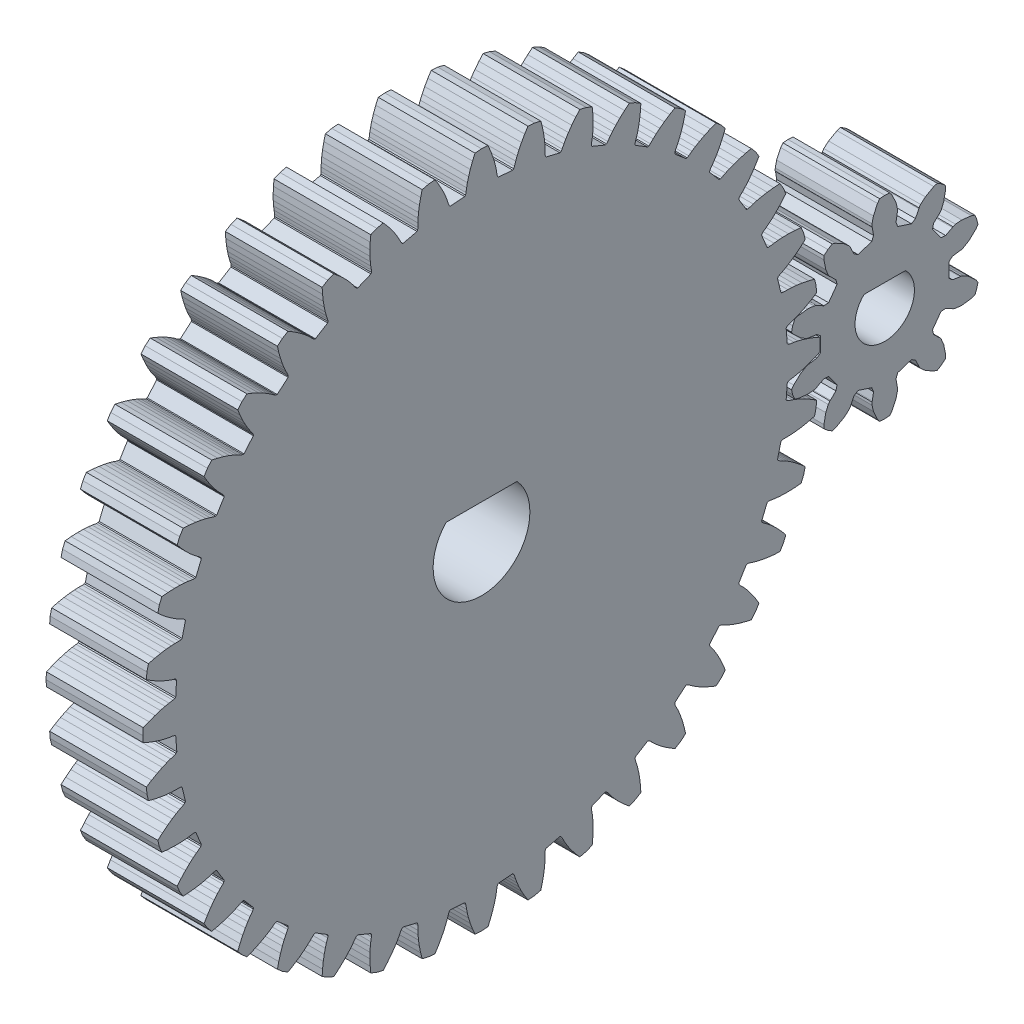
SolidWorks part; units mm, degrees
ref_plane "Front Plane" through (0, 0, 0) normal (0, 0, 1) x (1, 0, 0)
ref_plane "Top Plane" through (0, 0, 0) normal (0, 1, 0) x (1, 0, 0)
ref_plane "Right Plane" through (0, 0, 0) normal (1, 0, 0) x (0, 0, -1)
sketch "Sketch1" plane through (0, 0, 0) normal (1, 0, 0) x (0, 0, -1)
  line L0 (21.8563, -3.8943) -> (21.9563, -3.4775)
  line L1 (21.9563, -3.4775) -> (21.99, -3.0503)
  line L2 (21.99, -3.0503) -> (21.649, -2.8341)
  line L3 (21.649, -2.8341) -> (21.277, -2.6246)
  line L4 (21.277, -2.6246) -> (20.9438, -2.4593)
  line L5 (20.9438, -2.4593) -> (20.6527, -2.3335)
  line L6 (20.6527, -2.3335) -> (20.407, -2.2422)
  line L7 (20.407, -2.2422) -> (20.1556, -2.1635)
  line L8 (20.1556, -2.1635) -> (20.0438, -2.1072)
  line L9 (20.0438, -2.1072) -> (19.993, -2.0482)
  line L10 (19.993, -2.0482) -> (20.0673, -1.1046)
  line L11 (20.0673, -1.1046) -> (20.1267, -1.0542)
  line L12 (20.1267, -1.0542) -> (20.2459, -1.0162)
  line L13 (20.2459, -1.0162) -> (20.5065, -0.9778)
  line L14 (20.5065, -0.9778) -> (20.7635, -0.926)
  line L15 (20.7635, -0.926) -> (21.0706, -0.8473)
  line L16 (21.0706, -0.8473) -> (21.4257, -0.7362)
  line L17 (21.4257, -0.7362) -> (21.8259, -0.5875)
  line L18 (21.8259, -0.5875) -> (22.1964, -0.4273)
  line L19 (22.1964, -0.4273) -> (22.23, 0)
  line L20 (22.23, 0) -> (22.1964, 0.4273)
  line L21 (22.1964, 0.4273) -> (21.8259, 0.5875)
  line L22 (21.8259, 0.5875) -> (21.4257, 0.7362)
  line L23 (21.4257, 0.7362) -> (21.0706, 0.8473)
  line L24 (21.0706, 0.8473) -> (20.7635, 0.926)
  line L25 (20.7635, 0.926) -> (20.5065, 0.9778)
  line L26 (20.5065, 0.9778) -> (20.2459, 1.0162)
  line L27 (20.2459, 1.0162) -> (20.1267, 1.0542)
  line L28 (20.1267, 1.0542) -> (20.0673, 1.1046)
  line L29 (20.0673, 1.1046) -> (19.993, 2.0482)
  line L30 (19.993, 2.0482) -> (20.0438, 2.1072)
  line L31 (20.0438, 2.1072) -> (20.1556, 2.1635)
  line L32 (20.1556, 2.1635) -> (20.407, 2.2422)
  line L33 (20.407, 2.2422) -> (20.6527, 2.3335)
  line L34 (20.6527, 2.3335) -> (20.9438, 2.4593)
  line L35 (20.9438, 2.4593) -> (21.277, 2.6246)
  line L36 (21.277, 2.6246) -> (21.649, 2.8341)
  line L37 (21.649, 2.8341) -> (21.99, 3.0503)
  line L38 (21.99, 3.0503) -> (21.9563, 3.4775)
  line L39 (21.9563, 3.4775) -> (21.8563, 3.8943)
  line L40 (21.8563, 3.8943) -> (21.4652, 3.9946)
  line L41 (21.4652, 3.9946) -> (21.0467, 4.0788)
  line L42 (21.0467, 4.0788) -> (20.6787, 4.133)
  line L43 (20.6787, 4.133) -> (20.363, 4.1628)
  line L44 (20.363, 4.1628) -> (20.1011, 4.1737)
  line L45 (20.1011, 4.1737) -> (19.8377, 4.1708)
  line L46 (19.8377, 4.1708) -> (19.714, 4.1898)
  line L47 (19.714, 4.1898) -> (19.6474, 4.2302)
  line L48 (19.6474, 4.2302) -> (19.4265, 5.1506)
  line L49 (19.4265, 5.1506) -> (19.4674, 5.2168)
  line L50 (19.4674, 5.2168) -> (19.569, 5.2899)
  line L51 (19.569, 5.2899) -> (19.805, 5.4069)
  line L52 (19.805, 5.4069) -> (20.0334, 5.5355)
  line L53 (20.0334, 5.5355) -> (20.3012, 5.7054)
  line L54 (20.3012, 5.7054) -> (20.6045, 5.9208)
  line L55 (20.6045, 5.9208) -> (20.9392, 6.1858)
  line L56 (20.9392, 6.1858) -> (21.2421, 6.4527)
  line L57 (21.2421, 6.4527) -> (21.142, 6.8695)
  line L58 (21.142, 6.8695) -> (20.978, 7.2654)
  line L59 (20.978, 7.2654) -> (20.5761, 7.3033)
  line L60 (20.5761, 7.3033) -> (20.1495, 7.321)
  line L61 (20.1495, 7.321) -> (19.7775, 7.317)
  line L62 (19.7775, 7.317) -> (19.4611, 7.297)
  line L63 (19.4611, 7.297) -> (19.2007, 7.2668)
  line L64 (19.2007, 7.2668) -> (18.941, 7.2228)
  line L65 (18.941, 7.2228) -> (18.8158, 7.2221)
  line L66 (18.8158, 7.2221) -> (18.7438, 7.2516)
  line L67 (18.7438, 7.2516) -> (18.3815, 8.1262)
  line L68 (18.3815, 8.1262) -> (18.4116, 8.198)
  line L69 (18.4116, 8.198) -> (18.5006, 8.286)
  line L70 (18.5006, 8.286) -> (18.7153, 8.4385)
  line L71 (18.7153, 8.4385) -> (18.9208, 8.6013)
  line L72 (18.9208, 8.6013) -> (19.1587, 8.8109)
  line L73 (19.1587, 8.8109) -> (19.4246, 9.0711)
  line L74 (19.4246, 9.0711) -> (19.7137, 9.3853)
  line L75 (19.7137, 9.3853) -> (19.9711, 9.6963)
  line L76 (19.9711, 9.6963) -> (19.8071, 10.0922)
  line L77 (19.8071, 10.0922) -> (19.5832, 10.4577)
  line L78 (19.5832, 10.4577) -> (19.1803, 10.4322)
  line L79 (19.1803, 10.4322) -> (18.7562, 10.383)
  line L80 (18.7562, 10.383) -> (18.3894, 10.3208)
  line L81 (18.3894, 10.3208) -> (18.08, 10.2515)
  line L82 (18.08, 10.2515) -> (17.8275, 10.181)
  line L83 (17.8275, 10.181) -> (17.5779, 10.0969)
  line L84 (17.5779, 10.0969) -> (17.4544, 10.0767)
  line L85 (17.4544, 10.0767) -> (17.3786, 10.0945)
  line L86 (17.3786, 10.0945) -> (16.884, 10.9016)
  line L87 (16.884, 10.9016) -> (16.9025, 10.9773)
  line L88 (16.9025, 10.9773) -> (16.9766, 11.0782)
  line L89 (16.9766, 11.0782) -> (17.1648, 11.2624)
  line L90 (17.1648, 11.2624) -> (17.3423, 11.4553)
  line L91 (17.3423, 11.4553) -> (17.5445, 11.6995)
  line L92 (17.5445, 11.6995) -> (17.7664, 11.9981)
  line L93 (17.7664, 11.9981) -> (18.0028, 12.3536)
  line L94 (18.0028, 12.3536) -> (18.2084, 12.701)
  line L95 (18.2084, 12.701) -> (17.9845, 13.0665)
  line L96 (17.9845, 13.0665) -> (17.7061, 13.3924)
  line L97 (17.7061, 13.3924) -> (17.3122, 13.3042)
  line L98 (17.3122, 13.3042) -> (16.901, 13.1892)
  line L99 (16.901, 13.1892) -> (16.5485, 13.0705)
  line L100 (16.5485, 13.0705) -> (16.2537, 12.9537)
  line L101 (16.2537, 12.9537) -> (16.0154, 12.8445)
  line L102 (16.0154, 12.8445) -> (15.782, 12.7224)
  line L103 (15.782, 12.7224) -> (15.6632, 12.6831)
  line L104 (15.6632, 12.6831) -> (15.5855, 12.6889)
  line L105 (15.5855, 12.6889) -> (14.9708, 13.4087)
  line L106 (14.9708, 13.4087) -> (14.9772, 13.4862)
  line L107 (14.9772, 13.4862) -> (15.0346, 13.5975)
  line L108 (15.0346, 13.5975) -> (15.1917, 13.8089)
  line L109 (15.1917, 13.8089) -> (15.3368, 14.0272)
  line L110 (15.3368, 14.0272) -> (15.4983, 14.3001)
  line L111 (15.4983, 14.3001) -> (15.6708, 14.6297)
  line L112 (15.6708, 14.6297) -> (15.8486, 15.0178)
  line L113 (15.8486, 15.0178) -> (15.9973, 15.3931)
  line L114 (15.9973, 15.3931) -> (15.719, 15.719)
  line L115 (15.719, 15.719) -> (15.3931, 15.9973)
  line L116 (15.3931, 15.9973) -> (15.0178, 15.8486)
  line L117 (15.0178, 15.8486) -> (14.6297, 15.6708)
  line L118 (14.6297, 15.6708) -> (14.3001, 15.4983)
  line L119 (14.3001, 15.4983) -> (14.0272, 15.3368)
  line L120 (14.0272, 15.3368) -> (13.8089, 15.1917)
  line L121 (13.8089, 15.1917) -> (13.5975, 15.0346)
  line L122 (13.5975, 15.0346) -> (13.4862, 14.9772)
  line L123 (13.4862, 14.9772) -> (13.4087, 14.9708)
  line L124 (13.4087, 14.9708) -> (12.6889, 15.5855)
  line L125 (12.6889, 15.5855) -> (12.6831, 15.6632)
  line L126 (12.6831, 15.6632) -> (12.7224, 15.782)
  line L127 (12.7224, 15.782) -> (12.8445, 16.0154)
  line L128 (12.8445, 16.0154) -> (12.9537, 16.2537)
  line L129 (12.9537, 16.2537) -> (13.0705, 16.5485)
  line L130 (13.0705, 16.5485) -> (13.1892, 16.901)
  line L131 (13.1892, 16.901) -> (13.3042, 17.3122)
  line L132 (13.3042, 17.3122) -> (13.3924, 17.7061)
  line L133 (13.3924, 17.7061) -> (13.0665, 17.9845)
  line L134 (13.0665, 17.9845) -> (12.701, 18.2084)
  line L135 (12.701, 18.2084) -> (12.3536, 18.0028)
  line L136 (12.3536, 18.0028) -> (11.9981, 17.7664)
  line L137 (11.9981, 17.7664) -> (11.6995, 17.5445)
  line L138 (11.6995, 17.5445) -> (11.4553, 17.3423)
  line L139 (11.4553, 17.3423) -> (11.2624, 17.1648)
  line L140 (11.2624, 17.1648) -> (11.0782, 16.9766)
  line L141 (11.0782, 16.9766) -> (10.9773, 16.9025)
  line L142 (10.9773, 16.9025) -> (10.9016, 16.884)
  line L143 (10.9016, 16.884) -> (10.0945, 17.3786)
  line L144 (10.0945, 17.3786) -> (10.0767, 17.4544)
  line L145 (10.0767, 17.4544) -> (10.0969, 17.5779)
  line L146 (10.0969, 17.5779) -> (10.181, 17.8275)
  line L147 (10.181, 17.8275) -> (10.2515, 18.08)
  line L148 (10.2515, 18.08) -> (10.3208, 18.3894)
  line L149 (10.3208, 18.3894) -> (10.383, 18.7562)
  line L150 (10.383, 18.7562) -> (10.4322, 19.1803)
  line L151 (10.4322, 19.1803) -> (10.4577, 19.5832)
  line L152 (10.4577, 19.5832) -> (10.0922, 19.8071)
  line L153 (10.0922, 19.8071) -> (9.6963, 19.9711)
  line L154 (9.6963, 19.9711) -> (9.3853, 19.7137)
  line L155 (9.3853, 19.7137) -> (9.0711, 19.4246)
  line L156 (9.0711, 19.4246) -> (8.8109, 19.1587)
  line L157 (8.8109, 19.1587) -> (8.6013, 18.9208)
  line L158 (8.6013, 18.9208) -> (8.4385, 18.7153)
  line L159 (8.4385, 18.7153) -> (8.286, 18.5006)
  line L160 (8.286, 18.5006) -> (8.198, 18.4116)
  line L161 (8.198, 18.4116) -> (8.1262, 18.3815)
  line L162 (8.1262, 18.3815) -> (7.2516, 18.7438)
  line L163 (7.2516, 18.7438) -> (7.2221, 18.8158)
  line L164 (7.2221, 18.8158) -> (7.2228, 18.941)
  line L165 (7.2228, 18.941) -> (7.2668, 19.2007)
  line L166 (7.2668, 19.2007) -> (7.297, 19.4611)
  line L167 (7.297, 19.4611) -> (7.317, 19.7775)
  line L168 (7.317, 19.7775) -> (7.321, 20.1495)
  line L169 (7.321, 20.1495) -> (7.3033, 20.5761)
  line L170 (7.3033, 20.5761) -> (7.2654, 20.978)
  line L171 (7.2654, 20.978) -> (6.8695, 21.142)
  line L172 (6.8695, 21.142) -> (6.4527, 21.2421)
  line L173 (6.4527, 21.2421) -> (6.1858, 20.9392)
  line L174 (6.1858, 20.9392) -> (5.9208, 20.6045)
  line L175 (5.9208, 20.6045) -> (5.7054, 20.3012)
  line L176 (5.7054, 20.3012) -> (5.5355, 20.0334)
  line L177 (5.5355, 20.0334) -> (5.4069, 19.805)
  line L178 (5.4069, 19.805) -> (5.2899, 19.569)
  line L179 (5.2899, 19.569) -> (5.2168, 19.4674)
  line L180 (5.2168, 19.4674) -> (5.1506, 19.4265)
  line L181 (5.1506, 19.4265) -> (4.2302, 19.6474)
  line L182 (4.2302, 19.6474) -> (4.1898, 19.714)
  line L183 (4.1898, 19.714) -> (4.1708, 19.8377)
  line L184 (4.1708, 19.8377) -> (4.1737, 20.1011)
  line L185 (4.1737, 20.1011) -> (4.1628, 20.363)
  line L186 (4.1628, 20.363) -> (4.133, 20.6787)
  line L187 (4.133, 20.6787) -> (4.0788, 21.0467)
  line L188 (4.0788, 21.0467) -> (3.9946, 21.4652)
  line L189 (3.9946, 21.4652) -> (3.8943, 21.8563)
  line L190 (3.8943, 21.8563) -> (3.4775, 21.9563)
  line L191 (3.4775, 21.9563) -> (3.0503, 21.99)
  line L192 (3.0503, 21.99) -> (2.8341, 21.649)
  line L193 (2.8341, 21.649) -> (2.6246, 21.277)
  line L194 (2.6246, 21.277) -> (2.4593, 20.9438)
  line L195 (2.4593, 20.9438) -> (2.3335, 20.6527)
  line L196 (2.3335, 20.6527) -> (2.2422, 20.407)
  line L197 (2.2422, 20.407) -> (2.1635, 20.1556)
  line L198 (2.1635, 20.1556) -> (2.1072, 20.0438)
  line L199 (2.1072, 20.0438) -> (2.0482, 19.993)
  line L200 (2.0482, 19.993) -> (1.1046, 20.0673)
  line L201 (1.1046, 20.0673) -> (1.0542, 20.1267)
  line L202 (1.0542, 20.1267) -> (1.0162, 20.2459)
  line L203 (1.0162, 20.2459) -> (0.9778, 20.5065)
  line L204 (0.9778, 20.5065) -> (0.926, 20.7635)
  line L205 (0.926, 20.7635) -> (0.8473, 21.0706)
  line L206 (0.8473, 21.0706) -> (0.7362, 21.4257)
  line L207 (0.7362, 21.4257) -> (0.5875, 21.8259)
  line L208 (0.5875, 21.8259) -> (0.4273, 22.1964)
  line L209 (0.4273, 22.1964) -> (0, 22.23)
  line L210 (0, 22.23) -> (-0.4273, 22.1964)
  line L211 (-0.4273, 22.1964) -> (-0.5875, 21.8259)
  line L212 (-0.5875, 21.8259) -> (-0.7362, 21.4257)
  line L213 (-0.7362, 21.4257) -> (-0.8473, 21.0706)
  line L214 (-0.8473, 21.0706) -> (-0.926, 20.7635)
  line L215 (-0.926, 20.7635) -> (-0.9778, 20.5065)
  line L216 (-0.9778, 20.5065) -> (-1.0162, 20.2459)
  line L217 (-1.0162, 20.2459) -> (-1.0542, 20.1267)
  line L218 (-1.0542, 20.1267) -> (-1.1046, 20.0673)
  line L219 (-1.1046, 20.0673) -> (-2.0482, 19.993)
  line L220 (-2.0482, 19.993) -> (-2.1072, 20.0438)
  line L221 (-2.1072, 20.0438) -> (-2.1635, 20.1556)
  line L222 (-2.1635, 20.1556) -> (-2.2422, 20.407)
  line L223 (-2.2422, 20.407) -> (-2.3335, 20.6527)
  line L224 (-2.3335, 20.6527) -> (-2.4593, 20.9438)
  line L225 (-2.4593, 20.9438) -> (-2.6246, 21.277)
  line L226 (-2.6246, 21.277) -> (-2.8341, 21.649)
  line L227 (-2.8341, 21.649) -> (-3.0503, 21.99)
  line L228 (-3.0503, 21.99) -> (-3.4775, 21.9563)
  line L229 (-3.4775, 21.9563) -> (-3.8943, 21.8563)
  line L230 (-3.8943, 21.8563) -> (-3.9946, 21.4652)
  line L231 (-3.9946, 21.4652) -> (-4.0788, 21.0467)
  line L232 (-4.0788, 21.0467) -> (-4.133, 20.6787)
  line L233 (-4.133, 20.6787) -> (-4.1628, 20.363)
  line L234 (-4.1628, 20.363) -> (-4.1737, 20.1011)
  line L235 (-4.1737, 20.1011) -> (-4.1708, 19.8377)
  line L236 (-4.1708, 19.8377) -> (-4.1898, 19.714)
  line L237 (-4.1898, 19.714) -> (-4.2302, 19.6474)
  line L238 (-4.2302, 19.6474) -> (-5.1506, 19.4265)
  line L239 (-5.1506, 19.4265) -> (-5.2168, 19.4674)
  line L240 (-5.2168, 19.4674) -> (-5.2899, 19.569)
  line L241 (-5.2899, 19.569) -> (-5.4069, 19.805)
  line L242 (-5.4069, 19.805) -> (-5.5355, 20.0334)
  line L243 (-5.5355, 20.0334) -> (-5.7054, 20.3012)
  line L244 (-5.7054, 20.3012) -> (-5.9208, 20.6045)
  line L245 (-5.9208, 20.6045) -> (-6.1858, 20.9392)
  line L246 (-6.1858, 20.9392) -> (-6.4527, 21.2421)
  line L247 (-6.4527, 21.2421) -> (-6.8695, 21.142)
  line L248 (-6.8695, 21.142) -> (-7.2654, 20.978)
  line L249 (-7.2654, 20.978) -> (-7.3033, 20.5761)
  line L250 (-7.3033, 20.5761) -> (-7.321, 20.1495)
  line L251 (-7.321, 20.1495) -> (-7.317, 19.7775)
  line L252 (-7.317, 19.7775) -> (-7.297, 19.4611)
  line L253 (-7.297, 19.4611) -> (-7.2668, 19.2007)
  line L254 (-7.2668, 19.2007) -> (-7.2228, 18.941)
  line L255 (-7.2228, 18.941) -> (-7.2221, 18.8158)
  line L256 (-7.2221, 18.8158) -> (-7.2516, 18.7438)
  line L257 (-7.2516, 18.7438) -> (-8.1262, 18.3815)
  line L258 (-8.1262, 18.3815) -> (-8.198, 18.4116)
  line L259 (-8.198, 18.4116) -> (-8.286, 18.5006)
  line L260 (-8.286, 18.5006) -> (-8.4385, 18.7153)
  line L261 (-8.4385, 18.7153) -> (-8.6013, 18.9208)
  line L262 (-8.6013, 18.9208) -> (-8.8109, 19.1587)
  line L263 (-8.8109, 19.1587) -> (-9.0711, 19.4246)
  line L264 (-9.0711, 19.4246) -> (-9.3853, 19.7137)
  line L265 (-9.3853, 19.7137) -> (-9.6963, 19.9711)
  line L266 (-9.6963, 19.9711) -> (-10.0922, 19.8071)
  line L267 (-10.0922, 19.8071) -> (-10.4577, 19.5832)
  line L268 (-10.4577, 19.5832) -> (-10.4322, 19.1803)
  line L269 (-10.4322, 19.1803) -> (-10.383, 18.7562)
  line L270 (-10.383, 18.7562) -> (-10.3208, 18.3894)
  line L271 (-10.3208, 18.3894) -> (-10.2515, 18.08)
  line L272 (-10.2515, 18.08) -> (-10.181, 17.8275)
  line L273 (-10.181, 17.8275) -> (-10.0969, 17.5779)
  line L274 (-10.0969, 17.5779) -> (-10.0767, 17.4544)
  line L275 (-10.0767, 17.4544) -> (-10.0945, 17.3786)
  line L276 (-10.0945, 17.3786) -> (-10.9016, 16.884)
  line L277 (-10.9016, 16.884) -> (-10.9773, 16.9025)
  line L278 (-10.9773, 16.9025) -> (-11.0782, 16.9766)
  line L279 (-11.0782, 16.9766) -> (-11.2624, 17.1648)
  line L280 (-11.2624, 17.1648) -> (-11.4553, 17.3423)
  line L281 (-11.4553, 17.3423) -> (-11.6995, 17.5445)
  line L282 (-11.6995, 17.5445) -> (-11.9981, 17.7664)
  line L283 (-11.9981, 17.7664) -> (-12.3536, 18.0028)
  line L284 (-12.3536, 18.0028) -> (-12.701, 18.2084)
  line L285 (-12.701, 18.2084) -> (-13.0665, 17.9845)
  line L286 (-13.0665, 17.9845) -> (-13.3924, 17.7061)
  line L287 (-13.3924, 17.7061) -> (-13.3042, 17.3122)
  line L288 (-13.3042, 17.3122) -> (-13.1892, 16.901)
  line L289 (-13.1892, 16.901) -> (-13.0705, 16.5485)
  line L290 (-13.0705, 16.5485) -> (-12.9537, 16.2537)
  line L291 (-12.9537, 16.2537) -> (-12.8445, 16.0154)
  line L292 (-12.8445, 16.0154) -> (-12.7224, 15.782)
  line L293 (-12.7224, 15.782) -> (-12.6831, 15.6632)
  line L294 (-12.6831, 15.6632) -> (-12.6889, 15.5855)
  line L295 (-12.6889, 15.5855) -> (-13.4087, 14.9708)
  line L296 (-13.4087, 14.9708) -> (-13.4862, 14.9772)
  line L297 (-13.4862, 14.9772) -> (-13.5975, 15.0346)
  line L298 (-13.5975, 15.0346) -> (-13.8089, 15.1917)
  line L299 (-13.8089, 15.1917) -> (-14.0272, 15.3368)
  line L300 (-14.0272, 15.3368) -> (-14.3001, 15.4983)
  line L301 (-14.3001, 15.4983) -> (-14.6297, 15.6708)
  line L302 (-14.6297, 15.6708) -> (-15.0178, 15.8486)
  line L303 (-15.0178, 15.8486) -> (-15.3931, 15.9973)
  line L304 (-15.3931, 15.9973) -> (-15.719, 15.719)
  line L305 (-15.719, 15.719) -> (-15.9973, 15.3931)
  line L306 (-15.9973, 15.3931) -> (-15.8486, 15.0178)
  line L307 (-15.8486, 15.0178) -> (-15.6708, 14.6297)
  line L308 (-15.6708, 14.6297) -> (-15.4983, 14.3001)
  line L309 (-15.4983, 14.3001) -> (-15.3368, 14.0272)
  line L310 (-15.3368, 14.0272) -> (-15.1917, 13.8089)
  line L311 (-15.1917, 13.8089) -> (-15.0346, 13.5975)
  line L312 (-15.0346, 13.5975) -> (-14.9772, 13.4862)
  line L313 (-14.9772, 13.4862) -> (-14.9708, 13.4087)
  line L314 (-14.9708, 13.4087) -> (-15.5855, 12.6889)
  line L315 (-15.5855, 12.6889) -> (-15.6632, 12.6831)
  line L316 (-15.6632, 12.6831) -> (-15.782, 12.7224)
  line L317 (-15.782, 12.7224) -> (-16.0154, 12.8445)
  line L318 (-16.0154, 12.8445) -> (-16.2537, 12.9537)
  line L319 (-16.2537, 12.9537) -> (-16.5485, 13.0705)
  line L320 (-16.5485, 13.0705) -> (-16.901, 13.1892)
  line L321 (-16.901, 13.1892) -> (-17.3122, 13.3042)
  line L322 (-17.3122, 13.3042) -> (-17.7061, 13.3924)
  line L323 (-17.7061, 13.3924) -> (-17.9845, 13.0665)
  line L324 (-17.9845, 13.0665) -> (-18.2084, 12.701)
  line L325 (-18.2084, 12.701) -> (-18.0028, 12.3536)
  line L326 (-18.0028, 12.3536) -> (-17.7664, 11.9981)
  line L327 (-17.7664, 11.9981) -> (-17.5445, 11.6995)
  line L328 (-17.5445, 11.6995) -> (-17.3423, 11.4553)
  line L329 (-17.3423, 11.4553) -> (-17.1648, 11.2624)
  line L330 (-17.1648, 11.2624) -> (-16.9766, 11.0782)
  line L331 (-16.9766, 11.0782) -> (-16.9025, 10.9773)
  line L332 (-16.9025, 10.9773) -> (-16.884, 10.9016)
  line L333 (-16.884, 10.9016) -> (-17.3786, 10.0945)
  line L334 (-17.3786, 10.0945) -> (-17.4544, 10.0767)
  line L335 (-17.4544, 10.0767) -> (-17.5779, 10.0969)
  line L336 (-17.5779, 10.0969) -> (-17.8275, 10.181)
  line L337 (-17.8275, 10.181) -> (-18.08, 10.2515)
  line L338 (-18.08, 10.2515) -> (-18.3894, 10.3208)
  line L339 (-18.3894, 10.3208) -> (-18.7562, 10.383)
  line L340 (-18.7562, 10.383) -> (-19.1803, 10.4322)
  line L341 (-19.1803, 10.4322) -> (-19.5832, 10.4577)
  line L342 (-19.5832, 10.4577) -> (-19.8071, 10.0922)
  line L343 (-19.8071, 10.0922) -> (-19.9711, 9.6963)
  line L344 (-19.9711, 9.6963) -> (-19.7137, 9.3853)
  line L345 (-19.7137, 9.3853) -> (-19.4246, 9.0711)
  line L346 (-19.4246, 9.0711) -> (-19.1587, 8.8109)
  line L347 (-19.1587, 8.8109) -> (-18.9208, 8.6013)
  line L348 (-18.9208, 8.6013) -> (-18.7153, 8.4385)
  line L349 (-18.7153, 8.4385) -> (-18.5006, 8.286)
  line L350 (-18.5006, 8.286) -> (-18.4116, 8.198)
  line L351 (-18.4116, 8.198) -> (-18.3815, 8.1262)
  line L352 (-18.3815, 8.1262) -> (-18.7438, 7.2516)
  line L353 (-18.7438, 7.2516) -> (-18.8158, 7.2221)
  line L354 (-18.8158, 7.2221) -> (-18.941, 7.2228)
  line L355 (-18.941, 7.2228) -> (-19.2007, 7.2668)
  line L356 (-19.2007, 7.2668) -> (-19.4611, 7.297)
  line L357 (-19.4611, 7.297) -> (-19.7775, 7.317)
  line L358 (-19.7775, 7.317) -> (-20.1495, 7.321)
  line L359 (-20.1495, 7.321) -> (-20.5761, 7.3033)
  line L360 (-20.5761, 7.3033) -> (-20.978, 7.2654)
  line L361 (-20.978, 7.2654) -> (-21.142, 6.8695)
  line L362 (-21.142, 6.8695) -> (-21.2421, 6.4527)
  line L363 (-21.2421, 6.4527) -> (-20.9392, 6.1858)
  line L364 (-20.9392, 6.1858) -> (-20.6045, 5.9208)
  line L365 (-20.6045, 5.9208) -> (-20.3012, 5.7054)
  line L366 (-20.3012, 5.7054) -> (-20.0334, 5.5355)
  line L367 (-20.0334, 5.5355) -> (-19.805, 5.4069)
  line L368 (-19.805, 5.4069) -> (-19.569, 5.2899)
  line L369 (-19.569, 5.2899) -> (-19.4674, 5.2168)
  line L370 (-19.4674, 5.2168) -> (-19.4265, 5.1506)
  line L371 (-19.4265, 5.1506) -> (-19.6474, 4.2302)
  line L372 (-19.6474, 4.2302) -> (-19.714, 4.1898)
  line L373 (-19.714, 4.1898) -> (-19.8377, 4.1708)
  line L374 (-19.8377, 4.1708) -> (-20.1011, 4.1737)
  line L375 (-20.1011, 4.1737) -> (-20.363, 4.1628)
  line L376 (-20.363, 4.1628) -> (-20.6787, 4.133)
  line L377 (-20.6787, 4.133) -> (-21.0467, 4.0788)
  line L378 (-21.0467, 4.0788) -> (-21.4652, 3.9946)
  line L379 (-21.4652, 3.9946) -> (-21.8563, 3.8943)
  line L380 (-21.8563, 3.8943) -> (-21.9563, 3.4775)
  line L381 (-21.9563, 3.4775) -> (-21.99, 3.0503)
  line L382 (-21.99, 3.0503) -> (-21.649, 2.8341)
  line L383 (-21.649, 2.8341) -> (-21.277, 2.6246)
  line L384 (-21.277, 2.6246) -> (-20.9438, 2.4593)
  line L385 (-20.9438, 2.4593) -> (-20.6527, 2.3335)
  line L386 (-20.6527, 2.3335) -> (-20.407, 2.2422)
  line L387 (-20.407, 2.2422) -> (-20.1556, 2.1635)
  line L388 (-20.1556, 2.1635) -> (-20.0438, 2.1072)
  line L389 (-20.0438, 2.1072) -> (-20.0162, 2.0156)
  line L390 (-20.0162, 2.0156) -> (-20.0673, 1.1046)
  line L391 (-20.0673, 1.1046) -> (-20.1267, 1.0542)
  line L392 (-20.1267, 1.0542) -> (-20.2459, 1.0162)
  line L393 (-20.2459, 1.0162) -> (-20.5065, 0.9778)
  line L394 (-20.5065, 0.9778) -> (-20.7635, 0.926)
  line L395 (-20.7635, 0.926) -> (-21.0706, 0.8473)
  line L396 (-21.0706, 0.8473) -> (-21.4257, 0.7362)
  line L397 (-21.4257, 0.7362) -> (-21.8259, 0.5875)
  line L398 (-21.8259, 0.5875) -> (-22.1964, 0.4273)
  line L399 (-22.1964, 0.4273) -> (-22.23, 0)
  line L400 (-22.23, 0) -> (-22.1964, -0.4273)
  line L401 (-22.1964, -0.4273) -> (-21.8259, -0.5875)
  line L402 (-21.8259, -0.5875) -> (-21.4257, -0.7362)
  line L403 (-21.4257, -0.7362) -> (-21.0706, -0.8473)
  line L404 (-21.0706, -0.8473) -> (-20.7635, -0.926)
  line L405 (-20.7635, -0.926) -> (-20.5065, -0.9778)
  line L406 (-20.5065, -0.9778) -> (-20.2459, -1.0162)
  line L407 (-20.2459, -1.0162) -> (-20.1267, -1.0542)
  line L408 (-20.1267, -1.0542) -> (-20.0673, -1.1046)
  line L409 (-20.0673, -1.1046) -> (-19.993, -2.0482)
  line L410 (-19.993, -2.0482) -> (-20.0438, -2.1072)
  line L411 (-20.0438, -2.1072) -> (-20.1556, -2.1635)
  line L412 (-20.1556, -2.1635) -> (-20.407, -2.2422)
  line L413 (-20.407, -2.2422) -> (-20.6527, -2.3335)
  line L414 (-20.6527, -2.3335) -> (-20.9438, -2.4593)
  line L415 (-20.9438, -2.4593) -> (-21.277, -2.6246)
  line L416 (-21.277, -2.6246) -> (-21.649, -2.8341)
  line L417 (-21.649, -2.8341) -> (-21.99, -3.0503)
  line L418 (-21.99, -3.0503) -> (-21.9563, -3.4775)
  line L419 (-21.9563, -3.4775) -> (-21.8563, -3.8943)
  line L420 (-21.8563, -3.8943) -> (-21.4652, -3.9946)
  line L421 (-21.4652, -3.9946) -> (-21.0467, -4.0788)
  line L422 (-21.0467, -4.0788) -> (-20.6787, -4.133)
  line L423 (-20.6787, -4.133) -> (-20.363, -4.1628)
  line L424 (-20.363, -4.1628) -> (-20.1011, -4.1737)
  line L425 (-20.1011, -4.1737) -> (-19.8377, -4.1708)
  line L426 (-19.8377, -4.1708) -> (-19.714, -4.1898)
  line L427 (-19.714, -4.1898) -> (-19.6474, -4.2302)
  line L428 (-19.6474, -4.2302) -> (-19.4265, -5.1506)
  line L429 (-19.4265, -5.1506) -> (-19.4674, -5.2168)
  line L430 (-19.4674, -5.2168) -> (-19.569, -5.2899)
  line L431 (-19.569, -5.2899) -> (-19.805, -5.4069)
  line L432 (-19.805, -5.4069) -> (-20.0334, -5.5355)
  line L433 (-20.0334, -5.5355) -> (-20.3012, -5.7054)
  line L434 (-20.3012, -5.7054) -> (-20.6045, -5.9208)
  line L435 (-20.6045, -5.9208) -> (-20.9392, -6.1858)
  line L436 (-20.9392, -6.1858) -> (-21.2421, -6.4527)
  line L437 (-21.2421, -6.4527) -> (-21.142, -6.8695)
  line L438 (-21.142, -6.8695) -> (-20.978, -7.2654)
  line L439 (-20.978, -7.2654) -> (-20.5761, -7.3033)
  line L440 (-20.5761, -7.3033) -> (-20.1495, -7.321)
  line L441 (-20.1495, -7.321) -> (-19.7775, -7.317)
  line L442 (-19.7775, -7.317) -> (-19.4611, -7.297)
  line L443 (-19.4611, -7.297) -> (-19.2007, -7.2668)
  line L444 (-19.2007, -7.2668) -> (-18.941, -7.2228)
  line L445 (-18.941, -7.2228) -> (-18.8158, -7.2221)
  line L446 (-18.8158, -7.2221) -> (-18.7438, -7.2516)
  line L447 (-18.7438, -7.2516) -> (-18.3815, -8.1262)
  line L448 (-18.3815, -8.1262) -> (-18.4116, -8.198)
  line L449 (-18.4116, -8.198) -> (-18.5006, -8.286)
  line L450 (-18.5006, -8.286) -> (-18.7153, -8.4385)
  line L451 (-18.7153, -8.4385) -> (-18.9208, -8.6013)
  line L452 (-18.9208, -8.6013) -> (-19.1587, -8.8109)
  line L453 (-19.1587, -8.8109) -> (-19.4246, -9.0711)
  line L454 (-19.4246, -9.0711) -> (-19.7137, -9.3853)
  line L455 (-19.7137, -9.3853) -> (-19.9711, -9.6963)
  line L456 (-19.9711, -9.6963) -> (-19.8071, -10.0922)
  line L457 (-19.8071, -10.0922) -> (-19.5832, -10.4577)
  line L458 (-19.5832, -10.4577) -> (-19.1803, -10.4322)
  line L459 (-19.1803, -10.4322) -> (-18.7562, -10.383)
  line L460 (-18.7562, -10.383) -> (-18.3894, -10.3208)
  line L461 (-18.3894, -10.3208) -> (-18.08, -10.2515)
  line L462 (-18.08, -10.2515) -> (-17.8275, -10.181)
  line L463 (-17.8275, -10.181) -> (-17.5779, -10.0969)
  line L464 (-17.5779, -10.0969) -> (-17.4544, -10.0767)
  line L465 (-17.4544, -10.0767) -> (-17.3786, -10.0945)
  line L466 (-17.3786, -10.0945) -> (-16.884, -10.9016)
  line L467 (-16.884, -10.9016) -> (-16.9025, -10.9773)
  line L468 (-16.9025, -10.9773) -> (-16.9766, -11.0782)
  line L469 (-16.9766, -11.0782) -> (-17.1648, -11.2624)
  line L470 (-17.1648, -11.2624) -> (-17.3423, -11.4553)
  line L471 (-17.3423, -11.4553) -> (-17.5445, -11.6995)
  line L472 (-17.5445, -11.6995) -> (-17.7664, -11.9981)
  line L473 (-17.7664, -11.9981) -> (-18.0028, -12.3536)
  line L474 (-18.0028, -12.3536) -> (-18.2084, -12.701)
  line L475 (-18.2084, -12.701) -> (-17.9845, -13.0665)
  line L476 (-17.9845, -13.0665) -> (-17.7061, -13.3924)
  line L477 (-17.7061, -13.3924) -> (-17.3122, -13.3042)
  line L478 (-17.3122, -13.3042) -> (-16.901, -13.1892)
  line L479 (-16.901, -13.1892) -> (-16.5485, -13.0705)
  line L480 (-16.5485, -13.0705) -> (-16.2537, -12.9537)
  line L481 (-16.2537, -12.9537) -> (-16.0154, -12.8445)
  line L482 (-16.0154, -12.8445) -> (-15.782, -12.7224)
  line L483 (-15.782, -12.7224) -> (-15.6632, -12.6831)
  line L484 (-15.6632, -12.6831) -> (-15.5855, -12.6889)
  line L485 (-15.5855, -12.6889) -> (-14.9708, -13.4087)
  line L486 (-14.9708, -13.4087) -> (-14.9772, -13.4862)
  line L487 (-14.9772, -13.4862) -> (-15.0346, -13.5975)
  line L488 (-15.0346, -13.5975) -> (-15.1917, -13.8089)
  line L489 (-15.1917, -13.8089) -> (-15.3368, -14.0272)
  line L490 (-15.3368, -14.0272) -> (-15.4983, -14.3001)
  line L491 (-15.4983, -14.3001) -> (-15.6708, -14.6297)
  line L492 (-15.6708, -14.6297) -> (-15.8486, -15.0178)
  line L493 (-15.8486, -15.0178) -> (-15.9973, -15.3931)
  line L494 (-15.9973, -15.3931) -> (-15.719, -15.719)
  line L495 (-15.719, -15.719) -> (-15.3931, -15.9973)
  line L496 (-15.3931, -15.9973) -> (-15.0178, -15.8486)
  line L497 (-15.0178, -15.8486) -> (-14.6297, -15.6708)
  line L498 (-14.6297, -15.6708) -> (-14.3001, -15.4983)
  line L499 (-14.3001, -15.4983) -> (-14.0272, -15.3368)
  line L500 (-14.0272, -15.3368) -> (-13.8089, -15.1917)
  line L501 (-13.8089, -15.1917) -> (-13.5975, -15.0346)
  line L502 (-13.5975, -15.0346) -> (-13.4862, -14.9772)
  line L503 (-13.4862, -14.9772) -> (-13.4087, -14.9708)
  line L504 (-13.4087, -14.9708) -> (-12.6889, -15.5855)
  line L505 (-12.6889, -15.5855) -> (-12.6831, -15.6632)
  line L506 (-12.6831, -15.6632) -> (-12.7224, -15.782)
  line L507 (-12.7224, -15.782) -> (-12.8445, -16.0154)
  line L508 (-12.8445, -16.0154) -> (-12.9537, -16.2537)
  line L509 (-12.9537, -16.2537) -> (-13.0705, -16.5485)
  line L510 (-13.0705, -16.5485) -> (-13.1892, -16.901)
  line L511 (-13.1892, -16.901) -> (-13.3042, -17.3122)
  line L512 (-13.3042, -17.3122) -> (-13.3924, -17.7061)
  line L513 (-13.3924, -17.7061) -> (-13.0665, -17.9845)
  line L514 (-13.0665, -17.9845) -> (-12.701, -18.2084)
  line L515 (-12.701, -18.2084) -> (-12.3536, -18.0028)
  line L516 (-12.3536, -18.0028) -> (-11.9981, -17.7664)
  line L517 (-11.9981, -17.7664) -> (-11.6995, -17.5445)
  line L518 (-11.6995, -17.5445) -> (-11.4553, -17.3423)
  line L519 (-11.4553, -17.3423) -> (-11.2624, -17.1648)
  line L520 (-11.2624, -17.1648) -> (-11.0782, -16.9766)
  line L521 (-11.0782, -16.9766) -> (-10.9773, -16.9025)
  line L522 (-10.9773, -16.9025) -> (-10.9016, -16.884)
  line L523 (-10.9016, -16.884) -> (-10.0945, -17.3786)
  line L524 (-10.0945, -17.3786) -> (-10.0767, -17.4544)
  line L525 (-10.0767, -17.4544) -> (-10.0969, -17.5779)
  line L526 (-10.0969, -17.5779) -> (-10.181, -17.8275)
  line L527 (-10.181, -17.8275) -> (-10.2515, -18.08)
  line L528 (-10.2515, -18.08) -> (-10.3208, -18.3894)
  line L529 (-10.3208, -18.3894) -> (-10.383, -18.7562)
  line L530 (-10.383, -18.7562) -> (-10.4322, -19.1803)
  line L531 (-10.4322, -19.1803) -> (-10.4577, -19.5832)
  line L532 (-10.4577, -19.5832) -> (-10.0922, -19.8071)
  line L533 (-10.0922, -19.8071) -> (-9.6963, -19.9711)
  line L534 (-9.6963, -19.9711) -> (-9.3853, -19.7137)
  line L535 (-9.3853, -19.7137) -> (-9.0711, -19.4246)
  line L536 (-9.0711, -19.4246) -> (-8.8109, -19.1587)
  line L537 (-8.8109, -19.1587) -> (-8.6013, -18.9208)
  line L538 (-8.6013, -18.9208) -> (-8.4385, -18.7153)
  line L539 (-8.4385, -18.7153) -> (-8.286, -18.5006)
  line L540 (-8.286, -18.5006) -> (-8.198, -18.4116)
  line L541 (-8.198, -18.4116) -> (-8.1262, -18.3815)
  line L542 (-8.1262, -18.3815) -> (-7.2516, -18.7438)
  line L543 (-7.2516, -18.7438) -> (-7.2221, -18.8158)
  line L544 (-7.2221, -18.8158) -> (-7.2228, -18.941)
  line L545 (-7.2228, -18.941) -> (-7.2668, -19.2007)
  line L546 (-7.2668, -19.2007) -> (-7.297, -19.4611)
  line L547 (-7.297, -19.4611) -> (-7.317, -19.7775)
  line L548 (-7.317, -19.7775) -> (-7.321, -20.1495)
  line L549 (-7.321, -20.1495) -> (-7.3033, -20.5761)
  line L550 (-7.3033, -20.5761) -> (-7.2654, -20.978)
  line L551 (-7.2654, -20.978) -> (-6.8695, -21.142)
  line L552 (-6.8695, -21.142) -> (-6.4527, -21.2421)
  line L553 (-6.4527, -21.2421) -> (-6.1858, -20.9392)
  line L554 (-6.1858, -20.9392) -> (-5.9208, -20.6045)
  line L555 (-5.9208, -20.6045) -> (-5.7054, -20.3012)
  line L556 (-5.7054, -20.3012) -> (-5.5355, -20.0334)
  line L557 (-5.5355, -20.0334) -> (-5.4069, -19.805)
  line L558 (-5.4069, -19.805) -> (-5.2899, -19.569)
  line L559 (-5.2899, -19.569) -> (-5.2168, -19.4674)
  line L560 (-5.2168, -19.4674) -> (-5.1506, -19.4265)
  line L561 (-5.1506, -19.4265) -> (-4.2302, -19.6474)
  line L562 (-4.2302, -19.6474) -> (-4.1898, -19.714)
  line L563 (-4.1898, -19.714) -> (-4.1708, -19.8377)
  line L564 (-4.1708, -19.8377) -> (-4.1737, -20.1011)
  line L565 (-4.1737, -20.1011) -> (-4.1628, -20.363)
  line L566 (-4.1628, -20.363) -> (-4.133, -20.6787)
  line L567 (-4.133, -20.6787) -> (-4.0788, -21.0467)
  line L568 (-4.0788, -21.0467) -> (-3.9946, -21.4652)
  line L569 (-3.9946, -21.4652) -> (-3.8943, -21.8563)
  line L570 (-3.8943, -21.8563) -> (-3.4775, -21.9563)
  line L571 (-3.4775, -21.9563) -> (-3.0503, -21.99)
  line L572 (-3.0503, -21.99) -> (-2.8341, -21.649)
  line L573 (-2.8341, -21.649) -> (-2.6246, -21.277)
  line L574 (-2.6246, -21.277) -> (-2.4593, -20.9438)
  line L575 (-2.4593, -20.9438) -> (-2.3335, -20.6527)
  line L576 (-2.3335, -20.6527) -> (-2.2422, -20.407)
  line L577 (-2.2422, -20.407) -> (-2.1635, -20.1556)
  line L578 (-2.1635, -20.1556) -> (-2.1072, -20.0438)
  line L579 (-2.1072, -20.0438) -> (-2.0482, -19.993)
  line L580 (-2.0482, -19.993) -> (-1.1046, -20.0673)
  line L581 (-1.1046, -20.0673) -> (-1.0542, -20.1267)
  line L582 (-1.0542, -20.1267) -> (-1.0162, -20.2459)
  line L583 (-1.0162, -20.2459) -> (-0.9778, -20.5065)
  line L584 (-0.9778, -20.5065) -> (-0.926, -20.7635)
  line L585 (-0.926, -20.7635) -> (-0.8473, -21.0706)
  line L586 (-0.8473, -21.0706) -> (-0.7362, -21.4257)
  line L587 (-0.7362, -21.4257) -> (-0.5875, -21.8259)
  line L588 (-0.5875, -21.8259) -> (-0.4273, -22.1964)
  line L589 (-0.4273, -22.1964) -> (0, -22.23)
  line L590 (0, -22.23) -> (0.4273, -22.1964)
  line L591 (0.4273, -22.1964) -> (0.5875, -21.8259)
  line L592 (0.5875, -21.8259) -> (0.7362, -21.4257)
  line L593 (0.7362, -21.4257) -> (0.8473, -21.0706)
  line L594 (0.8473, -21.0706) -> (0.926, -20.7635)
  line L595 (0.926, -20.7635) -> (0.9778, -20.5065)
  line L596 (0.9778, -20.5065) -> (1.0162, -20.2459)
  line L597 (1.0162, -20.2459) -> (1.0542, -20.1267)
  line L598 (1.0542, -20.1267) -> (1.1046, -20.0673)
  line L599 (1.1046, -20.0673) -> (2.0482, -19.993)
  line L600 (2.0482, -19.993) -> (2.1072, -20.0438)
  line L601 (2.1072, -20.0438) -> (2.1635, -20.1556)
  line L602 (2.1635, -20.1556) -> (2.2422, -20.407)
  line L603 (2.2422, -20.407) -> (2.3335, -20.6527)
  line L604 (2.3335, -20.6527) -> (2.4593, -20.9438)
  line L605 (2.4593, -20.9438) -> (2.6246, -21.277)
  line L606 (2.6246, -21.277) -> (2.8341, -21.649)
  line L607 (2.8341, -21.649) -> (3.0503, -21.99)
  line L608 (3.0503, -21.99) -> (3.4775, -21.9563)
  line L609 (3.4775, -21.9563) -> (3.8943, -21.8563)
  line L610 (3.8943, -21.8563) -> (3.9946, -21.4652)
  line L611 (3.9946, -21.4652) -> (4.0788, -21.0467)
  line L612 (4.0788, -21.0467) -> (4.133, -20.6787)
  line L613 (4.133, -20.6787) -> (4.1628, -20.363)
  line L614 (4.1628, -20.363) -> (4.1737, -20.1011)
  line L615 (4.1737, -20.1011) -> (4.1708, -19.8377)
  line L616 (4.1708, -19.8377) -> (4.1898, -19.714)
  line L617 (4.1898, -19.714) -> (4.2302, -19.6474)
  line L618 (4.2302, -19.6474) -> (5.1506, -19.4265)
  line L619 (5.1506, -19.4265) -> (5.2168, -19.4674)
  line L620 (5.2168, -19.4674) -> (5.2899, -19.569)
  line L621 (5.2899, -19.569) -> (5.4069, -19.805)
  line L622 (5.4069, -19.805) -> (5.5355, -20.0334)
  line L623 (5.5355, -20.0334) -> (5.7054, -20.3012)
  line L624 (5.7054, -20.3012) -> (5.9208, -20.6045)
  line L625 (5.9208, -20.6045) -> (6.1858, -20.9392)
  line L626 (6.1858, -20.9392) -> (6.4527, -21.2421)
  line L627 (6.4527, -21.2421) -> (6.8695, -21.142)
  line L628 (6.8695, -21.142) -> (7.2654, -20.978)
  line L629 (7.2654, -20.978) -> (7.3033, -20.5761)
  line L630 (7.3033, -20.5761) -> (7.321, -20.1495)
  line L631 (7.321, -20.1495) -> (7.317, -19.7775)
  line L632 (7.317, -19.7775) -> (7.297, -19.4611)
  line L633 (7.297, -19.4611) -> (7.2668, -19.2007)
  line L634 (7.2668, -19.2007) -> (7.2228, -18.941)
  line L635 (7.2228, -18.941) -> (7.2221, -18.8158)
  line L636 (7.2221, -18.8158) -> (7.2516, -18.7438)
  line L637 (7.2516, -18.7438) -> (8.1262, -18.3815)
  line L638 (8.1262, -18.3815) -> (8.198, -18.4116)
  line L639 (8.198, -18.4116) -> (8.286, -18.5006)
  line L640 (8.286, -18.5006) -> (8.4385, -18.7153)
  line L641 (8.4385, -18.7153) -> (8.6013, -18.9208)
  line L642 (8.6013, -18.9208) -> (8.8109, -19.1587)
  line L643 (8.8109, -19.1587) -> (9.0711, -19.4246)
  line L644 (9.0711, -19.4246) -> (9.3853, -19.7137)
  line L645 (9.3853, -19.7137) -> (9.6963, -19.9711)
  line L646 (9.6963, -19.9711) -> (10.0922, -19.8071)
  line L647 (10.0922, -19.8071) -> (10.4577, -19.5832)
  line L648 (10.4577, -19.5832) -> (10.4322, -19.1803)
  line L649 (10.4322, -19.1803) -> (10.383, -18.7562)
  line L650 (10.383, -18.7562) -> (10.3208, -18.3894)
  line L651 (10.3208, -18.3894) -> (10.2515, -18.08)
  line L652 (10.2515, -18.08) -> (10.181, -17.8275)
  line L653 (10.181, -17.8275) -> (10.0969, -17.5779)
  line L654 (10.0969, -17.5779) -> (10.0767, -17.4544)
  line L655 (10.0767, -17.4544) -> (10.0945, -17.3786)
  line L656 (10.0945, -17.3786) -> (10.9016, -16.884)
  line L657 (10.9016, -16.884) -> (10.9773, -16.9025)
  line L658 (10.9773, -16.9025) -> (11.0782, -16.9766)
  line L659 (11.0782, -16.9766) -> (11.2624, -17.1648)
  line L660 (11.2624, -17.1648) -> (11.4553, -17.3423)
  line L661 (11.4553, -17.3423) -> (11.6995, -17.5445)
  line L662 (11.6995, -17.5445) -> (11.9981, -17.7664)
  line L663 (11.9981, -17.7664) -> (12.3536, -18.0028)
  line L664 (12.3536, -18.0028) -> (12.701, -18.2084)
  line L665 (12.701, -18.2084) -> (13.0665, -17.9845)
  line L666 (13.0665, -17.9845) -> (13.3924, -17.7061)
  line L667 (13.3924, -17.7061) -> (13.3042, -17.3122)
  line L668 (13.3042, -17.3122) -> (13.1892, -16.901)
  line L669 (13.1892, -16.901) -> (13.0705, -16.5485)
  line L670 (13.0705, -16.5485) -> (12.9537, -16.2537)
  line L671 (12.9537, -16.2537) -> (12.8445, -16.0154)
  line L672 (12.8445, -16.0154) -> (12.7224, -15.782)
  line L673 (12.7224, -15.782) -> (12.6831, -15.6632)
  line L674 (12.6831, -15.6632) -> (12.6889, -15.5855)
  line L675 (12.6889, -15.5855) -> (13.4087, -14.9708)
  line L676 (13.4087, -14.9708) -> (13.4862, -14.9772)
  line L677 (13.4862, -14.9772) -> (13.5975, -15.0346)
  line L678 (13.5975, -15.0346) -> (13.8089, -15.1917)
  line L679 (13.8089, -15.1917) -> (14.0272, -15.3368)
  line L680 (14.0272, -15.3368) -> (14.3001, -15.4983)
  line L681 (14.3001, -15.4983) -> (14.6297, -15.6708)
  line L682 (14.6297, -15.6708) -> (15.0178, -15.8486)
  line L683 (15.0178, -15.8486) -> (15.3931, -15.9973)
  line L684 (15.3931, -15.9973) -> (15.719, -15.719)
  line L685 (15.719, -15.719) -> (15.9973, -15.3931)
  line L686 (15.9973, -15.3931) -> (15.8486, -15.0178)
  line L687 (15.8486, -15.0178) -> (15.6708, -14.6297)
  line L688 (15.6708, -14.6297) -> (15.4983, -14.3001)
  line L689 (15.4983, -14.3001) -> (15.3368, -14.0272)
  line L690 (15.3368, -14.0272) -> (15.1917, -13.8089)
  line L691 (15.1917, -13.8089) -> (15.0346, -13.5975)
  line L692 (15.0346, -13.5975) -> (14.9772, -13.4862)
  line L693 (14.9772, -13.4862) -> (14.9708, -13.4087)
  line L694 (14.9708, -13.4087) -> (15.5855, -12.6889)
  line L695 (15.5855, -12.6889) -> (15.6632, -12.6831)
  line L696 (15.6632, -12.6831) -> (15.782, -12.7224)
  line L697 (15.782, -12.7224) -> (16.0154, -12.8445)
  line L698 (16.0154, -12.8445) -> (16.2537, -12.9537)
  line L699 (16.2537, -12.9537) -> (16.5485, -13.0705)
  line L700 (16.5485, -13.0705) -> (16.901, -13.1892)
  line L701 (16.901, -13.1892) -> (17.3122, -13.3042)
  line L702 (17.3122, -13.3042) -> (17.7061, -13.3924)
  line L703 (17.7061, -13.3924) -> (17.9845, -13.0665)
  line L704 (17.9845, -13.0665) -> (18.2084, -12.701)
  line L705 (18.2084, -12.701) -> (18.0028, -12.3536)
  line L706 (18.0028, -12.3536) -> (17.7664, -11.9981)
  line L707 (17.7664, -11.9981) -> (17.5445, -11.6995)
  line L708 (17.5445, -11.6995) -> (17.3423, -11.4553)
  line L709 (17.3423, -11.4553) -> (17.1648, -11.2624)
  line L710 (17.1648, -11.2624) -> (16.9766, -11.0782)
  line L711 (16.9766, -11.0782) -> (16.9025, -10.9773)
  line L712 (16.9025, -10.9773) -> (16.884, -10.9016)
  line L713 (16.884, -10.9016) -> (17.3786, -10.0945)
  line L714 (17.3786, -10.0945) -> (17.4544, -10.0767)
  line L715 (17.4544, -10.0767) -> (17.5779, -10.0969)
  line L716 (17.5779, -10.0969) -> (17.8275, -10.181)
  line L717 (17.8275, -10.181) -> (18.08, -10.2515)
  line L718 (18.08, -10.2515) -> (18.3894, -10.3208)
  line L719 (18.3894, -10.3208) -> (18.7562, -10.383)
  line L720 (18.7562, -10.383) -> (19.1803, -10.4322)
  line L721 (19.1803, -10.4322) -> (19.5832, -10.4577)
  line L722 (19.5832, -10.4577) -> (19.8071, -10.0922)
  line L723 (19.8071, -10.0922) -> (19.9711, -9.6963)
  line L724 (19.9711, -9.6963) -> (19.7137, -9.3853)
  line L725 (19.7137, -9.3853) -> (19.4246, -9.0711)
  line L726 (19.4246, -9.0711) -> (19.1587, -8.8109)
  line L727 (19.1587, -8.8109) -> (18.9208, -8.6013)
  line L728 (18.9208, -8.6013) -> (18.7153, -8.4385)
  line L729 (18.7153, -8.4385) -> (18.5006, -8.286)
  line L730 (18.5006, -8.286) -> (18.4116, -8.198)
  line L731 (18.4116, -8.198) -> (18.3815, -8.1262)
  line L732 (18.3815, -8.1262) -> (18.7438, -7.2516)
  line L733 (18.7438, -7.2516) -> (18.8158, -7.2221)
  line L734 (18.8158, -7.2221) -> (18.941, -7.2228)
  line L735 (18.941, -7.2228) -> (19.2007, -7.2668)
  line L736 (19.2007, -7.2668) -> (19.4611, -7.297)
  line L737 (19.4611, -7.297) -> (19.7775, -7.317)
  line L738 (19.7775, -7.317) -> (20.1495, -7.321)
  line L739 (20.1495, -7.321) -> (20.5761, -7.3033)
  line L740 (20.5761, -7.3033) -> (20.978, -7.2654)
  line L741 (20.978, -7.2654) -> (21.142, -6.8695)
  line L742 (21.142, -6.8695) -> (21.2421, -6.4527)
  line L743 (21.2421, -6.4527) -> (20.9392, -6.1858)
  line L744 (20.9392, -6.1858) -> (20.6045, -5.9208)
  line L745 (20.6045, -5.9208) -> (20.3012, -5.7054)
  line L746 (20.3012, -5.7054) -> (20.0334, -5.5355)
  line L747 (20.0334, -5.5355) -> (19.805, -5.4069)
  line L748 (19.805, -5.4069) -> (19.569, -5.2899)
  line L749 (19.569, -5.2899) -> (19.4674, -5.2168)
  line L750 (19.4674, -5.2168) -> (19.4265, -5.1506)
  line L751 (19.4265, -5.1506) -> (19.6474, -4.2302)
  line L752 (19.6474, -4.2302) -> (19.714, -4.1898)
  line L753 (19.714, -4.1898) -> (19.8377, -4.1708)
  line L754 (19.8377, -4.1708) -> (20.1011, -4.1737)
  line L755 (20.1011, -4.1737) -> (20.363, -4.1628)
  line L756 (20.363, -4.1628) -> (20.6787, -4.133)
  line L757 (20.6787, -4.133) -> (21.0467, -4.0788)
  line L758 (21.0467, -4.0788) -> (21.4652, -3.9946)
  line L759 (21.4652, -3.9946) -> (21.8563, -3.8943)
  line L760 (25.1014, 1.3984) -> (27.8223, 1.3984)
  line L761 (-2.3279, 2.159) -> (2.3279, 2.159)
  line L762 (0, 2.159) -> (0, 0) construction
  line L763 (26.4618, 1.3984) -> (26.4618, 0.0014) construction
  line L790 (20.5515, 2.2711) -> (20.4237, 1.9627)
  line L791 (20.4237, 1.9627) -> (20.3458, 1.6381)
  line L792 (20.3458, 1.6381) -> (20.4849, 1.4403)
  line L793 (20.4849, 1.4403) -> (20.9491, 1.0093)
  line L794 (20.9491, 1.0093) -> (21.3035, 0.7973)
  line L795 (21.3035, 0.7973) -> (21.4721, 0.7396)
  line L796 (21.4721, 0.7396) -> (21.5208, 0.744)
  line L797 (21.5208, 0.744) -> (22.014, 0.6712)
  line L798 (22.014, 0.6712) -> (22.2508, 0.4733)
  line L799 (22.2508, 0.4733) -> (22.2508, -0.4733)
  line L800 (22.2508, -0.4733) -> (22.014, -0.6712)
  line L801 (22.014, -0.6712) -> (21.5208, -0.744)
  line L802 (21.5208, -0.744) -> (21.4721, -0.7396)
  line L803 (21.4721, -0.7396) -> (21.3035, -0.7973)
  line L804 (21.3035, -0.7973) -> (20.9491, -1.0093)
  line L805 (20.9491, -1.0093) -> (20.4849, -1.4403)
  line L806 (20.4849, -1.4403) -> (20.3458, -1.6381)
  line L807 (20.3458, -1.6381) -> (20.4237, -1.9627)
  line L808 (20.4237, -1.9627) -> (20.5515, -2.2711)
  line L809 (20.5515, -2.2711) -> (20.7803, -2.3494)
  line L810 (20.7803, -2.3494) -> (21.4092, -2.4253)
  line L811 (21.4092, -2.4253) -> (21.8205, -2.3884)
  line L812 (21.8205, -2.3884) -> (21.9908, -2.336)
  line L813 (21.9908, -2.336) -> (22.0276, -2.3038)
  line L814 (22.0276, -2.3038) -> (22.4694, -2.0728)
  line L815 (22.4694, -2.0728) -> (22.7773, -2.0937)
  line L816 (22.7773, -2.0937) -> (23.3337, -2.8595)
  line L817 (23.3337, -2.8595) -> (23.2585, -3.1589)
  line L818 (23.2585, -3.1589) -> (22.9022, -3.5076)
  line L819 (22.9022, -3.5076) -> (22.8603, -3.5327)
  line L820 (22.8603, -3.5327) -> (22.7578, -3.6785)
  line L821 (22.7578, -3.6785) -> (22.5956, -4.0583)
  line L822 (22.5956, -4.0583) -> (22.4735, -4.6798)
  line L823 (22.4735, -4.6798) -> (22.4772, -4.9216)
  line L824 (22.4772, -4.9216) -> (22.731, -5.1384)
  line L825 (22.731, -5.1384) -> (23.0157, -5.3128)
  line L826 (23.0157, -5.3128) -> (23.2468, -5.2417)
  line L827 (23.2468, -5.2417) -> (23.8002, -4.9334)
  line L828 (23.8002, -4.9334) -> (24.1113, -4.6618)
  line L829 (24.1113, -4.6618) -> (24.2182, -4.5193)
  line L830 (24.2182, -4.5193) -> (24.2291, -4.4716)
  line L831 (24.2291, -4.4716) -> (24.4507, -4.0251)
  line L832 (24.4507, -4.0251) -> (24.7121, -3.861)
  line L833 (24.7121, -3.861) -> (25.6124, -4.1535)
  line L834 (25.6124, -4.1535) -> (25.7275, -4.4399)
  line L835 (25.7275, -4.4399) -> (25.6443, -4.9315)
  line L836 (25.6443, -4.9315) -> (25.6251, -4.9764)
  line L837 (25.6251, -4.9764) -> (25.6278, -5.1546)
  line L838 (25.6278, -5.1546) -> (25.7199, -5.5572)
  line L839 (25.7199, -5.5572) -> (25.9864, -6.1318)
  line L840 (25.9864, -6.1318) -> (26.1315, -6.3252)
  line L841 (26.1315, -6.3252) -> (26.4643, -6.3514)
  line L842 (26.4643, -6.3514) -> (26.7971, -6.3252)
  line L843 (26.7971, -6.3252) -> (26.9422, -6.1318)
  line L844 (26.9422, -6.1318) -> (27.2087, -5.5572)
  line L845 (27.2087, -5.5572) -> (27.3008, -5.1546)
  line L846 (27.3008, -5.1546) -> (27.3036, -4.9764)
  line L847 (27.3036, -4.9764) -> (27.2844, -4.9315)
  line L848 (27.2844, -4.9315) -> (27.2012, -4.4399)
  line L849 (27.2012, -4.4399) -> (27.3162, -4.1535)
  line L850 (27.3162, -4.1535) -> (28.2165, -3.861)
  line L851 (28.2165, -3.861) -> (28.4779, -4.0251)
  line L852 (28.4779, -4.0251) -> (28.6995, -4.4716)
  line L853 (28.6995, -4.4716) -> (28.7104, -4.5193)
  line L854 (28.7104, -4.5193) -> (28.8173, -4.6618)
  line L855 (28.8173, -4.6618) -> (29.1285, -4.9334)
  line L856 (29.1285, -4.9334) -> (29.6819, -5.2417)
  line L857 (29.6819, -5.2417) -> (29.913, -5.3128)
  line L858 (29.913, -5.3128) -> (30.1976, -5.1384)
  line L859 (30.1976, -5.1384) -> (30.4514, -4.9216)
  line L860 (30.4514, -4.9216) -> (30.4551, -4.6798)
  line L861 (30.4551, -4.6798) -> (30.333, -4.0583)
  line L862 (30.333, -4.0583) -> (30.1708, -3.6785)
  line L863 (30.1708, -3.6785) -> (30.0683, -3.5327)
  line L864 (30.0683, -3.5327) -> (30.0264, -3.5076)
  line L865 (30.0264, -3.5076) -> (29.6702, -3.1589)
  line L866 (29.6702, -3.1589) -> (29.5949, -2.8595)
  line L867 (29.5949, -2.8595) -> (30.1513, -2.0937)
  line L868 (30.1513, -2.0937) -> (30.4592, -2.0728)
  line L869 (30.4592, -2.0728) -> (30.901, -2.3038)
  line L870 (30.901, -2.3038) -> (30.9378, -2.336)
  line L871 (30.9378, -2.336) -> (31.1081, -2.3884)
  line L872 (31.1081, -2.3884) -> (31.5194, -2.4253)
  line L873 (31.5194, -2.4253) -> (32.1483, -2.3494)
  line L874 (32.1483, -2.3494) -> (32.3771, -2.2711)
  line L875 (32.3771, -2.2711) -> (32.5049, -1.9627)
  line L876 (32.5049, -1.9627) -> (32.5828, -1.6381)
  line L877 (32.5828, -1.6381) -> (32.4437, -1.4403)
  line L878 (32.4437, -1.4403) -> (31.9795, -1.0093)
  line L879 (31.9795, -1.0093) -> (31.6251, -0.7973)
  line L880 (31.6251, -0.7973) -> (31.4565, -0.7396)
  line L881 (31.4565, -0.7396) -> (31.4078, -0.744)
  line L882 (31.4078, -0.744) -> (30.9146, -0.6712)
  line L883 (30.9146, -0.6712) -> (30.6778, -0.4733)
  line L884 (30.6778, -0.4733) -> (30.6778, 0.4733)
  line L885 (30.6778, 0.4733) -> (30.9146, 0.6712)
  line L886 (30.9146, 0.6712) -> (31.4078, 0.744)
  line L887 (31.4078, 0.744) -> (31.4565, 0.7396)
  line L888 (31.4565, 0.7396) -> (31.6251, 0.7973)
  line L889 (31.6251, 0.7973) -> (31.9795, 1.0093)
  line L890 (31.9795, 1.0093) -> (32.4437, 1.4403)
  line L891 (32.4437, 1.4403) -> (32.5828, 1.6381)
  line L892 (32.5828, 1.6381) -> (32.5049, 1.9627)
  line L893 (32.5049, 1.9627) -> (32.3771, 2.2711)
  line L894 (32.3771, 2.2711) -> (32.1483, 2.3494)
  line L895 (32.1483, 2.3494) -> (31.5194, 2.4253)
  line L896 (31.5194, 2.4253) -> (31.1081, 2.3884)
  line L897 (31.1081, 2.3884) -> (30.9378, 2.336)
  line L898 (30.9378, 2.336) -> (30.901, 2.3038)
  line L899 (30.901, 2.3038) -> (30.4592, 2.0728)
  line L900 (30.4592, 2.0728) -> (30.1513, 2.0937)
  line L901 (30.1513, 2.0937) -> (29.5949, 2.8595)
  line L902 (29.5949, 2.8595) -> (29.6702, 3.1589)
  line L903 (29.6702, 3.1589) -> (30.0264, 3.5076)
  line L904 (30.0264, 3.5076) -> (30.0683, 3.5327)
  line L905 (30.0683, 3.5327) -> (30.1708, 3.6785)
  line L906 (30.1708, 3.6785) -> (30.333, 4.0583)
  line L907 (30.333, 4.0583) -> (30.4551, 4.6798)
  line L908 (30.4551, 4.6798) -> (30.4514, 4.9216)
  line L909 (30.4514, 4.9216) -> (30.1976, 5.1384)
  line L910 (30.1976, 5.1384) -> (29.913, 5.3128)
  line L911 (29.913, 5.3128) -> (29.6819, 5.2417)
  line L912 (29.6819, 5.2417) -> (29.1285, 4.9334)
  line L913 (29.1285, 4.9334) -> (28.8173, 4.6618)
  line L914 (28.8173, 4.6618) -> (28.7104, 4.5193)
  line L915 (28.7104, 4.5193) -> (28.6995, 4.4716)
  line L916 (28.6995, 4.4716) -> (28.4779, 4.0251)
  line L917 (28.4779, 4.0251) -> (28.2165, 3.861)
  line L918 (28.2165, 3.861) -> (27.3162, 4.1535)
  line L919 (27.3162, 4.1535) -> (27.2012, 4.4399)
  line L920 (27.2012, 4.4399) -> (27.2844, 4.9315)
  line L921 (27.2844, 4.9315) -> (27.3036, 4.9764)
  line L922 (27.3036, 4.9764) -> (27.3008, 5.1546)
  line L923 (27.3008, 5.1546) -> (27.2087, 5.5572)
  line L924 (27.2087, 5.5572) -> (26.9422, 6.1318)
  line L925 (26.9422, 6.1318) -> (26.7971, 6.3252)
  line L926 (26.7971, 6.3252) -> (26.4643, 6.3514)
  line L927 (26.4643, 6.3514) -> (26.1315, 6.3252)
  line L928 (26.1315, 6.3252) -> (25.9864, 6.1318)
  line L929 (25.9864, 6.1318) -> (25.7199, 5.5572)
  line L930 (25.7199, 5.5572) -> (25.6278, 5.1546)
  line L931 (25.6278, 5.1546) -> (25.6251, 4.9764)
  line L932 (25.6251, 4.9764) -> (25.6443, 4.9315)
  line L933 (25.6443, 4.9315) -> (25.7275, 4.4399)
  line L934 (25.7275, 4.4399) -> (25.6124, 4.1535)
  line L935 (25.6124, 4.1535) -> (24.7121, 3.861)
  line L936 (24.7121, 3.861) -> (24.4507, 4.0251)
  line L937 (24.4507, 4.0251) -> (24.2291, 4.4716)
  line L938 (24.2291, 4.4716) -> (24.2182, 4.5193)
  line L939 (24.2182, 4.5193) -> (24.1113, 4.6618)
  line L940 (24.1113, 4.6618) -> (23.8002, 4.9334)
  line L941 (23.8002, 4.9334) -> (23.2468, 5.2417)
  line L942 (23.2468, 5.2417) -> (23.0157, 5.3128)
  line L943 (23.0157, 5.3128) -> (22.731, 5.1384)
  line L944 (22.731, 5.1384) -> (22.4772, 4.9216)
  line L945 (22.4772, 4.9216) -> (22.4735, 4.6798)
  line L946 (22.4735, 4.6798) -> (22.5956, 4.0583)
  line L947 (22.5956, 4.0583) -> (22.7578, 3.6785)
  line L948 (22.7578, 3.6785) -> (22.8603, 3.5327)
  line L949 (22.8603, 3.5327) -> (22.9022, 3.5076)
  line L950 (22.9022, 3.5076) -> (23.2585, 3.1589)
  line L951 (23.2585, 3.1589) -> (23.3337, 2.8595)
  line L952 (23.3337, 2.8595) -> (22.7773, 2.0937)
  line L953 (22.7773, 2.0937) -> (22.4694, 2.0728)
  line L954 (22.4694, 2.0728) -> (22.0276, 2.3038)
  line L955 (22.0276, 2.3038) -> (21.9908, 2.336)
  line L956 (21.9908, 2.336) -> (21.8205, 2.3884)
  line L957 (21.8205, 2.3884) -> (21.4092, 2.4253)
  line L958 (21.4092, 2.4253) -> (20.7803, 2.3494)
  line L959 (20.7803, 2.3494) -> (20.5515, 2.2711)
  line L960 (26.4618, 0.0014) -> (0, 0) construction
  line L961 (0, 0) -> (24.2063, 7.3897) construction
  line L962 (24.2063, 7.3897) -> (26.4618, 0.0014) construction
  arc A0 (25.1014, 1.3984) -> (27.8223, 1.3984) centre (26.4618, 0.0014) ccw
  circle A1 centre (26.4618, 0.0014) radius 6.35 construction
  circle A2 centre (0, 0) radius 22.23 construction
  arc A3 (-2.3279, 2.159) -> (2.3279, 2.159) centre (0, 0) ccw
  point P764 (0, -3.175)
  point P770 (26.4618, 1.3984)
  point P771 (-20.0162, 2.0156)
  point P773 (0, 2.159)
  dimension "D1" = 12.7
  dimension "D2" = 3.9
  dimension "D3" = 6.35
  dimension "D4" = 7.7249
  dimension "D5" = 5.334
  dimension "D6" = 1.397
extrude "Boss-Extrude1" add sketch "Sketch1" along normal blind 6.35 contours L758 L759 L0 L1 L2 L3 L4 L5 L6 L7 L8 L9 L10 L11 L12 L13 L14 L15 L16 L17 L18 L19 L20 L21 L22 L23 L24 L25 L26 L27 L28 L29 L30 L31 L32 L33 L34 L35 L36 L37 L38 L39 L40 L41 L42 L43 L44 L45 L46 L47 L48 | L958 L959 L790 L791 L792 L793 L794 L795 L796 L797 L798 L799 L800 L801 L802 L803 L804 L805 L806 L807 L808 L809 L810 L811 L812 L813 L814 L815 L816 L817 L818 L819 L820 L821 L822 L823 L824 L825 L826 L827 L828 L829 L830 L831 L832 L833 L834 L835 L836 L837 L838 region at (0, -3.3354, -21.5046) region at (0, 2.1433, -20.723)
sketch "Sketch3" plane through (0, 0, 0) normal (1, 0, 0) x (0, 0, -1)
  line L760 (-2.3279, 2.159) -> (2.3279, 2.159) construction
  line L761 (-2.3279, 2.159) -> (2.3279, 2.159)
  line L1520 (-15.1211, 13.5435) -> (-15.0768, 13.4577)
  line L1521 (-15.2748, 13.7504) -> (-15.1211, 13.5435)
  line L1522 (-15.4229, 13.9732) -> (-15.2748, 13.7504)
  line L1523 (-15.5871, 14.2506) -> (-15.4229, 13.9732)
  line L1524 (-15.762, 14.5849) -> (-15.5871, 14.2506)
  line L1525 (-15.9421, 14.9779) -> (-15.762, 14.5849)
  line L1526 (-16.1143, 15.4126) -> (-15.9421, 14.9779)
  line L1527 (-15.7911, 15.7911) -> (-16.1143, 15.4126)
  line L1528 (-15.4126, 16.1143) -> (-15.7911, 15.7911)
  line L1529 (-14.9779, 15.9421) -> (-15.4126, 16.1143)
  line L1530 (-14.5849, 15.762) -> (-14.9779, 15.9421)
  line L1531 (-14.2506, 15.5871) -> (-14.5849, 15.762)
  line L1532 (-13.9732, 15.4229) -> (-14.2506, 15.5871)
  line L1533 (-13.7504, 15.2748) -> (-13.9732, 15.4229)
  line L1534 (-13.5435, 15.1211) -> (-13.7504, 15.2748)
  line L1535 (-13.4577, 15.0768) -> (-13.5435, 15.1211)
  line L1536 (-12.787, 15.6353) -> (-13.4425, 15.0755)
  line L1537 (-12.8162, 15.7422) -> (-12.7859, 15.6505)
  line L1538 (-12.9357, 15.9706) -> (-12.8162, 15.7422)
  line L1539 (-13.0471, 16.2138) -> (-12.9357, 15.9706)
  line L1540 (-13.1659, 16.5135) -> (-13.0471, 16.2138)
  line L1541 (-13.2864, 16.8711) -> (-13.1659, 16.5135)
  line L1542 (-13.4028, 17.2874) -> (-13.2864, 16.8711)
  line L1543 (-13.5049, 17.7436) -> (-13.4028, 17.2874)
  line L1544 (-13.1264, 18.0669) -> (-13.5049, 17.7436)
  line L1545 (-12.702, 18.327) -> (-13.1264, 18.0669)
  line L1546 (-12.2996, 18.0889) -> (-12.702, 18.327)
  line L1547 (-11.9396, 17.8496) -> (-12.2996, 18.0889)
  line L1548 (-11.6368, 17.6245) -> (-11.9396, 17.8496)
  line L1549 (-11.3884, 17.4189) -> (-11.6368, 17.6245)
  line L1550 (-11.1916, 17.2378) -> (-11.3884, 17.4189)
  line L1551 (-11.0113, 17.0536) -> (-11.1916, 17.2378)
  line L1552 (-10.9335, 16.9964) -> (-11.0113, 17.0536)
  line L1553 (-10.1837, 17.4431) -> (-10.9187, 16.9928)
  line L1554 (-10.1958, 17.5533) -> (-10.1802, 17.458)
  line L1555 (-10.2781, 17.7976) -> (-10.1958, 17.5533)
  line L1556 (-10.3501, 18.0552) -> (-10.2781, 17.7976)
  line L1557 (-10.4205, 18.3698) -> (-10.3501, 18.0552)
  line L1558 (-10.4836, 18.7418) -> (-10.4205, 18.3698)
  line L1559 (-10.5334, 19.1712) -> (-10.4836, 18.7418)
  line L1560 (-10.5629, 19.6378) -> (-10.5334, 19.1712)
  line L1561 (-10.1385, 19.8979) -> (-10.5629, 19.6378)
  line L1562 (-9.6786, 20.0884) -> (-10.1385, 19.8979)
  line L1563 (-9.3185, 19.7903) -> (-9.6786, 20.0884)
  line L1564 (-9.0004, 19.4976) -> (-9.3185, 19.7903)
  line L1565 (-8.7364, 19.2279) -> (-9.0004, 19.4976)
  line L1566 (-8.5233, 18.986) -> (-8.7364, 19.2279)
  line L1567 (-8.3573, 18.7763) -> (-8.5233, 18.986)
  line L1568 (-8.208, 18.5662) -> (-8.3573, 18.7763)
  line L1569 (-8.14, 18.4975) -> (-8.208, 18.5662)
  line L1570 (-7.3296, 18.8215) -> (-8.126, 18.4916)
  line L1571 (-7.3243, 18.9322) -> (-7.3238, 18.8356)
  line L1572 (-7.3674, 19.1863) -> (-7.3243, 18.9322)
  line L1573 (-7.3982, 19.452) -> (-7.3674, 19.1863)
  line L1574 (-7.4186, 19.7738) -> (-7.3982, 19.452)
  line L1575 (-7.4226, 20.1511) -> (-7.4186, 19.7738)
  line L1576 (-7.4047, 20.583) -> (-7.4226, 20.1511)
  line L1577 (-7.3608, 21.0484) -> (-7.4047, 20.583)
  line L1578 (-6.9009, 21.2389) -> (-7.3608, 21.0484)
  line L1579 (-6.4169, 21.3551) -> (-6.9009, 21.2389)
  line L1580 (-6.1079, 21.0043) -> (-6.4169, 21.3551)
  line L1581 (-5.8395, 20.6655) -> (-6.1079, 21.0043)
  line L1582 (-5.621, 20.3578) -> (-5.8395, 20.6655)
  line L1583 (-5.4483, 20.0856) -> (-5.621, 20.3578)
  line L1584 (-5.3171, 19.8525) -> (-5.4483, 20.0856)
  line L1585 (-5.2026, 19.6216) -> (-5.3171, 19.8525)
  line L1586 (-5.1462, 19.5431) -> (-5.2026, 19.6216)
  line L1587 (-4.295, 19.7363) -> (-5.1332, 19.5351)
  line L1588 (-4.2725, 19.8449) -> (-4.2871, 19.7494)
  line L1589 (-4.2753, 20.1026) -> (-4.2725, 19.8449)
  line L1590 (-4.2642, 20.3699) -> (-4.2753, 20.1026)
  line L1591 (-4.2339, 20.6908) -> (-4.2642, 20.3699)
  line L1592 (-4.1789, 21.0641) -> (-4.2339, 20.6908)
  line L1593 (-4.0936, 21.4879) -> (-4.1789, 21.0641)
  line L1594 (-3.9775, 21.9408) -> (-4.0936, 21.4879)
  line L1595 (-3.4935, 22.057) -> (-3.9775, 21.9408)
  line L1596 (-2.9972, 22.096) -> (-3.4935, 22.057)
  line L1597 (-2.7469, 21.7012) -> (-2.9972, 22.096)
  line L1598 (-2.5348, 21.3246) -> (-2.7469, 21.7012)
  line L1599 (-2.3671, 20.9865) -> (-2.5348, 21.3246)
  line L1600 (-2.2392, 20.6906) -> (-2.3671, 20.9865)
  line L1601 (-2.146, 20.4399) -> (-2.2392, 20.6906)
  line L1602 (-2.069, 20.1939) -> (-2.146, 20.4399)
  line L1603 (-2.0256, 20.1076) -> (-2.069, 20.1939)
  line L1604 (-1.1547, 20.1653) -> (-2.014, 20.0976)
  line L1605 (-1.1155, 20.2689) -> (-1.1449, 20.1769)
  line L1606 (-1.0779, 20.5239) -> (-1.1155, 20.2689)
  line L1607 (-1.0251, 20.7862) -> (-1.0779, 20.5239)
  line L1608 (-0.945, 21.0984) -> (-1.0251, 20.7862)
  line L1609 (-0.8323, 21.4585) -> (-0.945, 21.0984)
  line L1610 (-0.6818, 21.8637) -> (-0.8323, 21.4585)
  line L1611 (-0.4962, 22.2929) -> (-0.6818, 21.8637)
  line L1612 (0, 22.3319) -> (-0.4962, 22.2929)
  line L1613 (0.4962, 22.2929) -> (0, 22.3319)
  line L1614 (0.6818, 21.8637) -> (0.4962, 22.2929)
  line L1615 (0.8323, 21.4585) -> (0.6818, 21.8637)
  line L1616 (0.945, 21.0984) -> (0.8323, 21.4585)
  line L1617 (1.0251, 20.7862) -> (0.945, 21.0984)
  line L1618 (1.0779, 20.5239) -> (1.0251, 20.7862)
  line L1619 (1.1155, 20.2689) -> (1.0779, 20.5239)
  line L1620 (1.1449, 20.1769) -> (1.1155, 20.2689)
  line L1621 (2.014, 20.0976) -> (1.1547, 20.1653)
  line L1622 (2.069, 20.1939) -> (2.0256, 20.1076)
  line L1623 (2.146, 20.4399) -> (2.069, 20.1939)
  line L1624 (2.2392, 20.6906) -> (2.146, 20.4399)
  line L1625 (2.3671, 20.9865) -> (2.2392, 20.6906)
  line L1626 (2.5348, 21.3246) -> (2.3671, 20.9865)
  line L1627 (2.7469, 21.7012) -> (2.5348, 21.3246)
  line L1628 (2.9972, 22.096) -> (2.7469, 21.7012)
  line L1629 (3.4935, 22.057) -> (2.9972, 22.096)
  line L1630 (3.9775, 21.9408) -> (3.4935, 22.057)
  line L1631 (4.0936, 21.4879) -> (3.9775, 21.9408)
  line L1632 (4.1789, 21.0641) -> (4.0936, 21.4879)
  line L1633 (4.2339, 20.6908) -> (4.1789, 21.0641)
  line L1634 (4.2642, 20.3699) -> (4.2339, 20.6908)
  line L1635 (4.2753, 20.1026) -> (4.2642, 20.3699)
  line L1636 (4.2725, 19.8449) -> (4.2753, 20.1026)
  line L1637 (4.2871, 19.7494) -> (4.2725, 19.8449)
  line L1638 (5.1332, 19.5351) -> (4.295, 19.7363)
  line L1639 (5.2026, 19.6216) -> (5.1462, 19.5431)
  line L1640 (5.3171, 19.8525) -> (5.2026, 19.6216)
  line L1641 (5.4483, 20.0856) -> (5.3171, 19.8525)
  line L1642 (5.621, 20.3578) -> (5.4483, 20.0856)
  line L1643 (5.8395, 20.6655) -> (5.621, 20.3578)
  line L1644 (6.1079, 21.0043) -> (5.8395, 20.6655)
  line L1645 (6.4169, 21.3551) -> (6.1079, 21.0043)
  line L1646 (6.9009, 21.2389) -> (6.4169, 21.3551)
  line L1647 (7.3608, 21.0484) -> (6.9009, 21.2389)
  line L1648 (7.4047, 20.583) -> (7.3608, 21.0484)
  line L1649 (7.4226, 20.1511) -> (7.4047, 20.583)
  line L1650 (7.4186, 19.7738) -> (7.4226, 20.1511)
  line L1651 (7.3982, 19.452) -> (7.4186, 19.7738)
  line L1652 (7.3674, 19.1863) -> (7.3982, 19.452)
  line L1653 (7.3243, 18.9322) -> (7.3674, 19.1863)
  line L1654 (7.3238, 18.8356) -> (7.3243, 18.9322)
  line L1655 (8.126, 18.4916) -> (7.3296, 18.8215)
  line L1656 (8.208, 18.5662) -> (8.14, 18.4975)
  line L1657 (8.3573, 18.7763) -> (8.208, 18.5662)
  line L1658 (8.5233, 18.986) -> (8.3573, 18.7763)
  line L1659 (8.7364, 19.2279) -> (8.5233, 18.986)
  line L1660 (9.0004, 19.4976) -> (8.7364, 19.2279)
  line L1661 (9.3185, 19.7903) -> (9.0004, 19.4976)
  line L1662 (9.6786, 20.0884) -> (9.3185, 19.7903)
  line L1663 (10.1385, 19.8979) -> (9.6786, 20.0884)
  line L1664 (10.5629, 19.6378) -> (10.1385, 19.8979)
  line L1665 (10.5334, 19.1712) -> (10.5629, 19.6378)
  line L1666 (10.4836, 18.7418) -> (10.5334, 19.1712)
  line L1667 (10.4205, 18.3698) -> (10.4836, 18.7418)
  line L1668 (10.3501, 18.0552) -> (10.4205, 18.3698)
  line L1669 (10.2781, 17.7976) -> (10.3501, 18.0552)
  line L1670 (10.1958, 17.5533) -> (10.2781, 17.7976)
  line L1671 (10.1802, 17.458) -> (10.1958, 17.5533)
  line L1672 (10.9187, 16.9928) -> (10.1837, 17.4431)
  line L1673 (11.0113, 17.0536) -> (10.9335, 16.9964)
  line L1674 (11.1916, 17.2378) -> (11.0113, 17.0536)
  line L1675 (11.3884, 17.4189) -> (11.1916, 17.2378)
  line L1676 (11.6368, 17.6245) -> (11.3884, 17.4189)
  line L1677 (11.9396, 17.8496) -> (11.6368, 17.6245)
  line L1678 (12.2996, 18.0889) -> (11.9396, 17.8496)
  line L1679 (12.702, 18.327) -> (12.2996, 18.0889)
  line L1680 (13.1264, 18.0669) -> (12.702, 18.327)
  line L1681 (13.5049, 17.7436) -> (13.1264, 18.0669)
  line L1682 (13.4028, 17.2874) -> (13.5049, 17.7436)
  line L1683 (13.2864, 16.8711) -> (13.4028, 17.2874)
  line L1684 (13.1659, 16.5135) -> (13.2864, 16.8711)
  line L1685 (13.0471, 16.2138) -> (13.1659, 16.5135)
  line L1686 (12.9357, 15.9706) -> (13.0471, 16.2138)
  line L1687 (12.8162, 15.7422) -> (12.9357, 15.9706)
  line L1688 (12.7859, 15.6505) -> (12.8162, 15.7422)
  line L1689 (13.4425, 15.0755) -> (12.787, 15.6353)
  line L1690 (13.5435, 15.1211) -> (13.4577, 15.0768)
  line L1691 (13.7504, 15.2748) -> (13.5435, 15.1211)
  line L1692 (13.9732, 15.4229) -> (13.7504, 15.2748)
  line L1693 (14.2506, 15.5871) -> (13.9732, 15.4229)
  line L1694 (14.5849, 15.762) -> (14.2506, 15.5871)
  line L1695 (14.9779, 15.9421) -> (14.5849, 15.762)
  line L1696 (15.4126, 16.1143) -> (14.9779, 15.9421)
  line L1697 (15.7911, 15.7911) -> (15.4126, 16.1143)
  line L1698 (16.1143, 15.4126) -> (15.7911, 15.7911)
  line L1699 (15.9421, 14.9779) -> (16.1143, 15.4126)
  line L1700 (15.762, 14.5849) -> (15.9421, 14.9779)
  line L1701 (15.5871, 14.2506) -> (15.762, 14.5849)
  line L1702 (15.4229, 13.9732) -> (15.5871, 14.2506)
  line L1703 (15.2748, 13.7504) -> (15.4229, 13.9732)
  line L1704 (15.1211, 13.5435) -> (15.2748, 13.7504)
  line L1705 (15.0768, 13.4577) -> (15.1211, 13.5435)
  line L1706 (15.6353, 12.787) -> (15.0755, 13.4425)
  line L1707 (15.7422, 12.8162) -> (15.6505, 12.7859)
  line L1708 (15.9706, 12.9357) -> (15.7422, 12.8162)
  line L1709 (16.2138, 13.0471) -> (15.9706, 12.9357)
  line L1710 (16.5135, 13.1659) -> (16.2138, 13.0471)
  line L1711 (16.8711, 13.2864) -> (16.5135, 13.1659)
  line L1712 (17.2874, 13.4028) -> (16.8711, 13.2864)
  line L1713 (17.7436, 13.5049) -> (17.2874, 13.4028)
  line L1714 (18.0669, 13.1264) -> (17.7436, 13.5049)
  line L1715 (18.327, 12.702) -> (18.0669, 13.1264)
  line L1716 (18.0889, 12.2996) -> (18.327, 12.702)
  line L1717 (17.8496, 11.9396) -> (18.0889, 12.2996)
  line L1718 (17.6245, 11.6368) -> (17.8496, 11.9396)
  line L1719 (17.4189, 11.3884) -> (17.6245, 11.6368)
  line L1720 (17.2378, 11.1916) -> (17.4189, 11.3884)
  line L1721 (17.0536, 11.0113) -> (17.2378, 11.1916)
  line L1722 (16.9964, 10.9335) -> (17.0536, 11.0113)
  line L1723 (17.4431, 10.1837) -> (16.9928, 10.9187)
  line L1724 (17.5533, 10.1958) -> (17.458, 10.1802)
  line L1725 (17.7976, 10.2781) -> (17.5533, 10.1958)
  line L1726 (18.0552, 10.3501) -> (17.7976, 10.2781)
  line L1727 (18.3698, 10.4205) -> (18.0552, 10.3501)
  line L1728 (18.7418, 10.4836) -> (18.3698, 10.4205)
  line L1729 (19.1712, 10.5334) -> (18.7418, 10.4836)
  line L1730 (19.6378, 10.5629) -> (19.1712, 10.5334)
  line L1731 (19.8979, 10.1385) -> (19.6378, 10.5629)
  line L1732 (20.0884, 9.6786) -> (19.8979, 10.1385)
  line L1733 (19.7903, 9.3185) -> (20.0884, 9.6786)
  line L1734 (19.4976, 9.0004) -> (19.7903, 9.3185)
  line L1735 (19.2279, 8.7364) -> (19.4976, 9.0004)
  line L1736 (18.986, 8.5233) -> (19.2279, 8.7364)
  line L1737 (18.7763, 8.3573) -> (18.986, 8.5233)
  line L1738 (18.5662, 8.208) -> (18.7763, 8.3573)
  line L1739 (18.4975, 8.14) -> (18.5662, 8.208)
  line L1740 (18.8215, 7.3296) -> (18.4916, 8.126)
  line L1741 (18.9322, 7.3243) -> (18.8356, 7.3238)
  line L1742 (19.1863, 7.3674) -> (18.9322, 7.3243)
  line L1743 (19.452, 7.3982) -> (19.1863, 7.3674)
  line L1744 (19.7738, 7.4186) -> (19.452, 7.3982)
  line L1745 (20.1511, 7.4226) -> (19.7738, 7.4186)
  line L1746 (20.583, 7.4047) -> (20.1511, 7.4226)
  line L1747 (21.0484, 7.3608) -> (20.583, 7.4047)
  line L1748 (21.2389, 6.9009) -> (21.0484, 7.3608)
  line L1749 (21.3551, 6.4169) -> (21.2389, 6.9009)
  line L1750 (21.0043, 6.1079) -> (21.3551, 6.4169)
  line L1751 (20.6655, 5.8395) -> (21.0043, 6.1079)
  line L1752 (20.3578, 5.621) -> (20.6655, 5.8395)
  line L1753 (20.0856, 5.4483) -> (20.3578, 5.621)
  line L1754 (19.8525, 5.3171) -> (20.0856, 5.4483)
  line L1755 (19.6216, 5.2026) -> (19.8525, 5.3171)
  line L1756 (19.5431, 5.1462) -> (19.6216, 5.2026)
  line L1757 (19.7363, 4.295) -> (19.5351, 5.1332)
  line L1758 (19.8449, 4.2725) -> (19.7494, 4.2871)
  line L1759 (20.1026, 4.2753) -> (19.8449, 4.2725)
  line L1760 (20.3699, 4.2642) -> (20.1026, 4.2753)
  line L1761 (20.6908, 4.2339) -> (20.3699, 4.2642)
  line L1762 (21.0641, 4.1789) -> (20.6908, 4.2339)
  line L1763 (21.4879, 4.0936) -> (21.0641, 4.1789)
  line L1764 (21.9408, 3.9775) -> (21.4879, 4.0936)
  line L1765 (22.057, 3.4935) -> (21.9408, 3.9775)
  line L1766 (22.096, 2.9972) -> (22.057, 3.4935)
  line L1767 (21.7012, 2.7469) -> (22.096, 2.9972)
  line L1768 (21.3246, 2.5348) -> (21.7012, 2.7469)
  line L1769 (20.9865, 2.3671) -> (21.3246, 2.5348)
  line L1770 (20.6906, 2.2392) -> (20.9865, 2.3671)
  line L1771 (20.4399, 2.146) -> (20.6906, 2.2392)
  line L1772 (20.1939, 2.069) -> (20.4399, 2.146)
  line L1773 (20.1076, 2.0256) -> (20.1939, 2.069)
  line L1774 (20.1653, 1.1547) -> (20.0976, 2.014)
  line L1775 (20.2689, 1.1155) -> (20.1769, 1.1449)
  line L1776 (20.5239, 1.0779) -> (20.2689, 1.1155)
  line L1777 (20.7862, 1.0251) -> (20.5239, 1.0779)
  line L1778 (21.0984, 0.945) -> (20.7862, 1.0251)
  line L1779 (21.4585, 0.8323) -> (21.0984, 0.945)
  line L1780 (21.8637, 0.6818) -> (21.4585, 0.8323)
  line L1781 (22.2929, 0.4962) -> (21.8637, 0.6818)
  line L1782 (22.3319, 0) -> (22.2929, 0.4962)
  line L1783 (22.2929, -0.4962) -> (22.3319, 0)
  line L1784 (21.8637, -0.6818) -> (22.2929, -0.4962)
  line L1785 (21.4585, -0.8323) -> (21.8637, -0.6818)
  line L1786 (21.0984, -0.945) -> (21.4585, -0.8323)
  line L1787 (20.7862, -1.0251) -> (21.0984, -0.945)
  line L1788 (20.5239, -1.0779) -> (20.7862, -1.0251)
  line L1789 (20.2689, -1.1155) -> (20.5239, -1.0779)
  line L1790 (20.1769, -1.1449) -> (20.2689, -1.1155)
  line L1791 (20.0976, -2.014) -> (20.1653, -1.1547)
  line L1792 (20.1939, -2.069) -> (20.1076, -2.0256)
  line L1793 (20.4399, -2.146) -> (20.1939, -2.069)
  line L1794 (20.6906, -2.2392) -> (20.4399, -2.146)
  line L1795 (20.9865, -2.3671) -> (20.6906, -2.2392)
  line L1796 (21.3246, -2.5348) -> (20.9865, -2.3671)
  line L1797 (21.7012, -2.7469) -> (21.3246, -2.5348)
  line L1798 (22.096, -2.9972) -> (21.7012, -2.7469)
  line L1799 (22.057, -3.4935) -> (22.096, -2.9972)
  line L1800 (21.9408, -3.9775) -> (22.057, -3.4935)
  line L1801 (21.4879, -4.0936) -> (21.9408, -3.9775)
  line L1802 (21.0641, -4.1789) -> (21.4879, -4.0936)
  line L1803 (20.6908, -4.2339) -> (21.0641, -4.1789)
  line L1804 (20.3699, -4.2642) -> (20.6908, -4.2339)
  line L1805 (20.1026, -4.2753) -> (20.3699, -4.2642)
  line L1806 (19.8449, -4.2725) -> (20.1026, -4.2753)
  line L1807 (19.7494, -4.2871) -> (19.8449, -4.2725)
  line L1808 (19.5351, -5.1332) -> (19.7363, -4.295)
  line L1809 (19.6216, -5.2026) -> (19.5431, -5.1462)
  line L1810 (19.8525, -5.3171) -> (19.6216, -5.2026)
  line L1811 (20.0856, -5.4483) -> (19.8525, -5.3171)
  line L1812 (20.3578, -5.621) -> (20.0856, -5.4483)
  line L1813 (20.6655, -5.8395) -> (20.3578, -5.621)
  line L1814 (21.0043, -6.1079) -> (20.6655, -5.8395)
  line L1815 (21.3551, -6.4169) -> (21.0043, -6.1079)
  line L1816 (21.2389, -6.9009) -> (21.3551, -6.4169)
  line L1817 (21.0484, -7.3608) -> (21.2389, -6.9009)
  line L1818 (20.583, -7.4047) -> (21.0484, -7.3608)
  line L1819 (20.1511, -7.4226) -> (20.583, -7.4047)
  line L1820 (19.7738, -7.4186) -> (20.1511, -7.4226)
  line L1821 (19.452, -7.3982) -> (19.7738, -7.4186)
  line L1822 (19.1863, -7.3674) -> (19.452, -7.3982)
  line L1823 (18.9322, -7.3243) -> (19.1863, -7.3674)
  line L1824 (18.8356, -7.3238) -> (18.9322, -7.3243)
  line L1825 (18.4916, -8.126) -> (18.8215, -7.3296)
  line L1826 (18.5662, -8.208) -> (18.4975, -8.14)
  line L1827 (18.7763, -8.3573) -> (18.5662, -8.208)
  line L1828 (18.986, -8.5233) -> (18.7763, -8.3573)
  line L1829 (19.2279, -8.7364) -> (18.986, -8.5233)
  line L1830 (19.4976, -9.0004) -> (19.2279, -8.7364)
  line L1831 (19.7903, -9.3185) -> (19.4976, -9.0004)
  line L1832 (20.0884, -9.6786) -> (19.7903, -9.3185)
  line L1833 (19.8979, -10.1385) -> (20.0884, -9.6786)
  line L1834 (19.6378, -10.5629) -> (19.8979, -10.1385)
  line L1835 (19.1712, -10.5334) -> (19.6378, -10.5629)
  line L1836 (18.7418, -10.4836) -> (19.1712, -10.5334)
  line L1837 (18.3698, -10.4205) -> (18.7418, -10.4836)
  line L1838 (18.0552, -10.3501) -> (18.3698, -10.4205)
  line L1839 (17.7976, -10.2781) -> (18.0552, -10.3501)
  line L1840 (17.5533, -10.1958) -> (17.7976, -10.2781)
  line L1841 (17.458, -10.1802) -> (17.5533, -10.1958)
  line L1842 (16.9928, -10.9187) -> (17.4431, -10.1837)
  line L1843 (17.0536, -11.0113) -> (16.9964, -10.9335)
  line L1844 (17.2378, -11.1916) -> (17.0536, -11.0113)
  line L1845 (17.4189, -11.3884) -> (17.2378, -11.1916)
  line L1846 (17.6245, -11.6368) -> (17.4189, -11.3884)
  line L1847 (17.8496, -11.9396) -> (17.6245, -11.6368)
  line L1848 (18.0889, -12.2996) -> (17.8496, -11.9396)
  line L1849 (18.327, -12.702) -> (18.0889, -12.2996)
  line L1850 (18.0669, -13.1264) -> (18.327, -12.702)
  line L1851 (17.7436, -13.5049) -> (18.0669, -13.1264)
  line L1852 (17.2874, -13.4028) -> (17.7436, -13.5049)
  line L1853 (16.8711, -13.2864) -> (17.2874, -13.4028)
  line L1854 (16.5135, -13.1659) -> (16.8711, -13.2864)
  line L1855 (16.2138, -13.0471) -> (16.5135, -13.1659)
  line L1856 (15.9706, -12.9357) -> (16.2138, -13.0471)
  line L1857 (15.7422, -12.8162) -> (15.9706, -12.9357)
  line L1858 (15.6505, -12.7859) -> (15.7422, -12.8162)
  line L1859 (15.0755, -13.4425) -> (15.6353, -12.787)
  line L1860 (15.1211, -13.5435) -> (15.0768, -13.4577)
  line L1861 (15.2748, -13.7504) -> (15.1211, -13.5435)
  line L1862 (15.4229, -13.9732) -> (15.2748, -13.7504)
  line L1863 (15.5871, -14.2506) -> (15.4229, -13.9732)
  line L1864 (15.762, -14.5849) -> (15.5871, -14.2506)
  line L1865 (15.9421, -14.9779) -> (15.762, -14.5849)
  line L1866 (16.1143, -15.4126) -> (15.9421, -14.9779)
  line L1867 (15.7911, -15.7911) -> (16.1143, -15.4126)
  line L1868 (15.4126, -16.1143) -> (15.7911, -15.7911)
  line L1869 (14.9779, -15.9421) -> (15.4126, -16.1143)
  line L1870 (14.5849, -15.762) -> (14.9779, -15.9421)
  line L1871 (14.2506, -15.5871) -> (14.5849, -15.762)
  line L1872 (13.9732, -15.4229) -> (14.2506, -15.5871)
  line L1873 (13.7504, -15.2748) -> (13.9732, -15.4229)
  line L1874 (13.5435, -15.1211) -> (13.7504, -15.2748)
  line L1875 (13.4577, -15.0768) -> (13.5435, -15.1211)
  line L1876 (12.787, -15.6353) -> (13.4425, -15.0755)
  line L1877 (12.8162, -15.7422) -> (12.7859, -15.6505)
  line L1878 (12.9357, -15.9706) -> (12.8162, -15.7422)
  line L1879 (13.0471, -16.2138) -> (12.9357, -15.9706)
  line L1880 (13.1659, -16.5135) -> (13.0471, -16.2138)
  line L1881 (13.2864, -16.8711) -> (13.1659, -16.5135)
  line L1882 (13.4028, -17.2874) -> (13.2864, -16.8711)
  line L1883 (13.5049, -17.7436) -> (13.4028, -17.2874)
  line L1884 (13.1264, -18.0669) -> (13.5049, -17.7436)
  line L1885 (12.702, -18.327) -> (13.1264, -18.0669)
  line L1886 (12.2996, -18.0889) -> (12.702, -18.327)
  line L1887 (11.9396, -17.8496) -> (12.2996, -18.0889)
  line L1888 (11.6368, -17.6245) -> (11.9396, -17.8496)
  line L1889 (11.3884, -17.4189) -> (11.6368, -17.6245)
  line L1890 (11.1916, -17.2378) -> (11.3884, -17.4189)
  line L1891 (11.0113, -17.0536) -> (11.1916, -17.2378)
  line L1892 (10.9335, -16.9964) -> (11.0113, -17.0536)
  line L1893 (10.1837, -17.4431) -> (10.9187, -16.9928)
  line L1894 (10.1958, -17.5533) -> (10.1802, -17.458)
  line L1895 (10.2781, -17.7976) -> (10.1958, -17.5533)
  line L1896 (10.3501, -18.0552) -> (10.2781, -17.7976)
  line L1897 (10.4205, -18.3698) -> (10.3501, -18.0552)
  line L1898 (10.4836, -18.7418) -> (10.4205, -18.3698)
  line L1899 (10.5334, -19.1712) -> (10.4836, -18.7418)
  line L1900 (10.5629, -19.6378) -> (10.5334, -19.1712)
  line L1901 (10.1385, -19.8979) -> (10.5629, -19.6378)
  line L1902 (9.6786, -20.0884) -> (10.1385, -19.8979)
  line L1903 (9.3185, -19.7903) -> (9.6786, -20.0884)
  line L1904 (9.0004, -19.4976) -> (9.3185, -19.7903)
  line L1905 (8.7364, -19.2279) -> (9.0004, -19.4976)
  line L1906 (8.5233, -18.986) -> (8.7364, -19.2279)
  line L1907 (8.3573, -18.7763) -> (8.5233, -18.986)
  line L1908 (8.208, -18.5662) -> (8.3573, -18.7763)
  line L1909 (8.14, -18.4975) -> (8.208, -18.5662)
  line L1910 (7.3296, -18.8215) -> (8.126, -18.4916)
  line L1911 (7.3243, -18.9322) -> (7.3238, -18.8356)
  line L1912 (7.3674, -19.1863) -> (7.3243, -18.9322)
  line L1913 (7.3982, -19.452) -> (7.3674, -19.1863)
  line L1914 (7.4186, -19.7738) -> (7.3982, -19.452)
  line L1915 (7.4226, -20.1511) -> (7.4186, -19.7738)
  line L1916 (7.4047, -20.583) -> (7.4226, -20.1511)
  line L1917 (7.3608, -21.0484) -> (7.4047, -20.583)
  line L1918 (6.9009, -21.2389) -> (7.3608, -21.0484)
  line L1919 (6.4169, -21.3551) -> (6.9009, -21.2389)
  line L1920 (6.1079, -21.0043) -> (6.4169, -21.3551)
  line L1921 (5.8395, -20.6655) -> (6.1079, -21.0043)
  line L1922 (5.621, -20.3578) -> (5.8395, -20.6655)
  line L1923 (5.4483, -20.0856) -> (5.621, -20.3578)
  line L1924 (5.3171, -19.8525) -> (5.4483, -20.0856)
  line L1925 (5.2026, -19.6216) -> (5.3171, -19.8525)
  line L1926 (5.1462, -19.5431) -> (5.2026, -19.6216)
  line L1927 (4.295, -19.7363) -> (5.1332, -19.5351)
  line L1928 (4.2725, -19.8449) -> (4.2871, -19.7494)
  line L1929 (4.2753, -20.1026) -> (4.2725, -19.8449)
  line L1930 (4.2642, -20.3699) -> (4.2753, -20.1026)
  line L1931 (4.2339, -20.6908) -> (4.2642, -20.3699)
  line L1932 (4.1789, -21.0641) -> (4.2339, -20.6908)
  line L1933 (4.0936, -21.4879) -> (4.1789, -21.0641)
  line L1934 (3.9775, -21.9408) -> (4.0936, -21.4879)
  line L1935 (3.4935, -22.057) -> (3.9775, -21.9408)
  line L1936 (2.9972, -22.096) -> (3.4935, -22.057)
  line L1937 (2.7469, -21.7012) -> (2.9972, -22.096)
  line L1938 (2.5348, -21.3246) -> (2.7469, -21.7012)
  line L1939 (2.3671, -20.9865) -> (2.5348, -21.3246)
  line L1940 (2.2392, -20.6906) -> (2.3671, -20.9865)
  line L1941 (2.146, -20.4399) -> (2.2392, -20.6906)
  line L1942 (2.069, -20.1939) -> (2.146, -20.4399)
  line L1943 (2.0256, -20.1076) -> (2.069, -20.1939)
  line L1944 (1.1547, -20.1653) -> (2.014, -20.0976)
  line L1945 (1.1155, -20.2689) -> (1.1449, -20.1769)
  line L1946 (1.0779, -20.5239) -> (1.1155, -20.2689)
  line L1947 (1.0251, -20.7862) -> (1.0779, -20.5239)
  line L1948 (0.945, -21.0984) -> (1.0251, -20.7862)
  line L1949 (0.8323, -21.4585) -> (0.945, -21.0984)
  line L1950 (0.6818, -21.8637) -> (0.8323, -21.4585)
  line L1951 (0.4962, -22.2929) -> (0.6818, -21.8637)
  line L1952 (0, -22.3319) -> (0.4962, -22.2929)
  line L1953 (-0.4962, -22.2929) -> (0, -22.3319)
  line L1954 (-0.6818, -21.8637) -> (-0.4962, -22.2929)
  line L1955 (-0.8323, -21.4585) -> (-0.6818, -21.8637)
  line L1956 (-0.945, -21.0984) -> (-0.8323, -21.4585)
  line L1957 (-1.0251, -20.7862) -> (-0.945, -21.0984)
  line L1958 (-1.0779, -20.5239) -> (-1.0251, -20.7862)
  line L1959 (-1.1155, -20.2689) -> (-1.0779, -20.5239)
  line L1960 (-1.1449, -20.1769) -> (-1.1155, -20.2689)
  line L1961 (-2.014, -20.0976) -> (-1.1547, -20.1653)
  line L1962 (-2.069, -20.1939) -> (-2.0256, -20.1076)
  line L1963 (-2.146, -20.4399) -> (-2.069, -20.1939)
  line L1964 (-2.2392, -20.6906) -> (-2.146, -20.4399)
  line L1965 (-2.3671, -20.9865) -> (-2.2392, -20.6906)
  line L1966 (-2.5348, -21.3246) -> (-2.3671, -20.9865)
  line L1967 (-2.7469, -21.7012) -> (-2.5348, -21.3246)
  line L1968 (-2.9972, -22.096) -> (-2.7469, -21.7012)
  line L1969 (-3.4935, -22.057) -> (-2.9972, -22.096)
  line L1970 (-3.9775, -21.9408) -> (-3.4935, -22.057)
  line L1971 (-4.0936, -21.4879) -> (-3.9775, -21.9408)
  line L1972 (-4.1789, -21.0641) -> (-4.0936, -21.4879)
  line L1973 (-4.2339, -20.6908) -> (-4.1789, -21.0641)
  line L1974 (-4.2642, -20.3699) -> (-4.2339, -20.6908)
  line L1975 (-4.2753, -20.1026) -> (-4.2642, -20.3699)
  line L1976 (-4.2725, -19.8449) -> (-4.2753, -20.1026)
  line L1977 (-4.2871, -19.7494) -> (-4.2725, -19.8449)
  line L1978 (-5.1332, -19.5351) -> (-4.295, -19.7363)
  line L1979 (-5.2026, -19.6216) -> (-5.1462, -19.5431)
  line L1980 (-5.3171, -19.8525) -> (-5.2026, -19.6216)
  line L1981 (-5.4483, -20.0856) -> (-5.3171, -19.8525)
  line L1982 (-5.621, -20.3578) -> (-5.4483, -20.0856)
  line L1983 (-5.8395, -20.6655) -> (-5.621, -20.3578)
  line L1984 (-6.1079, -21.0043) -> (-5.8395, -20.6655)
  line L1985 (-6.4169, -21.3551) -> (-6.1079, -21.0043)
  line L1986 (-6.9009, -21.2389) -> (-6.4169, -21.3551)
  line L1987 (-7.3608, -21.0484) -> (-6.9009, -21.2389)
  line L1988 (-7.4047, -20.583) -> (-7.3608, -21.0484)
  line L1989 (-7.4226, -20.1511) -> (-7.4047, -20.583)
  line L1990 (-7.4186, -19.7738) -> (-7.4226, -20.1511)
  line L1991 (-7.3982, -19.452) -> (-7.4186, -19.7738)
  line L1992 (-7.3674, -19.1863) -> (-7.3982, -19.452)
  line L1993 (-7.3243, -18.9322) -> (-7.3674, -19.1863)
  line L1994 (-7.3238, -18.8356) -> (-7.3243, -18.9322)
  line L1995 (-8.126, -18.4916) -> (-7.3296, -18.8215)
  line L1996 (-8.208, -18.5662) -> (-8.14, -18.4975)
  line L1997 (-8.3573, -18.7763) -> (-8.208, -18.5662)
  line L1998 (-8.5233, -18.986) -> (-8.3573, -18.7763)
  line L1999 (-8.7364, -19.2279) -> (-8.5233, -18.986)
  line L2000 (-9.0004, -19.4976) -> (-8.7364, -19.2279)
  line L2001 (-9.3185, -19.7903) -> (-9.0004, -19.4976)
  line L2002 (-9.6786, -20.0884) -> (-9.3185, -19.7903)
  line L2003 (-10.1385, -19.8979) -> (-9.6786, -20.0884)
  line L2004 (-10.5629, -19.6378) -> (-10.1385, -19.8979)
  line L2005 (-10.5334, -19.1712) -> (-10.5629, -19.6378)
  line L2006 (-10.4836, -18.7418) -> (-10.5334, -19.1712)
  line L2007 (-10.4205, -18.3698) -> (-10.4836, -18.7418)
  line L2008 (-10.3501, -18.0552) -> (-10.4205, -18.3698)
  line L2009 (-10.2781, -17.7976) -> (-10.3501, -18.0552)
  line L2010 (-10.1958, -17.5533) -> (-10.2781, -17.7976)
  line L2011 (-10.1802, -17.458) -> (-10.1958, -17.5533)
  line L2012 (-10.9187, -16.9928) -> (-10.1837, -17.4431)
  line L2013 (-11.0113, -17.0536) -> (-10.9335, -16.9964)
  line L2014 (-11.1916, -17.2378) -> (-11.0113, -17.0536)
  line L2015 (-11.3884, -17.4189) -> (-11.1916, -17.2378)
  line L2016 (-11.6368, -17.6245) -> (-11.3884, -17.4189)
  line L2017 (-11.9396, -17.8496) -> (-11.6368, -17.6245)
  line L2018 (-12.2996, -18.0889) -> (-11.9396, -17.8496)
  line L2019 (-12.702, -18.327) -> (-12.2996, -18.0889)
  line L2020 (-13.1264, -18.0669) -> (-12.702, -18.327)
  line L2021 (-13.5049, -17.7436) -> (-13.1264, -18.0669)
  line L2022 (-13.4028, -17.2874) -> (-13.5049, -17.7436)
  line L2023 (-13.2864, -16.8711) -> (-13.4028, -17.2874)
  line L2024 (-13.1659, -16.5135) -> (-13.2864, -16.8711)
  line L2025 (-13.0471, -16.2138) -> (-13.1659, -16.5135)
  line L2026 (-12.9357, -15.9706) -> (-13.0471, -16.2138)
  line L2027 (-12.8162, -15.7422) -> (-12.9357, -15.9706)
  line L2028 (-12.7859, -15.6505) -> (-12.8162, -15.7422)
  line L2029 (-13.4425, -15.0755) -> (-12.787, -15.6353)
  line L2030 (-13.5435, -15.1211) -> (-13.4577, -15.0768)
  line L2031 (-13.7504, -15.2748) -> (-13.5435, -15.1211)
  line L2032 (-13.9732, -15.4229) -> (-13.7504, -15.2748)
  line L2033 (-14.2506, -15.5871) -> (-13.9732, -15.4229)
  line L2034 (-14.5849, -15.762) -> (-14.2506, -15.5871)
  line L2035 (-14.9779, -15.9421) -> (-14.5849, -15.762)
  line L2036 (-15.4126, -16.1143) -> (-14.9779, -15.9421)
  line L2037 (-15.7911, -15.7911) -> (-15.4126, -16.1143)
  line L2038 (-16.1143, -15.4126) -> (-15.7911, -15.7911)
  line L2039 (-15.9421, -14.9779) -> (-16.1143, -15.4126)
  line L2040 (-15.762, -14.5849) -> (-15.9421, -14.9779)
  line L2041 (-15.5871, -14.2506) -> (-15.762, -14.5849)
  line L2042 (-15.4229, -13.9732) -> (-15.5871, -14.2506)
  line L2043 (-15.2748, -13.7504) -> (-15.4229, -13.9732)
  line L2044 (-15.1211, -13.5435) -> (-15.2748, -13.7504)
  line L2045 (-15.0768, -13.4577) -> (-15.1211, -13.5435)
  line L2046 (-15.6353, -12.787) -> (-15.0755, -13.4425)
  line L2047 (-15.7422, -12.8162) -> (-15.6505, -12.7859)
  line L2048 (-15.9706, -12.9357) -> (-15.7422, -12.8162)
  line L2049 (-16.2138, -13.0471) -> (-15.9706, -12.9357)
  line L2050 (-16.5135, -13.1659) -> (-16.2138, -13.0471)
  line L2051 (-16.8711, -13.2864) -> (-16.5135, -13.1659)
  line L2052 (-17.2874, -13.4028) -> (-16.8711, -13.2864)
  line L2053 (-17.7436, -13.5049) -> (-17.2874, -13.4028)
  line L2054 (-18.0669, -13.1264) -> (-17.7436, -13.5049)
  line L2055 (-18.327, -12.702) -> (-18.0669, -13.1264)
  line L2056 (-18.0889, -12.2996) -> (-18.327, -12.702)
  line L2057 (-17.8496, -11.9396) -> (-18.0889, -12.2996)
  line L2058 (-17.6245, -11.6368) -> (-17.8496, -11.9396)
  line L2059 (-17.4189, -11.3884) -> (-17.6245, -11.6368)
  line L2060 (-17.2378, -11.1916) -> (-17.4189, -11.3884)
  line L2061 (-17.0536, -11.0113) -> (-17.2378, -11.1916)
  line L2062 (-16.9964, -10.9335) -> (-17.0536, -11.0113)
  line L2063 (-17.4431, -10.1837) -> (-16.9928, -10.9187)
  line L2064 (-17.5533, -10.1958) -> (-17.458, -10.1802)
  line L2065 (-17.7976, -10.2781) -> (-17.5533, -10.1958)
  line L2066 (-18.0552, -10.3501) -> (-17.7976, -10.2781)
  line L2067 (-18.3698, -10.4205) -> (-18.0552, -10.3501)
  line L2068 (-18.7418, -10.4836) -> (-18.3698, -10.4205)
  line L2069 (-19.1712, -10.5334) -> (-18.7418, -10.4836)
  line L2070 (-19.6378, -10.5629) -> (-19.1712, -10.5334)
  line L2071 (-19.8979, -10.1385) -> (-19.6378, -10.5629)
  line L2072 (-20.0884, -9.6786) -> (-19.8979, -10.1385)
  line L2073 (-19.7903, -9.3185) -> (-20.0884, -9.6786)
  line L2074 (-19.4976, -9.0004) -> (-19.7903, -9.3185)
  line L2075 (-19.2279, -8.7364) -> (-19.4976, -9.0004)
  line L2076 (-18.986, -8.5233) -> (-19.2279, -8.7364)
  line L2077 (-18.7763, -8.3573) -> (-18.986, -8.5233)
  line L2078 (-18.5662, -8.208) -> (-18.7763, -8.3573)
  line L2079 (-18.4975, -8.14) -> (-18.5662, -8.208)
  line L2080 (-18.8215, -7.3296) -> (-18.4916, -8.126)
  line L2081 (-18.9322, -7.3243) -> (-18.8356, -7.3238)
  line L2082 (-19.1863, -7.3674) -> (-18.9322, -7.3243)
  line L2083 (-19.452, -7.3982) -> (-19.1863, -7.3674)
  line L2084 (-19.7738, -7.4186) -> (-19.452, -7.3982)
  line L2085 (-20.1511, -7.4226) -> (-19.7738, -7.4186)
  line L2086 (-20.583, -7.4047) -> (-20.1511, -7.4226)
  line L2087 (-21.0484, -7.3608) -> (-20.583, -7.4047)
  line L2088 (-21.2389, -6.9009) -> (-21.0484, -7.3608)
  line L2089 (-21.3551, -6.4169) -> (-21.2389, -6.9009)
  line L2090 (-21.0043, -6.1079) -> (-21.3551, -6.4169)
  line L2091 (-20.6655, -5.8395) -> (-21.0043, -6.1079)
  line L2092 (-20.3578, -5.621) -> (-20.6655, -5.8395)
  line L2093 (-20.0856, -5.4483) -> (-20.3578, -5.621)
  line L2094 (-19.8525, -5.3171) -> (-20.0856, -5.4483)
  line L2095 (-19.6216, -5.2026) -> (-19.8525, -5.3171)
  line L2096 (-19.5431, -5.1462) -> (-19.6216, -5.2026)
  line L2097 (-19.7363, -4.295) -> (-19.5351, -5.1332)
  line L2098 (-19.8449, -4.2725) -> (-19.7494, -4.2871)
  line L2099 (-20.1026, -4.2753) -> (-19.8449, -4.2725)
  line L2100 (-20.3699, -4.2642) -> (-20.1026, -4.2753)
  line L2101 (-20.6908, -4.2339) -> (-20.3699, -4.2642)
  line L2102 (-21.0641, -4.1789) -> (-20.6908, -4.2339)
  line L2103 (-21.4879, -4.0936) -> (-21.0641, -4.1789)
  line L2104 (-21.9408, -3.9775) -> (-21.4879, -4.0936)
  line L2105 (-22.057, -3.4935) -> (-21.9408, -3.9775)
  line L2106 (-22.096, -2.9972) -> (-22.057, -3.4935)
  line L2107 (-21.7012, -2.7469) -> (-22.096, -2.9972)
  line L2108 (-21.3246, -2.5348) -> (-21.7012, -2.7469)
  line L2109 (-20.9865, -2.3671) -> (-21.3246, -2.5348)
  line L2110 (-20.6906, -2.2392) -> (-20.9865, -2.3671)
  line L2111 (-20.4399, -2.146) -> (-20.6906, -2.2392)
  line L2112 (-20.1939, -2.069) -> (-20.4399, -2.146)
  line L2113 (-20.1076, -2.0256) -> (-20.1939, -2.069)
  line L2114 (-20.1653, -1.1547) -> (-20.0976, -2.014)
  line L2115 (-20.2689, -1.1155) -> (-20.1769, -1.1449)
  line L2116 (-20.5239, -1.0779) -> (-20.2689, -1.1155)
  line L2117 (-20.7862, -1.0251) -> (-20.5239, -1.0779)
  line L2118 (-21.0984, -0.945) -> (-20.7862, -1.0251)
  line L2119 (-21.4585, -0.8323) -> (-21.0984, -0.945)
  line L2120 (-21.8637, -0.6818) -> (-21.4585, -0.8323)
  line L2121 (-22.2929, -0.4962) -> (-21.8637, -0.6818)
  line L2122 (-22.3319, 0) -> (-22.2929, -0.4962)
  line L2123 (-22.2929, 0.4962) -> (-22.3319, 0)
  line L2124 (-21.8637, 0.6818) -> (-22.2929, 0.4962)
  line L2125 (-21.4585, 0.8323) -> (-21.8637, 0.6818)
  line L2126 (-21.0984, 0.945) -> (-21.4585, 0.8323)
  line L2127 (-20.7862, 1.0251) -> (-21.0984, 0.945)
  line L2128 (-20.5239, 1.0779) -> (-20.7862, 1.0251)
  line L2129 (-20.2689, 1.1155) -> (-20.5239, 1.0779)
  line L2130 (-20.1769, 1.1449) -> (-20.2689, 1.1155)
  line L2131 (-20.1186, 2.0034) -> (-20.1663, 1.1539)
  line L2132 (-20.1285, 2.0361) -> (-20.1186, 2.0034)
  line L2133 (-20.1939, 2.069) -> (-20.1285, 2.0361)
  line L2134 (-20.4399, 2.146) -> (-20.1939, 2.069)
  line L2135 (-20.6906, 2.2392) -> (-20.4399, 2.146)
  line L2136 (-20.9865, 2.3671) -> (-20.6906, 2.2392)
  line L2137 (-21.3246, 2.5348) -> (-20.9865, 2.3671)
  line L2138 (-21.7012, 2.7469) -> (-21.3246, 2.5348)
  line L2139 (-22.096, 2.9972) -> (-21.7012, 2.7469)
  line L2140 (-22.057, 3.4935) -> (-22.096, 2.9972)
  line L2141 (-21.9408, 3.9775) -> (-22.057, 3.4935)
  line L2142 (-21.4879, 4.0936) -> (-21.9408, 3.9775)
  line L2143 (-21.0641, 4.1789) -> (-21.4879, 4.0936)
  line L2144 (-20.6908, 4.2339) -> (-21.0641, 4.1789)
  line L2145 (-20.3699, 4.2642) -> (-20.6908, 4.2339)
  line L2146 (-20.1026, 4.2753) -> (-20.3699, 4.2642)
  line L2147 (-19.8449, 4.2725) -> (-20.1026, 4.2753)
  line L2148 (-19.7494, 4.2871) -> (-19.8449, 4.2725)
  line L2149 (-19.5351, 5.1332) -> (-19.7363, 4.295)
  line L2150 (-19.6216, 5.2026) -> (-19.5431, 5.1462)
  line L2151 (-19.8525, 5.3171) -> (-19.6216, 5.2026)
  line L2152 (-20.0856, 5.4483) -> (-19.8525, 5.3171)
  line L2153 (-20.3578, 5.621) -> (-20.0856, 5.4483)
  line L2154 (-20.6655, 5.8395) -> (-20.3578, 5.621)
  line L2155 (-21.0043, 6.1079) -> (-20.6655, 5.8395)
  line L2156 (-21.3551, 6.4169) -> (-21.0043, 6.1079)
  line L2157 (-21.2389, 6.9009) -> (-21.3551, 6.4169)
  line L2158 (-21.0484, 7.3608) -> (-21.2389, 6.9009)
  line L2159 (-20.583, 7.4047) -> (-21.0484, 7.3608)
  line L2160 (-20.1511, 7.4226) -> (-20.583, 7.4047)
  line L2161 (-19.7738, 7.4186) -> (-20.1511, 7.4226)
  line L2162 (-19.452, 7.3982) -> (-19.7738, 7.4186)
  line L2163 (-19.1863, 7.3674) -> (-19.452, 7.3982)
  line L2164 (-18.9322, 7.3243) -> (-19.1863, 7.3674)
  line L2165 (-18.8356, 7.3238) -> (-18.9322, 7.3243)
  line L2166 (-18.4916, 8.126) -> (-18.8215, 7.3296)
  line L2167 (-18.5662, 8.208) -> (-18.4975, 8.14)
  line L2168 (-18.7763, 8.3573) -> (-18.5662, 8.208)
  line L2169 (-18.986, 8.5233) -> (-18.7763, 8.3573)
  line L2170 (-19.2279, 8.7364) -> (-18.986, 8.5233)
  line L2171 (-19.4976, 9.0004) -> (-19.2279, 8.7364)
  line L2172 (-19.7903, 9.3185) -> (-19.4976, 9.0004)
  line L2173 (-20.0884, 9.6786) -> (-19.7903, 9.3185)
  line L2174 (-19.8979, 10.1385) -> (-20.0884, 9.6786)
  line L2175 (-19.6378, 10.5629) -> (-19.8979, 10.1385)
  line L2176 (-19.1712, 10.5334) -> (-19.6378, 10.5629)
  line L2177 (-18.7418, 10.4836) -> (-19.1712, 10.5334)
  line L2178 (-18.3698, 10.4205) -> (-18.7418, 10.4836)
  line L2179 (-18.0552, 10.3501) -> (-18.3698, 10.4205)
  line L2180 (-17.7976, 10.2781) -> (-18.0552, 10.3501)
  line L2181 (-17.5533, 10.1958) -> (-17.7976, 10.2781)
  line L2182 (-17.458, 10.1802) -> (-17.5533, 10.1958)
  line L2183 (-16.9928, 10.9187) -> (-17.4431, 10.1837)
  line L2184 (-17.0536, 11.0113) -> (-16.9964, 10.9335)
  line L2185 (-17.2378, 11.1916) -> (-17.0536, 11.0113)
  line L2186 (-17.4189, 11.3884) -> (-17.2378, 11.1916)
  line L2187 (-17.6245, 11.6368) -> (-17.4189, 11.3884)
  line L2188 (-17.8496, 11.9396) -> (-17.6245, 11.6368)
  line L2189 (-18.0889, 12.2996) -> (-17.8496, 11.9396)
  line L2190 (-18.327, 12.702) -> (-18.0889, 12.2996)
  line L2191 (-18.0669, 13.1264) -> (-18.327, 12.702)
  line L2192 (-17.7436, 13.5049) -> (-18.0669, 13.1264)
  line L2193 (-17.2874, 13.4028) -> (-17.7436, 13.5049)
  line L2194 (-16.8711, 13.2864) -> (-17.2874, 13.4028)
  line L2195 (-16.5135, 13.1659) -> (-16.8711, 13.2864)
  line L2196 (-16.2138, 13.0471) -> (-16.5135, 13.1659)
  line L2197 (-15.9706, 12.9357) -> (-16.2138, 13.0471)
  line L2198 (-15.7422, 12.8162) -> (-15.9706, 12.9357)
  line L2199 (-15.6505, 12.7859) -> (-15.7422, 12.8162)
  line L2200 (-15.0755, 13.4425) -> (-15.6353, 12.787)
  line L2201 (-15.1211, 13.5435) -> (-15.0768, 13.4577)
  line L2202 (-15.2748, 13.7504) -> (-15.1211, 13.5435)
  line L2203 (-15.4229, 13.9732) -> (-15.2748, 13.7504)
  line L2204 (-15.5871, 14.2506) -> (-15.4229, 13.9732)
  line L2205 (-15.762, 14.5849) -> (-15.5871, 14.2506)
  line L2206 (-15.9421, 14.9779) -> (-15.762, 14.5849)
  line L2207 (-16.1143, 15.4126) -> (-15.9421, 14.9779)
  line L2208 (-15.7911, 15.7911) -> (-16.1143, 15.4126)
  line L2209 (-15.4126, 16.1143) -> (-15.7911, 15.7911)
  line L2210 (-14.9779, 15.9421) -> (-15.4126, 16.1143)
  line L2211 (-14.5849, 15.762) -> (-14.9779, 15.9421)
  line L2212 (-14.2506, 15.5871) -> (-14.5849, 15.762)
  line L2213 (-13.9732, 15.4229) -> (-14.2506, 15.5871)
  line L2214 (-13.7504, 15.2748) -> (-13.9732, 15.4229)
  line L2215 (-13.5435, 15.1211) -> (-13.7504, 15.2748)
  line L2216 (-13.4577, 15.0768) -> (-13.5435, 15.1211)
  line L2217 (-12.787, 15.6353) -> (-13.4425, 15.0755)
  line L2218 (-12.8162, 15.7422) -> (-12.7859, 15.6505)
  line L2219 (-12.9357, 15.9706) -> (-12.8162, 15.7422)
  line L2220 (-13.0471, 16.2138) -> (-12.9357, 15.9706)
  line L2221 (-13.1659, 16.5135) -> (-13.0471, 16.2138)
  line L2222 (-13.2864, 16.8711) -> (-13.1659, 16.5135)
  line L2223 (-13.4028, 17.2874) -> (-13.2864, 16.8711)
  line L2224 (-13.5049, 17.7436) -> (-13.4028, 17.2874)
  line L2225 (-13.1264, 18.0669) -> (-13.5049, 17.7436)
  line L2226 (-12.702, 18.327) -> (-13.1264, 18.0669)
  line L2227 (-12.2996, 18.0889) -> (-12.702, 18.327)
  line L2228 (-11.9396, 17.8496) -> (-12.2996, 18.0889)
  line L2229 (-11.6368, 17.6245) -> (-11.9396, 17.8496)
  line L2230 (-11.3884, 17.4189) -> (-11.6368, 17.6245)
  line L2231 (-11.1916, 17.2378) -> (-11.3884, 17.4189)
  line L2232 (-11.0113, 17.0536) -> (-11.1916, 17.2378)
  line L2233 (-10.9335, 16.9964) -> (-11.0113, 17.0536)
  line L2234 (-10.1837, 17.4431) -> (-10.9187, 16.9928)
  line L2235 (-10.1958, 17.5533) -> (-10.1802, 17.458)
  line L2236 (-10.2781, 17.7976) -> (-10.1958, 17.5533)
  line L2237 (-10.3501, 18.0552) -> (-10.2781, 17.7976)
  line L2238 (-10.4205, 18.3698) -> (-10.3501, 18.0552)
  line L2239 (-10.4836, 18.7418) -> (-10.4205, 18.3698)
  line L2240 (-10.5334, 19.1712) -> (-10.4836, 18.7418)
  line L2241 (-10.5629, 19.6378) -> (-10.5334, 19.1712)
  line L2242 (-10.1385, 19.8979) -> (-10.5629, 19.6378)
  line L2243 (-9.6786, 20.0884) -> (-10.1385, 19.8979)
  line L2244 (-9.3185, 19.7903) -> (-9.6786, 20.0884)
  line L2245 (-9.0004, 19.4976) -> (-9.3185, 19.7903)
  line L2246 (-8.7364, 19.2279) -> (-9.0004, 19.4976)
  line L2247 (-8.5233, 18.986) -> (-8.7364, 19.2279)
  line L2248 (-8.3573, 18.7763) -> (-8.5233, 18.986)
  line L2249 (-8.208, 18.5662) -> (-8.3573, 18.7763)
  line L2250 (-8.14, 18.4975) -> (-8.208, 18.5662)
  line L2251 (-7.3296, 18.8215) -> (-8.126, 18.4916)
  line L2252 (-7.3243, 18.9322) -> (-7.3238, 18.8356)
  line L2253 (-7.3674, 19.1863) -> (-7.3243, 18.9322)
  line L2254 (-7.3982, 19.452) -> (-7.3674, 19.1863)
  line L2255 (-7.4186, 19.7738) -> (-7.3982, 19.452)
  line L2256 (-7.4226, 20.1511) -> (-7.4186, 19.7738)
  line L2257 (-7.4047, 20.583) -> (-7.4226, 20.1511)
  line L2258 (-7.3608, 21.0484) -> (-7.4047, 20.583)
  line L2259 (-6.9009, 21.2389) -> (-7.3608, 21.0484)
  line L2260 (-6.4169, 21.3551) -> (-6.9009, 21.2389)
  line L2261 (-6.1079, 21.0043) -> (-6.4169, 21.3551)
  line L2262 (-5.8395, 20.6655) -> (-6.1079, 21.0043)
  line L2263 (-5.621, 20.3578) -> (-5.8395, 20.6655)
  line L2264 (-5.4483, 20.0856) -> (-5.621, 20.3578)
  line L2265 (-5.3171, 19.8525) -> (-5.4483, 20.0856)
  line L2266 (-5.2026, 19.6216) -> (-5.3171, 19.8525)
  line L2267 (-5.1462, 19.5431) -> (-5.2026, 19.6216)
  line L2268 (-4.295, 19.7363) -> (-5.1332, 19.5351)
  line L2269 (-4.2725, 19.8449) -> (-4.2871, 19.7494)
  line L2270 (-4.2753, 20.1026) -> (-4.2725, 19.8449)
  line L2271 (-4.2642, 20.3699) -> (-4.2753, 20.1026)
  line L2272 (-4.2339, 20.6908) -> (-4.2642, 20.3699)
  line L2273 (-4.1789, 21.0641) -> (-4.2339, 20.6908)
  line L2274 (-4.0936, 21.4879) -> (-4.1789, 21.0641)
  line L2275 (-3.9775, 21.9408) -> (-4.0936, 21.4879)
  line L2276 (-3.4935, 22.057) -> (-3.9775, 21.9408)
  line L2277 (-2.9972, 22.096) -> (-3.4935, 22.057)
  line L2278 (-2.7469, 21.7012) -> (-2.9972, 22.096)
  line L2279 (-2.5348, 21.3246) -> (-2.7469, 21.7012)
  line L2280 (-2.3671, 20.9865) -> (-2.5348, 21.3246)
  line L2281 (-2.2392, 20.6906) -> (-2.3671, 20.9865)
  line L2282 (-2.146, 20.4399) -> (-2.2392, 20.6906)
  line L2283 (-2.069, 20.1939) -> (-2.146, 20.4399)
  line L2284 (-2.0256, 20.1076) -> (-2.069, 20.1939)
  line L2285 (-1.1547, 20.1653) -> (-2.014, 20.0976)
  line L2286 (-1.1155, 20.2689) -> (-1.1449, 20.1769)
  line L2287 (-1.0779, 20.5239) -> (-1.1155, 20.2689)
  line L2288 (-1.0251, 20.7862) -> (-1.0779, 20.5239)
  line L2289 (-0.945, 21.0984) -> (-1.0251, 20.7862)
  line L2290 (-0.8323, 21.4585) -> (-0.945, 21.0984)
  line L2291 (-0.6818, 21.8637) -> (-0.8323, 21.4585)
  line L2292 (-0.4962, 22.2929) -> (-0.6818, 21.8637)
  line L2293 (0, 22.3319) -> (-0.4962, 22.2929)
  line L2294 (0.4962, 22.2929) -> (0, 22.3319)
  line L2295 (0.6818, 21.8637) -> (0.4962, 22.2929)
  line L2296 (0.8323, 21.4585) -> (0.6818, 21.8637)
  line L2297 (0.945, 21.0984) -> (0.8323, 21.4585)
  line L2298 (1.0251, 20.7862) -> (0.945, 21.0984)
  line L2299 (1.0779, 20.5239) -> (1.0251, 20.7862)
  line L2300 (1.1155, 20.2689) -> (1.0779, 20.5239)
  line L2301 (1.1449, 20.1769) -> (1.1155, 20.2689)
  line L2302 (2.014, 20.0976) -> (1.1547, 20.1653)
  line L2303 (2.069, 20.1939) -> (2.0256, 20.1076)
  line L2304 (2.146, 20.4399) -> (2.069, 20.1939)
  line L2305 (2.2392, 20.6906) -> (2.146, 20.4399)
  line L2306 (2.3671, 20.9865) -> (2.2392, 20.6906)
  line L2307 (2.5348, 21.3246) -> (2.3671, 20.9865)
  line L2308 (2.7469, 21.7012) -> (2.5348, 21.3246)
  line L2309 (2.9972, 22.096) -> (2.7469, 21.7012)
  line L2310 (3.4935, 22.057) -> (2.9972, 22.096)
  line L2311 (3.9775, 21.9408) -> (3.4935, 22.057)
  line L2312 (4.0936, 21.4879) -> (3.9775, 21.9408)
  line L2313 (4.1789, 21.0641) -> (4.0936, 21.4879)
  line L2314 (4.2339, 20.6908) -> (4.1789, 21.0641)
  line L2315 (4.2642, 20.3699) -> (4.2339, 20.6908)
  line L2316 (4.2753, 20.1026) -> (4.2642, 20.3699)
  line L2317 (4.2725, 19.8449) -> (4.2753, 20.1026)
  line L2318 (4.2871, 19.7494) -> (4.2725, 19.8449)
  line L2319 (5.1332, 19.5351) -> (4.295, 19.7363)
  line L2320 (5.2026, 19.6216) -> (5.1462, 19.5431)
  line L2321 (5.3171, 19.8525) -> (5.2026, 19.6216)
  line L2322 (5.4483, 20.0856) -> (5.3171, 19.8525)
  line L2323 (5.621, 20.3578) -> (5.4483, 20.0856)
  line L2324 (5.8395, 20.6655) -> (5.621, 20.3578)
  line L2325 (6.1079, 21.0043) -> (5.8395, 20.6655)
  line L2326 (6.4169, 21.3551) -> (6.1079, 21.0043)
  line L2327 (6.9009, 21.2389) -> (6.4169, 21.3551)
  line L2328 (7.3608, 21.0484) -> (6.9009, 21.2389)
  line L2329 (7.4047, 20.583) -> (7.3608, 21.0484)
  line L2330 (7.4226, 20.1511) -> (7.4047, 20.583)
  line L2331 (7.4186, 19.7738) -> (7.4226, 20.1511)
  line L2332 (7.3982, 19.452) -> (7.4186, 19.7738)
  line L2333 (7.3674, 19.1863) -> (7.3982, 19.452)
  line L2334 (7.3243, 18.9322) -> (7.3674, 19.1863)
  line L2335 (7.3238, 18.8356) -> (7.3243, 18.9322)
  line L2336 (8.126, 18.4916) -> (7.3296, 18.8215)
  line L2337 (8.208, 18.5662) -> (8.14, 18.4975)
  line L2338 (8.3573, 18.7763) -> (8.208, 18.5662)
  line L2339 (8.5233, 18.986) -> (8.3573, 18.7763)
  line L2340 (8.7364, 19.2279) -> (8.5233, 18.986)
  line L2341 (9.0004, 19.4976) -> (8.7364, 19.2279)
  line L2342 (9.3185, 19.7903) -> (9.0004, 19.4976)
  line L2343 (9.6786, 20.0884) -> (9.3185, 19.7903)
  line L2344 (10.1385, 19.8979) -> (9.6786, 20.0884)
  line L2345 (10.5629, 19.6378) -> (10.1385, 19.8979)
  line L2346 (10.5334, 19.1712) -> (10.5629, 19.6378)
  line L2347 (10.4836, 18.7418) -> (10.5334, 19.1712)
  line L2348 (10.4205, 18.3698) -> (10.4836, 18.7418)
  line L2349 (10.3501, 18.0552) -> (10.4205, 18.3698)
  line L2350 (10.2781, 17.7976) -> (10.3501, 18.0552)
  line L2351 (10.1958, 17.5533) -> (10.2781, 17.7976)
  line L2352 (10.1802, 17.458) -> (10.1958, 17.5533)
  line L2353 (10.9187, 16.9928) -> (10.1837, 17.4431)
  line L2354 (11.0113, 17.0536) -> (10.9335, 16.9964)
  line L2355 (11.1916, 17.2378) -> (11.0113, 17.0536)
  line L2356 (11.3884, 17.4189) -> (11.1916, 17.2378)
  line L2357 (11.6368, 17.6245) -> (11.3884, 17.4189)
  line L2358 (11.9396, 17.8496) -> (11.6368, 17.6245)
  line L2359 (12.2996, 18.0889) -> (11.9396, 17.8496)
  line L2360 (12.702, 18.327) -> (12.2996, 18.0889)
  line L2361 (13.1264, 18.0669) -> (12.702, 18.327)
  line L2362 (13.5049, 17.7436) -> (13.1264, 18.0669)
  line L2363 (13.4028, 17.2874) -> (13.5049, 17.7436)
  line L2364 (13.2864, 16.8711) -> (13.4028, 17.2874)
  line L2365 (13.1659, 16.5135) -> (13.2864, 16.8711)
  line L2366 (13.0471, 16.2138) -> (13.1659, 16.5135)
  line L2367 (12.9357, 15.9706) -> (13.0471, 16.2138)
  line L2368 (12.8162, 15.7422) -> (12.9357, 15.9706)
  line L2369 (12.7859, 15.6505) -> (12.8162, 15.7422)
  line L2370 (13.4425, 15.0755) -> (12.787, 15.6353)
  line L2371 (13.5435, 15.1211) -> (13.4577, 15.0768)
  line L2372 (13.7504, 15.2748) -> (13.5435, 15.1211)
  line L2373 (13.9732, 15.4229) -> (13.7504, 15.2748)
  line L2374 (14.2506, 15.5871) -> (13.9732, 15.4229)
  line L2375 (14.5849, 15.762) -> (14.2506, 15.5871)
  line L2376 (14.9779, 15.9421) -> (14.5849, 15.762)
  line L2377 (15.4126, 16.1143) -> (14.9779, 15.9421)
  line L2378 (15.7911, 15.7911) -> (15.4126, 16.1143)
  line L2379 (16.1143, 15.4126) -> (15.7911, 15.7911)
  line L2380 (15.9421, 14.9779) -> (16.1143, 15.4126)
  line L2381 (15.762, 14.5849) -> (15.9421, 14.9779)
  line L2382 (15.5871, 14.2506) -> (15.762, 14.5849)
  line L2383 (15.4229, 13.9732) -> (15.5871, 14.2506)
  line L2384 (15.2748, 13.7504) -> (15.4229, 13.9732)
  line L2385 (15.1211, 13.5435) -> (15.2748, 13.7504)
  line L2386 (15.0768, 13.4577) -> (15.1211, 13.5435)
  line L2387 (15.6353, 12.787) -> (15.0755, 13.4425)
  line L2388 (15.7422, 12.8162) -> (15.6505, 12.7859)
  line L2389 (15.9706, 12.9357) -> (15.7422, 12.8162)
  line L2390 (16.2138, 13.0471) -> (15.9706, 12.9357)
  line L2391 (16.5135, 13.1659) -> (16.2138, 13.0471)
  line L2392 (16.8711, 13.2864) -> (16.5135, 13.1659)
  line L2393 (17.2874, 13.4028) -> (16.8711, 13.2864)
  line L2394 (17.7436, 13.5049) -> (17.2874, 13.4028)
  line L2395 (18.0669, 13.1264) -> (17.7436, 13.5049)
  line L2396 (18.327, 12.702) -> (18.0669, 13.1264)
  line L2397 (18.0889, 12.2996) -> (18.327, 12.702)
  line L2398 (17.8496, 11.9396) -> (18.0889, 12.2996)
  line L2399 (17.6245, 11.6368) -> (17.8496, 11.9396)
  line L2400 (17.4189, 11.3884) -> (17.6245, 11.6368)
  line L2401 (17.2378, 11.1916) -> (17.4189, 11.3884)
  line L2402 (17.0536, 11.0113) -> (17.2378, 11.1916)
  line L2403 (16.9964, 10.9335) -> (17.0536, 11.0113)
  line L2404 (17.4431, 10.1837) -> (16.9928, 10.9187)
  line L2405 (17.5533, 10.1958) -> (17.458, 10.1802)
  line L2406 (17.7976, 10.2781) -> (17.5533, 10.1958)
  line L2407 (18.0552, 10.3501) -> (17.7976, 10.2781)
  line L2408 (18.3698, 10.4205) -> (18.0552, 10.3501)
  line L2409 (18.7418, 10.4836) -> (18.3698, 10.4205)
  line L2410 (19.1712, 10.5334) -> (18.7418, 10.4836)
  line L2411 (19.6378, 10.5629) -> (19.1712, 10.5334)
  line L2412 (19.8979, 10.1385) -> (19.6378, 10.5629)
  line L2413 (20.0884, 9.6786) -> (19.8979, 10.1385)
  line L2414 (19.7903, 9.3185) -> (20.0884, 9.6786)
  line L2415 (19.4976, 9.0004) -> (19.7903, 9.3185)
  line L2416 (19.2279, 8.7364) -> (19.4976, 9.0004)
  line L2417 (18.986, 8.5233) -> (19.2279, 8.7364)
  line L2418 (18.7763, 8.3573) -> (18.986, 8.5233)
  line L2419 (18.5662, 8.208) -> (18.7763, 8.3573)
  line L2420 (18.4975, 8.14) -> (18.5662, 8.208)
  line L2421 (18.8215, 7.3296) -> (18.4916, 8.126)
  line L2422 (18.9322, 7.3243) -> (18.8356, 7.3238)
  line L2423 (19.1863, 7.3674) -> (18.9322, 7.3243)
  line L2424 (19.452, 7.3982) -> (19.1863, 7.3674)
  line L2425 (19.7738, 7.4186) -> (19.452, 7.3982)
  line L2426 (20.1511, 7.4226) -> (19.7738, 7.4186)
  line L2427 (20.583, 7.4047) -> (20.1511, 7.4226)
  line L2428 (21.0484, 7.3608) -> (20.583, 7.4047)
  line L2429 (21.2389, 6.9009) -> (21.0484, 7.3608)
  line L2430 (21.3551, 6.4169) -> (21.2389, 6.9009)
  line L2431 (21.0043, 6.1079) -> (21.3551, 6.4169)
  line L2432 (20.6655, 5.8395) -> (21.0043, 6.1079)
  line L2433 (20.3578, 5.621) -> (20.6655, 5.8395)
  line L2434 (20.0856, 5.4483) -> (20.3578, 5.621)
  line L2435 (19.8525, 5.3171) -> (20.0856, 5.4483)
  line L2436 (19.6216, 5.2026) -> (19.8525, 5.3171)
  line L2437 (19.5431, 5.1462) -> (19.6216, 5.2026)
  line L2438 (19.7363, 4.295) -> (19.5351, 5.1332)
  line L2439 (19.8449, 4.2725) -> (19.7494, 4.2871)
  line L2440 (20.1026, 4.2753) -> (19.8449, 4.2725)
  line L2441 (20.3699, 4.2642) -> (20.1026, 4.2753)
  line L2442 (20.6908, 4.2339) -> (20.3699, 4.2642)
  line L2443 (21.0641, 4.1789) -> (20.6908, 4.2339)
  line L2444 (21.4879, 4.0936) -> (21.0641, 4.1789)
  line L2445 (21.9408, 3.9775) -> (21.4879, 4.0936)
  line L2446 (22.057, 3.4935) -> (21.9408, 3.9775)
  line L2447 (22.096, 2.9972) -> (22.057, 3.4935)
  line L2448 (21.7012, 2.7469) -> (22.096, 2.9972)
  line L2449 (21.3246, 2.5348) -> (21.7012, 2.7469)
  line L2450 (20.9865, 2.3671) -> (21.3246, 2.5348)
  line L2451 (20.6906, 2.2392) -> (20.9865, 2.3671)
  line L2452 (20.4399, 2.146) -> (20.6906, 2.2392)
  line L2453 (20.1939, 2.069) -> (20.4399, 2.146)
  line L2454 (20.1076, 2.0256) -> (20.1939, 2.069)
  line L2455 (20.1653, 1.1547) -> (20.0976, 2.014)
  line L2456 (20.2689, 1.1155) -> (20.1769, 1.1449)
  line L2457 (20.5239, 1.0779) -> (20.2689, 1.1155)
  line L2458 (20.7862, 1.0251) -> (20.5239, 1.0779)
  line L2459 (21.0984, 0.945) -> (20.7862, 1.0251)
  line L2460 (21.4585, 0.8323) -> (21.0984, 0.945)
  line L2461 (21.8637, 0.6818) -> (21.4585, 0.8323)
  line L2462 (22.2929, 0.4962) -> (21.8637, 0.6818)
  line L2463 (22.3319, 0) -> (22.2929, 0.4962)
  line L2464 (22.2929, -0.4962) -> (22.3319, 0)
  line L2465 (21.8637, -0.6818) -> (22.2929, -0.4962)
  line L2466 (21.4585, -0.8323) -> (21.8637, -0.6818)
  line L2467 (21.0984, -0.945) -> (21.4585, -0.8323)
  line L2468 (20.7862, -1.0251) -> (21.0984, -0.945)
  line L2469 (20.5239, -1.0779) -> (20.7862, -1.0251)
  line L2470 (20.2689, -1.1155) -> (20.5239, -1.0779)
  line L2471 (20.1769, -1.1449) -> (20.2689, -1.1155)
  line L2472 (20.0976, -2.014) -> (20.1653, -1.1547)
  line L2473 (20.1939, -2.069) -> (20.1076, -2.0256)
  line L2474 (20.4399, -2.146) -> (20.1939, -2.069)
  line L2475 (20.6906, -2.2392) -> (20.4399, -2.146)
  line L2476 (20.9865, -2.3671) -> (20.6906, -2.2392)
  line L2477 (21.3246, -2.5348) -> (20.9865, -2.3671)
  line L2478 (21.7012, -2.7469) -> (21.3246, -2.5348)
  line L2479 (22.096, -2.9972) -> (21.7012, -2.7469)
  line L2480 (22.057, -3.4935) -> (22.096, -2.9972)
  line L2481 (21.9408, -3.9775) -> (22.057, -3.4935)
  line L2482 (21.4879, -4.0936) -> (21.9408, -3.9775)
  line L2483 (21.0641, -4.1789) -> (21.4879, -4.0936)
  line L2484 (20.6908, -4.2339) -> (21.0641, -4.1789)
  line L2485 (20.3699, -4.2642) -> (20.6908, -4.2339)
  line L2486 (20.1026, -4.2753) -> (20.3699, -4.2642)
  line L2487 (19.8449, -4.2725) -> (20.1026, -4.2753)
  line L2488 (19.7494, -4.2871) -> (19.8449, -4.2725)
  line L2489 (19.5351, -5.1332) -> (19.7363, -4.295)
  line L2490 (19.6216, -5.2026) -> (19.5431, -5.1462)
  line L2491 (19.8525, -5.3171) -> (19.6216, -5.2026)
  line L2492 (20.0856, -5.4483) -> (19.8525, -5.3171)
  line L2493 (20.3578, -5.621) -> (20.0856, -5.4483)
  line L2494 (20.6655, -5.8395) -> (20.3578, -5.621)
  line L2495 (21.0043, -6.1079) -> (20.6655, -5.8395)
  line L2496 (21.3551, -6.4169) -> (21.0043, -6.1079)
  line L2497 (21.2389, -6.9009) -> (21.3551, -6.4169)
  line L2498 (21.0484, -7.3608) -> (21.2389, -6.9009)
  line L2499 (20.583, -7.4047) -> (21.0484, -7.3608)
  line L2500 (20.1511, -7.4226) -> (20.583, -7.4047)
  line L2501 (19.7738, -7.4186) -> (20.1511, -7.4226)
  line L2502 (19.452, -7.3982) -> (19.7738, -7.4186)
  line L2503 (19.1863, -7.3674) -> (19.452, -7.3982)
  line L2504 (18.9322, -7.3243) -> (19.1863, -7.3674)
  line L2505 (18.8356, -7.3238) -> (18.9322, -7.3243)
  line L2506 (18.4916, -8.126) -> (18.8215, -7.3296)
  line L2507 (18.5662, -8.208) -> (18.4975, -8.14)
  line L2508 (18.7763, -8.3573) -> (18.5662, -8.208)
  line L2509 (18.986, -8.5233) -> (18.7763, -8.3573)
  line L2510 (19.2279, -8.7364) -> (18.986, -8.5233)
  line L2511 (19.4976, -9.0004) -> (19.2279, -8.7364)
  line L2512 (19.7903, -9.3185) -> (19.4976, -9.0004)
  line L2513 (20.0884, -9.6786) -> (19.7903, -9.3185)
  line L2514 (19.8979, -10.1385) -> (20.0884, -9.6786)
  line L2515 (19.6378, -10.5629) -> (19.8979, -10.1385)
  line L2516 (19.1712, -10.5334) -> (19.6378, -10.5629)
  line L2517 (18.7418, -10.4836) -> (19.1712, -10.5334)
  line L2518 (18.3698, -10.4205) -> (18.7418, -10.4836)
  line L2519 (18.0552, -10.3501) -> (18.3698, -10.4205)
  line L2520 (17.7976, -10.2781) -> (18.0552, -10.3501)
  line L2521 (17.5533, -10.1958) -> (17.7976, -10.2781)
  line L2522 (17.458, -10.1802) -> (17.5533, -10.1958)
  line L2523 (16.9928, -10.9187) -> (17.4431, -10.1837)
  line L2524 (17.0536, -11.0113) -> (16.9964, -10.9335)
  line L2525 (17.2378, -11.1916) -> (17.0536, -11.0113)
  line L2526 (17.4189, -11.3884) -> (17.2378, -11.1916)
  line L2527 (17.6245, -11.6368) -> (17.4189, -11.3884)
  line L2528 (17.8496, -11.9396) -> (17.6245, -11.6368)
  line L2529 (18.0889, -12.2996) -> (17.8496, -11.9396)
  line L2530 (18.327, -12.702) -> (18.0889, -12.2996)
  line L2531 (18.0669, -13.1264) -> (18.327, -12.702)
  line L2532 (17.7436, -13.5049) -> (18.0669, -13.1264)
  line L2533 (17.2874, -13.4028) -> (17.7436, -13.5049)
  line L2534 (16.8711, -13.2864) -> (17.2874, -13.4028)
  line L2535 (16.5135, -13.1659) -> (16.8711, -13.2864)
  line L2536 (16.2138, -13.0471) -> (16.5135, -13.1659)
  line L2537 (15.9706, -12.9357) -> (16.2138, -13.0471)
  line L2538 (15.7422, -12.8162) -> (15.9706, -12.9357)
  line L2539 (15.6505, -12.7859) -> (15.7422, -12.8162)
  line L2540 (15.0755, -13.4425) -> (15.6353, -12.787)
  line L2541 (15.1211, -13.5435) -> (15.0768, -13.4577)
  line L2542 (15.2748, -13.7504) -> (15.1211, -13.5435)
  line L2543 (15.4229, -13.9732) -> (15.2748, -13.7504)
  line L2544 (15.5871, -14.2506) -> (15.4229, -13.9732)
  line L2545 (15.762, -14.5849) -> (15.5871, -14.2506)
  line L2546 (15.9421, -14.9779) -> (15.762, -14.5849)
  line L2547 (16.1143, -15.4126) -> (15.9421, -14.9779)
  line L2548 (15.7911, -15.7911) -> (16.1143, -15.4126)
  line L2549 (15.4126, -16.1143) -> (15.7911, -15.7911)
  line L2550 (14.9779, -15.9421) -> (15.4126, -16.1143)
  line L2551 (14.5849, -15.762) -> (14.9779, -15.9421)
  line L2552 (14.2506, -15.5871) -> (14.5849, -15.762)
  line L2553 (13.9732, -15.4229) -> (14.2506, -15.5871)
  line L2554 (13.7504, -15.2748) -> (13.9732, -15.4229)
  line L2555 (13.5435, -15.1211) -> (13.7504, -15.2748)
  line L2556 (13.4577, -15.0768) -> (13.5435, -15.1211)
  line L2557 (12.787, -15.6353) -> (13.4425, -15.0755)
  line L2558 (12.8162, -15.7422) -> (12.7859, -15.6505)
  line L2559 (12.9357, -15.9706) -> (12.8162, -15.7422)
  line L2560 (13.0471, -16.2138) -> (12.9357, -15.9706)
  line L2561 (13.1659, -16.5135) -> (13.0471, -16.2138)
  line L2562 (13.2864, -16.8711) -> (13.1659, -16.5135)
  line L2563 (13.4028, -17.2874) -> (13.2864, -16.8711)
  line L2564 (13.5049, -17.7436) -> (13.4028, -17.2874)
  line L2565 (13.1264, -18.0669) -> (13.5049, -17.7436)
  line L2566 (12.702, -18.327) -> (13.1264, -18.0669)
  line L2567 (12.2996, -18.0889) -> (12.702, -18.327)
  line L2568 (11.9396, -17.8496) -> (12.2996, -18.0889)
  line L2569 (11.6368, -17.6245) -> (11.9396, -17.8496)
  line L2570 (11.3884, -17.4189) -> (11.6368, -17.6245)
  line L2571 (11.1916, -17.2378) -> (11.3884, -17.4189)
  line L2572 (11.0113, -17.0536) -> (11.1916, -17.2378)
  line L2573 (10.9335, -16.9964) -> (11.0113, -17.0536)
  line L2574 (10.1837, -17.4431) -> (10.9187, -16.9928)
  line L2575 (10.1958, -17.5533) -> (10.1802, -17.458)
  line L2576 (10.2781, -17.7976) -> (10.1958, -17.5533)
  line L2577 (10.3501, -18.0552) -> (10.2781, -17.7976)
  line L2578 (10.4205, -18.3698) -> (10.3501, -18.0552)
  line L2579 (10.4836, -18.7418) -> (10.4205, -18.3698)
  line L2580 (10.5334, -19.1712) -> (10.4836, -18.7418)
  line L2581 (10.5629, -19.6378) -> (10.5334, -19.1712)
  line L2582 (10.1385, -19.8979) -> (10.5629, -19.6378)
  line L2583 (9.6786, -20.0884) -> (10.1385, -19.8979)
  line L2584 (9.3185, -19.7903) -> (9.6786, -20.0884)
  line L2585 (9.0004, -19.4976) -> (9.3185, -19.7903)
  line L2586 (8.7364, -19.2279) -> (9.0004, -19.4976)
  line L2587 (8.5233, -18.986) -> (8.7364, -19.2279)
  line L2588 (8.3573, -18.7763) -> (8.5233, -18.986)
  line L2589 (8.208, -18.5662) -> (8.3573, -18.7763)
  line L2590 (8.14, -18.4975) -> (8.208, -18.5662)
  line L2591 (7.3296, -18.8215) -> (8.126, -18.4916)
  line L2592 (7.3243, -18.9322) -> (7.3238, -18.8356)
  line L2593 (7.3674, -19.1863) -> (7.3243, -18.9322)
  line L2594 (7.3982, -19.452) -> (7.3674, -19.1863)
  line L2595 (7.4186, -19.7738) -> (7.3982, -19.452)
  line L2596 (7.4226, -20.1511) -> (7.4186, -19.7738)
  line L2597 (7.4047, -20.583) -> (7.4226, -20.1511)
  line L2598 (7.3608, -21.0484) -> (7.4047, -20.583)
  line L2599 (6.9009, -21.2389) -> (7.3608, -21.0484)
  line L2600 (6.4169, -21.3551) -> (6.9009, -21.2389)
  line L2601 (6.1079, -21.0043) -> (6.4169, -21.3551)
  line L2602 (5.8395, -20.6655) -> (6.1079, -21.0043)
  line L2603 (5.621, -20.3578) -> (5.8395, -20.6655)
  line L2604 (5.4483, -20.0856) -> (5.621, -20.3578)
  line L2605 (5.3171, -19.8525) -> (5.4483, -20.0856)
  line L2606 (5.2026, -19.6216) -> (5.3171, -19.8525)
  line L2607 (5.1462, -19.5431) -> (5.2026, -19.6216)
  line L2608 (4.295, -19.7363) -> (5.1332, -19.5351)
  line L2609 (4.2725, -19.8449) -> (4.2871, -19.7494)
  line L2610 (4.2753, -20.1026) -> (4.2725, -19.8449)
  line L2611 (4.2642, -20.3699) -> (4.2753, -20.1026)
  line L2612 (4.2339, -20.6908) -> (4.2642, -20.3699)
  line L2613 (4.1789, -21.0641) -> (4.2339, -20.6908)
  line L2614 (4.0936, -21.4879) -> (4.1789, -21.0641)
  line L2615 (3.9775, -21.9408) -> (4.0936, -21.4879)
  line L2616 (3.4935, -22.057) -> (3.9775, -21.9408)
  line L2617 (2.9972, -22.096) -> (3.4935, -22.057)
  line L2618 (2.7469, -21.7012) -> (2.9972, -22.096)
  line L2619 (2.5348, -21.3246) -> (2.7469, -21.7012)
  line L2620 (2.3671, -20.9865) -> (2.5348, -21.3246)
  line L2621 (2.2392, -20.6906) -> (2.3671, -20.9865)
  line L2622 (2.146, -20.4399) -> (2.2392, -20.6906)
  line L2623 (2.069, -20.1939) -> (2.146, -20.4399)
  line L2624 (2.0256, -20.1076) -> (2.069, -20.1939)
  line L2625 (1.1547, -20.1653) -> (2.014, -20.0976)
  line L2626 (1.1155, -20.2689) -> (1.1449, -20.1769)
  line L2627 (1.0779, -20.5239) -> (1.1155, -20.2689)
  line L2628 (1.0251, -20.7862) -> (1.0779, -20.5239)
  line L2629 (0.945, -21.0984) -> (1.0251, -20.7862)
  line L2630 (0.8323, -21.4585) -> (0.945, -21.0984)
  line L2631 (0.6818, -21.8637) -> (0.8323, -21.4585)
  line L2632 (0.4962, -22.2929) -> (0.6818, -21.8637)
  line L2633 (0, -22.3319) -> (0.4962, -22.2929)
  line L2634 (-0.4962, -22.2929) -> (0, -22.3319)
  line L2635 (-0.6818, -21.8637) -> (-0.4962, -22.2929)
  line L2636 (-0.8323, -21.4585) -> (-0.6818, -21.8637)
  line L2637 (-0.945, -21.0984) -> (-0.8323, -21.4585)
  line L2638 (-1.0251, -20.7862) -> (-0.945, -21.0984)
  line L2639 (-1.0779, -20.5239) -> (-1.0251, -20.7862)
  line L2640 (-1.1155, -20.2689) -> (-1.0779, -20.5239)
  line L2641 (-1.1449, -20.1769) -> (-1.1155, -20.2689)
  line L2642 (-2.014, -20.0976) -> (-1.1547, -20.1653)
  line L2643 (-2.069, -20.1939) -> (-2.0256, -20.1076)
  line L2644 (-2.146, -20.4399) -> (-2.069, -20.1939)
  line L2645 (-2.2392, -20.6906) -> (-2.146, -20.4399)
  line L2646 (-2.3671, -20.9865) -> (-2.2392, -20.6906)
  line L2647 (-2.5348, -21.3246) -> (-2.3671, -20.9865)
  line L2648 (-2.7469, -21.7012) -> (-2.5348, -21.3246)
  line L2649 (-2.9972, -22.096) -> (-2.7469, -21.7012)
  line L2650 (-3.4935, -22.057) -> (-2.9972, -22.096)
  line L2651 (-3.9775, -21.9408) -> (-3.4935, -22.057)
  line L2652 (-4.0936, -21.4879) -> (-3.9775, -21.9408)
  line L2653 (-4.1789, -21.0641) -> (-4.0936, -21.4879)
  line L2654 (-4.2339, -20.6908) -> (-4.1789, -21.0641)
  line L2655 (-4.2642, -20.3699) -> (-4.2339, -20.6908)
  line L2656 (-4.2753, -20.1026) -> (-4.2642, -20.3699)
  line L2657 (-4.2725, -19.8449) -> (-4.2753, -20.1026)
  line L2658 (-4.2871, -19.7494) -> (-4.2725, -19.8449)
  line L2659 (-5.1332, -19.5351) -> (-4.295, -19.7363)
  line L2660 (-5.2026, -19.6216) -> (-5.1462, -19.5431)
  line L2661 (-5.3171, -19.8525) -> (-5.2026, -19.6216)
  line L2662 (-5.4483, -20.0856) -> (-5.3171, -19.8525)
  line L2663 (-5.621, -20.3578) -> (-5.4483, -20.0856)
  line L2664 (-5.8395, -20.6655) -> (-5.621, -20.3578)
  line L2665 (-6.1079, -21.0043) -> (-5.8395, -20.6655)
  line L2666 (-6.4169, -21.3551) -> (-6.1079, -21.0043)
  line L2667 (-6.9009, -21.2389) -> (-6.4169, -21.3551)
  line L2668 (-7.3608, -21.0484) -> (-6.9009, -21.2389)
  line L2669 (-7.4047, -20.583) -> (-7.3608, -21.0484)
  line L2670 (-7.4226, -20.1511) -> (-7.4047, -20.583)
  line L2671 (-7.4186, -19.7738) -> (-7.4226, -20.1511)
  line L2672 (-7.3982, -19.452) -> (-7.4186, -19.7738)
  line L2673 (-7.3674, -19.1863) -> (-7.3982, -19.452)
  line L2674 (-7.3243, -18.9322) -> (-7.3674, -19.1863)
  line L2675 (-7.3238, -18.8356) -> (-7.3243, -18.9322)
  line L2676 (-8.126, -18.4916) -> (-7.3296, -18.8215)
  line L2677 (-8.208, -18.5662) -> (-8.14, -18.4975)
  line L2678 (-8.3573, -18.7763) -> (-8.208, -18.5662)
  line L2679 (-8.5233, -18.986) -> (-8.3573, -18.7763)
  line L2680 (-8.7364, -19.2279) -> (-8.5233, -18.986)
  line L2681 (-9.0004, -19.4976) -> (-8.7364, -19.2279)
  line L2682 (-9.3185, -19.7903) -> (-9.0004, -19.4976)
  line L2683 (-9.6786, -20.0884) -> (-9.3185, -19.7903)
  line L2684 (-10.1385, -19.8979) -> (-9.6786, -20.0884)
  line L2685 (-10.5629, -19.6378) -> (-10.1385, -19.8979)
  line L2686 (-10.5334, -19.1712) -> (-10.5629, -19.6378)
  line L2687 (-10.4836, -18.7418) -> (-10.5334, -19.1712)
  line L2688 (-10.4205, -18.3698) -> (-10.4836, -18.7418)
  line L2689 (-10.3501, -18.0552) -> (-10.4205, -18.3698)
  line L2690 (-10.2781, -17.7976) -> (-10.3501, -18.0552)
  line L2691 (-10.1958, -17.5533) -> (-10.2781, -17.7976)
  line L2692 (-10.1802, -17.458) -> (-10.1958, -17.5533)
  line L2693 (-10.9187, -16.9928) -> (-10.1837, -17.4431)
  line L2694 (-11.0113, -17.0536) -> (-10.9335, -16.9964)
  line L2695 (-11.1916, -17.2378) -> (-11.0113, -17.0536)
  line L2696 (-11.3884, -17.4189) -> (-11.1916, -17.2378)
  line L2697 (-11.6368, -17.6245) -> (-11.3884, -17.4189)
  line L2698 (-11.9396, -17.8496) -> (-11.6368, -17.6245)
  line L2699 (-12.2996, -18.0889) -> (-11.9396, -17.8496)
  line L2700 (-12.702, -18.327) -> (-12.2996, -18.0889)
  line L2701 (-13.1264, -18.0669) -> (-12.702, -18.327)
  line L2702 (-13.5049, -17.7436) -> (-13.1264, -18.0669)
  line L2703 (-13.4028, -17.2874) -> (-13.5049, -17.7436)
  line L2704 (-13.2864, -16.8711) -> (-13.4028, -17.2874)
  line L2705 (-13.1659, -16.5135) -> (-13.2864, -16.8711)
  line L2706 (-13.0471, -16.2138) -> (-13.1659, -16.5135)
  line L2707 (-12.9357, -15.9706) -> (-13.0471, -16.2138)
  line L2708 (-12.8162, -15.7422) -> (-12.9357, -15.9706)
  line L2709 (-12.7859, -15.6505) -> (-12.8162, -15.7422)
  line L2710 (-13.4425, -15.0755) -> (-12.787, -15.6353)
  line L2711 (-13.5435, -15.1211) -> (-13.4577, -15.0768)
  line L2712 (-13.7504, -15.2748) -> (-13.5435, -15.1211)
  line L2713 (-13.9732, -15.4229) -> (-13.7504, -15.2748)
  line L2714 (-14.2506, -15.5871) -> (-13.9732, -15.4229)
  line L2715 (-14.5849, -15.762) -> (-14.2506, -15.5871)
  line L2716 (-14.9779, -15.9421) -> (-14.5849, -15.762)
  line L2717 (-15.4126, -16.1143) -> (-14.9779, -15.9421)
  line L2718 (-15.7911, -15.7911) -> (-15.4126, -16.1143)
  line L2719 (-16.1143, -15.4126) -> (-15.7911, -15.7911)
  line L2720 (-15.9421, -14.9779) -> (-16.1143, -15.4126)
  line L2721 (-15.762, -14.5849) -> (-15.9421, -14.9779)
  line L2722 (-15.5871, -14.2506) -> (-15.762, -14.5849)
  line L2723 (-15.4229, -13.9732) -> (-15.5871, -14.2506)
  line L2724 (-15.2748, -13.7504) -> (-15.4229, -13.9732)
  line L2725 (-15.1211, -13.5435) -> (-15.2748, -13.7504)
  line L2726 (-15.0768, -13.4577) -> (-15.1211, -13.5435)
  line L2727 (-15.6353, -12.787) -> (-15.0755, -13.4425)
  line L2728 (-15.7422, -12.8162) -> (-15.6505, -12.7859)
  line L2729 (-15.9706, -12.9357) -> (-15.7422, -12.8162)
  line L2730 (-16.2138, -13.0471) -> (-15.9706, -12.9357)
  line L2731 (-16.5135, -13.1659) -> (-16.2138, -13.0471)
  line L2732 (-16.8711, -13.2864) -> (-16.5135, -13.1659)
  line L2733 (-17.2874, -13.4028) -> (-16.8711, -13.2864)
  line L2734 (-17.7436, -13.5049) -> (-17.2874, -13.4028)
  line L2735 (-18.0669, -13.1264) -> (-17.7436, -13.5049)
  line L2736 (-18.327, -12.702) -> (-18.0669, -13.1264)
  line L2737 (-18.0889, -12.2996) -> (-18.327, -12.702)
  line L2738 (-17.8496, -11.9396) -> (-18.0889, -12.2996)
  line L2739 (-17.6245, -11.6368) -> (-17.8496, -11.9396)
  line L2740 (-17.4189, -11.3884) -> (-17.6245, -11.6368)
  line L2741 (-17.2378, -11.1916) -> (-17.4189, -11.3884)
  line L2742 (-17.0536, -11.0113) -> (-17.2378, -11.1916)
  line L2743 (-16.9964, -10.9335) -> (-17.0536, -11.0113)
  line L2744 (-17.4431, -10.1837) -> (-16.9928, -10.9187)
  line L2745 (-17.5533, -10.1958) -> (-17.458, -10.1802)
  line L2746 (-17.7976, -10.2781) -> (-17.5533, -10.1958)
  line L2747 (-18.0552, -10.3501) -> (-17.7976, -10.2781)
  line L2748 (-18.3698, -10.4205) -> (-18.0552, -10.3501)
  line L2749 (-18.7418, -10.4836) -> (-18.3698, -10.4205)
  line L2750 (-19.1712, -10.5334) -> (-18.7418, -10.4836)
  line L2751 (-19.6378, -10.5629) -> (-19.1712, -10.5334)
  line L2752 (-19.8979, -10.1385) -> (-19.6378, -10.5629)
  line L2753 (-20.0884, -9.6786) -> (-19.8979, -10.1385)
  line L2754 (-19.7903, -9.3185) -> (-20.0884, -9.6786)
  line L2755 (-19.4976, -9.0004) -> (-19.7903, -9.3185)
  line L2756 (-19.2279, -8.7364) -> (-19.4976, -9.0004)
  line L2757 (-18.986, -8.5233) -> (-19.2279, -8.7364)
  line L2758 (-18.7763, -8.3573) -> (-18.986, -8.5233)
  line L2759 (-18.5662, -8.208) -> (-18.7763, -8.3573)
  line L2760 (-18.4975, -8.14) -> (-18.5662, -8.208)
  line L2761 (-18.8215, -7.3296) -> (-18.4916, -8.126)
  line L2762 (-18.9322, -7.3243) -> (-18.8356, -7.3238)
  line L2763 (-19.1863, -7.3674) -> (-18.9322, -7.3243)
  line L2764 (-19.452, -7.3982) -> (-19.1863, -7.3674)
  line L2765 (-19.7738, -7.4186) -> (-19.452, -7.3982)
  line L2766 (-20.1511, -7.4226) -> (-19.7738, -7.4186)
  line L2767 (-20.583, -7.4047) -> (-20.1511, -7.4226)
  line L2768 (-21.0484, -7.3608) -> (-20.583, -7.4047)
  line L2769 (-21.2389, -6.9009) -> (-21.0484, -7.3608)
  line L2770 (-21.3551, -6.4169) -> (-21.2389, -6.9009)
  line L2771 (-21.0043, -6.1079) -> (-21.3551, -6.4169)
  line L2772 (-20.6655, -5.8395) -> (-21.0043, -6.1079)
  line L2773 (-20.3578, -5.621) -> (-20.6655, -5.8395)
  line L2774 (-20.0856, -5.4483) -> (-20.3578, -5.621)
  line L2775 (-19.8525, -5.3171) -> (-20.0856, -5.4483)
  line L2776 (-19.6216, -5.2026) -> (-19.8525, -5.3171)
  line L2777 (-19.5431, -5.1462) -> (-19.6216, -5.2026)
  line L2778 (-19.7363, -4.295) -> (-19.5351, -5.1332)
  line L2779 (-19.8449, -4.2725) -> (-19.7494, -4.2871)
  line L2780 (-20.1026, -4.2753) -> (-19.8449, -4.2725)
  line L2781 (-20.3699, -4.2642) -> (-20.1026, -4.2753)
  line L2782 (-20.6908, -4.2339) -> (-20.3699, -4.2642)
  line L2783 (-21.0641, -4.1789) -> (-20.6908, -4.2339)
  line L2784 (-21.4879, -4.0936) -> (-21.0641, -4.1789)
  line L2785 (-21.9408, -3.9775) -> (-21.4879, -4.0936)
  line L2786 (-22.057, -3.4935) -> (-21.9408, -3.9775)
  line L2787 (-22.096, -2.9972) -> (-22.057, -3.4935)
  line L2788 (-21.7012, -2.7469) -> (-22.096, -2.9972)
  line L2789 (-21.3246, -2.5348) -> (-21.7012, -2.7469)
  line L2790 (-20.9865, -2.3671) -> (-21.3246, -2.5348)
  line L2791 (-20.6906, -2.2392) -> (-20.9865, -2.3671)
  line L2792 (-20.4399, -2.146) -> (-20.6906, -2.2392)
  line L2793 (-20.1939, -2.069) -> (-20.4399, -2.146)
  line L2794 (-20.1076, -2.0256) -> (-20.1939, -2.069)
  line L2795 (-20.1653, -1.1547) -> (-20.0976, -2.014)
  line L2796 (-20.2689, -1.1155) -> (-20.1769, -1.1449)
  line L2797 (-20.5239, -1.0779) -> (-20.2689, -1.1155)
  line L2798 (-20.7862, -1.0251) -> (-20.5239, -1.0779)
  line L2799 (-21.0984, -0.945) -> (-20.7862, -1.0251)
  line L2800 (-21.4585, -0.8323) -> (-21.0984, -0.945)
  line L2801 (-21.8637, -0.6818) -> (-21.4585, -0.8323)
  line L2802 (-22.2929, -0.4962) -> (-21.8637, -0.6818)
  line L2803 (-22.3319, 0) -> (-22.2929, -0.4962)
  line L2804 (-22.2929, 0.4962) -> (-22.3319, 0)
  line L2805 (-21.8637, 0.6818) -> (-22.2929, 0.4962)
  line L2806 (-21.4585, 0.8323) -> (-21.8637, 0.6818)
  line L2807 (-21.0984, 0.945) -> (-21.4585, 0.8323)
  line L2808 (-20.7862, 1.0251) -> (-21.0984, 0.945)
  line L2809 (-20.5239, 1.0779) -> (-20.7862, 1.0251)
  line L2810 (-20.2689, 1.1155) -> (-20.5239, 1.0779)
  line L2811 (-20.1769, 1.1449) -> (-20.2689, 1.1155)
  line L2812 (-20.1186, 2.0034) -> (-20.1663, 1.1539)
  line L2813 (-20.1285, 2.0361) -> (-20.1186, 2.0034)
  line L2814 (-20.1939, 2.069) -> (-20.1285, 2.0361)
  line L2815 (-20.4399, 2.146) -> (-20.1939, 2.069)
  line L2816 (-20.6906, 2.2392) -> (-20.4399, 2.146)
  line L2817 (-20.9865, 2.3671) -> (-20.6906, 2.2392)
  line L2818 (-21.3246, 2.5348) -> (-20.9865, 2.3671)
  line L2819 (-21.7012, 2.7469) -> (-21.3246, 2.5348)
  line L2820 (-22.096, 2.9972) -> (-21.7012, 2.7469)
  line L2821 (-22.057, 3.4935) -> (-22.096, 2.9972)
  line L2822 (-21.9408, 3.9775) -> (-22.057, 3.4935)
  line L2823 (-21.4879, 4.0936) -> (-21.9408, 3.9775)
  line L2824 (-21.0641, 4.1789) -> (-21.4879, 4.0936)
  line L2825 (-20.6908, 4.2339) -> (-21.0641, 4.1789)
  line L2826 (-20.3699, 4.2642) -> (-20.6908, 4.2339)
  line L2827 (-20.1026, 4.2753) -> (-20.3699, 4.2642)
  line L2828 (-19.8449, 4.2725) -> (-20.1026, 4.2753)
  line L2829 (-19.7494, 4.2871) -> (-19.8449, 4.2725)
  line L2830 (-19.5351, 5.1332) -> (-19.7363, 4.295)
  line L2831 (-19.6216, 5.2026) -> (-19.5431, 5.1462)
  line L2832 (-19.8525, 5.3171) -> (-19.6216, 5.2026)
  line L2833 (-20.0856, 5.4483) -> (-19.8525, 5.3171)
  line L2834 (-20.3578, 5.621) -> (-20.0856, 5.4483)
  line L2835 (-20.6655, 5.8395) -> (-20.3578, 5.621)
  line L2836 (-21.0043, 6.1079) -> (-20.6655, 5.8395)
  line L2837 (-21.3551, 6.4169) -> (-21.0043, 6.1079)
  line L2838 (-21.2389, 6.9009) -> (-21.3551, 6.4169)
  line L2839 (-21.0484, 7.3608) -> (-21.2389, 6.9009)
  line L2840 (-20.583, 7.4047) -> (-21.0484, 7.3608)
  line L2841 (-20.1511, 7.4226) -> (-20.583, 7.4047)
  line L2842 (-19.7738, 7.4186) -> (-20.1511, 7.4226)
  line L2843 (-19.452, 7.3982) -> (-19.7738, 7.4186)
  line L2844 (-19.1863, 7.3674) -> (-19.452, 7.3982)
  line L2845 (-18.9322, 7.3243) -> (-19.1863, 7.3674)
  line L2846 (-18.8356, 7.3238) -> (-18.9322, 7.3243)
  line L2847 (-18.4916, 8.126) -> (-18.8215, 7.3296)
  line L2848 (-18.5662, 8.208) -> (-18.4975, 8.14)
  line L2849 (-18.7763, 8.3573) -> (-18.5662, 8.208)
  line L2850 (-18.986, 8.5233) -> (-18.7763, 8.3573)
  line L2851 (-19.2279, 8.7364) -> (-18.986, 8.5233)
  line L2852 (-19.4976, 9.0004) -> (-19.2279, 8.7364)
  line L2853 (-19.7903, 9.3185) -> (-19.4976, 9.0004)
  line L2854 (-20.0884, 9.6786) -> (-19.7903, 9.3185)
  line L2855 (-19.8979, 10.1385) -> (-20.0884, 9.6786)
  line L2856 (-19.6378, 10.5629) -> (-19.8979, 10.1385)
  line L2857 (-19.1712, 10.5334) -> (-19.6378, 10.5629)
  line L2858 (-18.7418, 10.4836) -> (-19.1712, 10.5334)
  line L2859 (-18.3698, 10.4205) -> (-18.7418, 10.4836)
  line L2860 (-18.0552, 10.3501) -> (-18.3698, 10.4205)
  line L2861 (-17.7976, 10.2781) -> (-18.0552, 10.3501)
  line L2862 (-17.5533, 10.1958) -> (-17.7976, 10.2781)
  line L2863 (-17.458, 10.1802) -> (-17.5533, 10.1958)
  line L2864 (-16.9928, 10.9187) -> (-17.4431, 10.1837)
  line L2865 (-17.0536, 11.0113) -> (-16.9964, 10.9335)
  line L2866 (-17.2378, 11.1916) -> (-17.0536, 11.0113)
  line L2867 (-17.4189, 11.3884) -> (-17.2378, 11.1916)
  line L2868 (-17.6245, 11.6368) -> (-17.4189, 11.3884)
  line L2869 (-17.8496, 11.9396) -> (-17.6245, 11.6368)
  line L2870 (-18.0889, 12.2996) -> (-17.8496, 11.9396)
  line L2871 (-18.327, 12.702) -> (-18.0889, 12.2996)
  line L2872 (-18.0669, 13.1264) -> (-18.327, 12.702)
  line L2873 (-17.7436, 13.5049) -> (-18.0669, 13.1264)
  line L2874 (-17.2874, 13.4028) -> (-17.7436, 13.5049)
  line L2875 (-16.8711, 13.2864) -> (-17.2874, 13.4028)
  line L2876 (-16.5135, 13.1659) -> (-16.8711, 13.2864)
  line L2877 (-16.2138, 13.0471) -> (-16.5135, 13.1659)
  line L2878 (-15.9706, 12.9357) -> (-16.2138, 13.0471)
  line L2879 (-15.7422, 12.8162) -> (-15.9706, 12.9357)
  line L2880 (-15.6505, 12.7859) -> (-15.7422, 12.8162)
  line L2881 (-15.0755, 13.4425) -> (-15.6353, 12.787)
  line L2884 (-15.0768, 13.4577) -> (-15.0755, 13.4425)
  line L2885 (-15.0768, 13.4577) -> (-15.0755, 13.4425)
  line L2886 (-13.4425, 15.0755) -> (-13.4577, 15.0768)
  line L2887 (-13.4425, 15.0755) -> (-13.4577, 15.0768)
  line L2888 (-12.7859, 15.6505) -> (-12.787, 15.6353)
  line L2889 (-12.7859, 15.6505) -> (-12.787, 15.6353)
  line L2890 (-10.9187, 16.9928) -> (-10.9335, 16.9964)
  line L2891 (-10.9187, 16.9928) -> (-10.9335, 16.9964)
  line L2892 (-10.1802, 17.458) -> (-10.1837, 17.4431)
  line L2893 (-10.1802, 17.458) -> (-10.1837, 17.4431)
  line L2894 (-8.126, 18.4916) -> (-8.14, 18.4975)
  line L2895 (-8.126, 18.4916) -> (-8.14, 18.4975)
  line L2896 (-7.3238, 18.8356) -> (-7.3296, 18.8215)
  line L2897 (-7.3238, 18.8356) -> (-7.3296, 18.8215)
  line L2898 (-5.1332, 19.5351) -> (-5.1462, 19.5431)
  line L2899 (-5.1332, 19.5351) -> (-5.1462, 19.5431)
  line L2900 (-4.2871, 19.7494) -> (-4.295, 19.7363)
  line L2901 (-4.2871, 19.7494) -> (-4.295, 19.7363)
  line L2902 (-2.014, 20.0976) -> (-2.0256, 20.1076)
  line L2903 (-2.014, 20.0976) -> (-2.0256, 20.1076)
  line L2904 (-1.1449, 20.1769) -> (-1.1547, 20.1653)
  line L2905 (-1.1449, 20.1769) -> (-1.1547, 20.1653)
  line L2906 (1.1547, 20.1653) -> (1.1449, 20.1769)
  line L2907 (1.1547, 20.1653) -> (1.1449, 20.1769)
  line L2908 (2.0256, 20.1076) -> (2.014, 20.0976)
  line L2909 (2.0256, 20.1076) -> (2.014, 20.0976)
  line L2910 (4.295, 19.7363) -> (4.2871, 19.7494)
  line L2911 (4.295, 19.7363) -> (4.2871, 19.7494)
  line L2912 (5.1462, 19.5431) -> (5.1332, 19.5351)
  line L2913 (5.1462, 19.5431) -> (5.1332, 19.5351)
  line L2914 (7.3296, 18.8215) -> (7.3238, 18.8356)
  line L2915 (7.3296, 18.8215) -> (7.3238, 18.8356)
  line L2916 (8.14, 18.4975) -> (8.126, 18.4916)
  line L2917 (8.14, 18.4975) -> (8.126, 18.4916)
  line L2918 (10.1837, 17.4431) -> (10.1802, 17.458)
  line L2919 (10.1837, 17.4431) -> (10.1802, 17.458)
  line L2920 (10.9335, 16.9964) -> (10.9187, 16.9928)
  line L2921 (10.9335, 16.9964) -> (10.9187, 16.9928)
  line L2922 (12.787, 15.6353) -> (12.7859, 15.6505)
  line L2923 (12.787, 15.6353) -> (12.7859, 15.6505)
  line L2924 (13.4577, 15.0768) -> (13.4425, 15.0755)
  line L2925 (13.4577, 15.0768) -> (13.4425, 15.0755)
  line L2926 (15.0755, 13.4425) -> (15.0768, 13.4577)
  line L2927 (15.0755, 13.4425) -> (15.0768, 13.4577)
  line L2928 (15.6505, 12.7859) -> (15.6353, 12.787)
  line L2929 (15.6505, 12.7859) -> (15.6353, 12.787)
  line L2930 (16.9928, 10.9187) -> (16.9964, 10.9335)
  line L2931 (16.9928, 10.9187) -> (16.9964, 10.9335)
  line L2932 (17.458, 10.1802) -> (17.4431, 10.1837)
  line L2933 (17.458, 10.1802) -> (17.4431, 10.1837)
  line L2934 (18.4916, 8.126) -> (18.4975, 8.14)
  line L2935 (18.4916, 8.126) -> (18.4975, 8.14)
  line L2936 (18.8356, 7.3238) -> (18.8215, 7.3296)
  line L2937 (18.8356, 7.3238) -> (18.8215, 7.3296)
  line L2938 (19.5351, 5.1332) -> (19.5431, 5.1462)
  line L2939 (19.5351, 5.1332) -> (19.5431, 5.1462)
  line L2940 (19.7494, 4.2871) -> (19.7363, 4.295)
  line L2941 (19.7494, 4.2871) -> (19.7363, 4.295)
  line L2942 (20.0976, 2.014) -> (20.1076, 2.0256)
  line L2943 (20.0976, 2.014) -> (20.1076, 2.0256)
  line L2944 (20.1769, 1.1449) -> (20.1653, 1.1547)
  line L2945 (20.1769, 1.1449) -> (20.1653, 1.1547)
  line L2946 (20.1653, -1.1547) -> (20.1769, -1.1449)
  line L2947 (20.1653, -1.1547) -> (20.1769, -1.1449)
  line L2948 (20.1076, -2.0256) -> (20.0976, -2.014)
  line L2949 (20.1076, -2.0256) -> (20.0976, -2.014)
  line L2950 (19.7363, -4.295) -> (19.7494, -4.2871)
  line L2951 (19.7363, -4.295) -> (19.7494, -4.2871)
  line L2952 (19.5431, -5.1462) -> (19.5351, -5.1332)
  line L2953 (19.5431, -5.1462) -> (19.5351, -5.1332)
  line L2954 (18.8215, -7.3296) -> (18.8356, -7.3238)
  line L2955 (18.8215, -7.3296) -> (18.8356, -7.3238)
  line L2956 (18.4975, -8.14) -> (18.4916, -8.126)
  line L2957 (18.4975, -8.14) -> (18.4916, -8.126)
  line L2958 (17.4431, -10.1837) -> (17.458, -10.1802)
  line L2959 (17.4431, -10.1837) -> (17.458, -10.1802)
  line L2960 (16.9964, -10.9335) -> (16.9928, -10.9187)
  line L2961 (16.9964, -10.9335) -> (16.9928, -10.9187)
  line L2962 (15.6353, -12.787) -> (15.6505, -12.7859)
  line L2963 (15.6353, -12.787) -> (15.6505, -12.7859)
  line L2964 (15.0768, -13.4577) -> (15.0755, -13.4425)
  line L2965 (15.0768, -13.4577) -> (15.0755, -13.4425)
  line L2966 (13.4425, -15.0755) -> (13.4577, -15.0768)
  line L2967 (13.4425, -15.0755) -> (13.4577, -15.0768)
  line L2968 (12.7859, -15.6505) -> (12.787, -15.6353)
  line L2969 (12.7859, -15.6505) -> (12.787, -15.6353)
  line L2970 (10.9187, -16.9928) -> (10.9335, -16.9964)
  line L2971 (10.9187, -16.9928) -> (10.9335, -16.9964)
  line L2972 (10.1802, -17.458) -> (10.1837, -17.4431)
  line L2973 (10.1802, -17.458) -> (10.1837, -17.4431)
  line L2974 (8.126, -18.4916) -> (8.14, -18.4975)
  line L2975 (8.126, -18.4916) -> (8.14, -18.4975)
  line L2976 (7.3238, -18.8356) -> (7.3296, -18.8215)
  line L2977 (7.3238, -18.8356) -> (7.3296, -18.8215)
  line L2978 (5.1332, -19.5351) -> (5.1462, -19.5431)
  line L2979 (5.1332, -19.5351) -> (5.1462, -19.5431)
  line L2980 (4.2871, -19.7494) -> (4.295, -19.7363)
  line L2981 (4.2871, -19.7494) -> (4.295, -19.7363)
  line L2982 (2.014, -20.0976) -> (2.0256, -20.1076)
  line L2983 (2.014, -20.0976) -> (2.0256, -20.1076)
  line L2984 (1.1449, -20.1769) -> (1.1547, -20.1653)
  line L2985 (1.1449, -20.1769) -> (1.1547, -20.1653)
  line L2986 (-1.1547, -20.1653) -> (-1.1449, -20.1769)
  line L2987 (-1.1547, -20.1653) -> (-1.1449, -20.1769)
  line L2988 (-2.0256, -20.1076) -> (-2.014, -20.0976)
  line L2989 (-2.0256, -20.1076) -> (-2.014, -20.0976)
  line L2990 (-4.295, -19.7363) -> (-4.2871, -19.7494)
  line L2991 (-4.295, -19.7363) -> (-4.2871, -19.7494)
  line L2992 (-5.1462, -19.5431) -> (-5.1332, -19.5351)
  line L2993 (-5.1462, -19.5431) -> (-5.1332, -19.5351)
  line L2994 (-7.3296, -18.8215) -> (-7.3238, -18.8356)
  line L2995 (-7.3296, -18.8215) -> (-7.3238, -18.8356)
  line L2996 (-8.14, -18.4975) -> (-8.126, -18.4916)
  line L2997 (-8.14, -18.4975) -> (-8.126, -18.4916)
  line L2998 (-10.1837, -17.4431) -> (-10.1802, -17.458)
  line L2999 (-10.1837, -17.4431) -> (-10.1802, -17.458)
  line L3000 (-10.9335, -16.9964) -> (-10.9187, -16.9928)
  line L3001 (-10.9335, -16.9964) -> (-10.9187, -16.9928)
  line L3002 (-12.787, -15.6353) -> (-12.7859, -15.6505)
  line L3003 (-12.787, -15.6353) -> (-12.7859, -15.6505)
  line L3004 (-13.4577, -15.0768) -> (-13.4425, -15.0755)
  line L3005 (-13.4577, -15.0768) -> (-13.4425, -15.0755)
  line L3006 (-15.0755, -13.4425) -> (-15.0768, -13.4577)
  line L3007 (-15.0755, -13.4425) -> (-15.0768, -13.4577)
  line L3008 (-15.6505, -12.7859) -> (-15.6353, -12.787)
  line L3009 (-15.6505, -12.7859) -> (-15.6353, -12.787)
  line L3010 (-16.9928, -10.9187) -> (-16.9964, -10.9335)
  line L3011 (-16.9928, -10.9187) -> (-16.9964, -10.9335)
  line L3012 (-17.458, -10.1802) -> (-17.4431, -10.1837)
  line L3013 (-17.458, -10.1802) -> (-17.4431, -10.1837)
  line L3014 (-18.4916, -8.126) -> (-18.4975, -8.14)
  line L3015 (-18.4916, -8.126) -> (-18.4975, -8.14)
  line L3016 (-18.8356, -7.3238) -> (-18.8215, -7.3296)
  line L3017 (-18.8356, -7.3238) -> (-18.8215, -7.3296)
  line L3018 (-19.5351, -5.1332) -> (-19.5431, -5.1462)
  line L3019 (-19.5351, -5.1332) -> (-19.5431, -5.1462)
  line L3020 (-19.7494, -4.2871) -> (-19.7363, -4.295)
  line L3021 (-19.7494, -4.2871) -> (-19.7363, -4.295)
  line L3022 (-20.0976, -2.014) -> (-20.1076, -2.0256)
  line L3023 (-20.0976, -2.014) -> (-20.1076, -2.0256)
  line L3024 (-20.1769, -1.1449) -> (-20.1653, -1.1547)
  line L3025 (-20.1769, -1.1449) -> (-20.1653, -1.1547)
  line L3026 (-20.1663, 1.1539) -> (-20.1769, 1.1449)
  line L3027 (-20.1663, 1.1539) -> (-20.1769, 1.1449)
  line L3028 (-19.7363, 4.295) -> (-19.7494, 4.2871)
  line L3029 (-19.7363, 4.295) -> (-19.7494, 4.2871)
  line L3030 (-19.5431, 5.1462) -> (-19.5351, 5.1332)
  line L3031 (-19.5431, 5.1462) -> (-19.5351, 5.1332)
  line L3032 (-18.8215, 7.3296) -> (-18.8356, 7.3238)
  line L3033 (-18.8215, 7.3296) -> (-18.8356, 7.3238)
  line L3034 (-18.4975, 8.14) -> (-18.4916, 8.126)
  line L3035 (-18.4975, 8.14) -> (-18.4916, 8.126)
  line L3036 (-17.4431, 10.1837) -> (-17.458, 10.1802)
  line L3037 (-17.4431, 10.1837) -> (-17.458, 10.1802)
  line L3038 (-16.9964, 10.9335) -> (-16.9928, 10.9187)
  line L3039 (-16.9964, 10.9335) -> (-16.9928, 10.9187)
  line L3040 (-15.6353, 12.787) -> (-15.6505, 12.7859)
  line L3041 (-15.6353, 12.787) -> (-15.6505, 12.7859)
  arc A0 (-2.3279, 2.159) -> (2.3279, 2.159) centre (0, 0) ccw construction
  arc A1 (-2.3279, 2.159) -> (2.3279, 2.159) centre (0, 0) ccw
  dimension "D1" = 0.1016
extrude "Boss-Extrude2" [suppressed] add sketch "Sketch3" along normal blind 6.35
sketch "Sketch4" plane through (0, 0, 0) normal (1, 0, 0) x (0, 0, -1)
  line L170 (25.1014, 1.3984) -> (27.8223, 1.3984) construction
  line L171 (25.1014, 1.3984) -> (27.8223, 1.3984)
  line L340 (28.3996, 4.0959) -> (28.2027, 3.9723)
  line L341 (28.6031, 4.506) -> (28.3996, 4.0959)
  line L342 (28.6162, 4.563) -> (28.6031, 4.506)
  line L343 (28.7425, 4.7313) -> (28.6162, 4.563)
  line L344 (29.0697, 5.017) -> (28.7425, 4.7313)
  line L345 (29.6418, 5.3356) -> (29.0697, 5.017)
  line L346 (29.9269, 5.4234) -> (29.6418, 5.3356)
  line L347 (30.2575, 5.2209) -> (29.9269, 5.4234)
  line L348 (30.5523, 4.9691) -> (30.2575, 5.2209)
  line L349 (30.5569, 4.6707) -> (30.5523, 4.9691)
  line L350 (30.4306, 4.0282) -> (30.5569, 4.6707)
  line L351 (30.2601, 3.6287) -> (30.4306, 4.0282)
  line L352 (30.139, 3.4566) -> (30.2601, 3.6287)
  line L353 (30.0889, 3.4266) -> (30.139, 3.4566)
  line L354 (29.7617, 3.1063) -> (30.0889, 3.4266)
  line L355 (29.705, 2.8808) -> (29.7617, 3.1063)
  line L356 (30.2056, 2.1919) -> (29.705, 2.8808)
  line L357 (30.4375, 2.1761) -> (30.2056, 2.1919)
  line L358 (30.8432, 2.3883) -> (30.4375, 2.1761)
  line L359 (30.8873, 2.4267) -> (30.8432, 2.3883)
  line L360 (31.0884, 2.4887) -> (30.8873, 2.4267)
  line L361 (31.521, 2.5274) -> (31.0884, 2.4887)
  line L362 (32.1711, 2.4489) -> (31.521, 2.5274)
  line L363 (32.4534, 2.3524) -> (32.1711, 2.4489)
  line L364 (32.6018, 1.9942) -> (32.4534, 2.3524)
  line L365 (32.6923, 1.6172) -> (32.6018, 1.9942)
  line L366 (32.5207, 1.3731) -> (32.6923, 1.6172)
  line L367 (32.0408, 0.9275) -> (32.5207, 1.3731)
  line L368 (31.6681, 0.7046) -> (32.0408, 0.9275)
  line L369 (31.4689, 0.6365) -> (31.6681, 0.7046)
  line L370 (31.4107, 0.6417) -> (31.4689, 0.6365)
  line L371 (30.9578, 0.5749) -> (31.4107, 0.6417)
  line L372 (30.7794, 0.4258) -> (30.9578, 0.5749)
  line L373 (30.7794, -0.4258) -> (30.7794, 0.4258)
  line L374 (30.9578, -0.5749) -> (30.7794, -0.4258)
  line L375 (31.4107, -0.6417) -> (30.9578, -0.5749)
  line L376 (31.4689, -0.6365) -> (31.4107, -0.6417)
  line L377 (31.6681, -0.7046) -> (31.4689, -0.6365)
  line L378 (32.0408, -0.9275) -> (31.6681, -0.7046)
  line L379 (32.5207, -1.3731) -> (32.0408, -0.9275)
  line L380 (32.6923, -1.6172) -> (32.5207, -1.3731)
  line L381 (32.6018, -1.9942) -> (32.6923, -1.6172)
  line L382 (32.4534, -2.3524) -> (32.6018, -1.9942)
  line L383 (32.1711, -2.4489) -> (32.4534, -2.3524)
  line L384 (31.521, -2.5274) -> (32.1711, -2.4489)
  line L385 (31.0884, -2.4887) -> (31.521, -2.5274)
  line L386 (30.8873, -2.4267) -> (31.0884, -2.4887)
  line L387 (30.8432, -2.3883) -> (30.8873, -2.4267)
  line L388 (30.4375, -2.1761) -> (30.8432, -2.3883)
  line L389 (30.2056, -2.1919) -> (30.4375, -2.1761)
  line L390 (29.705, -2.8808) -> (30.2056, -2.1919)
  line L391 (29.7617, -3.1063) -> (29.705, -2.8808)
  line L392 (30.0889, -3.4266) -> (29.7617, -3.1063)
  line L393 (30.139, -3.4566) -> (30.0889, -3.4266)
  line L394 (30.2601, -3.6287) -> (30.139, -3.4566)
  line L395 (30.4306, -4.0282) -> (30.2601, -3.6287)
  line L396 (30.5569, -4.6707) -> (30.4306, -4.0282)
  line L397 (30.5523, -4.9691) -> (30.5569, -4.6707)
  line L398 (30.2575, -5.2209) -> (30.5523, -4.9691)
  line L399 (29.9269, -5.4234) -> (30.2575, -5.2209)
  line L400 (29.6418, -5.3356) -> (29.9269, -5.4234)
  line L401 (29.0697, -5.017) -> (29.6418, -5.3356)
  line L402 (28.7425, -4.7313) -> (29.0697, -5.017)
  line L403 (28.6162, -4.563) -> (28.7425, -4.7313)
  line L404 (28.6031, -4.506) -> (28.6162, -4.563)
  line L405 (28.3996, -4.0959) -> (28.6031, -4.506)
  line L406 (28.2027, -3.9723) -> (28.3996, -4.0959)
  line L407 (27.3928, -4.2355) -> (28.2027, -3.9723)
  line L408 (27.3061, -4.4512) -> (27.3928, -4.2355)
  line L409 (27.3825, -4.9026) -> (27.3061, -4.4512)
  line L410 (27.4055, -4.9564) -> (27.3825, -4.9026)
  line L411 (27.4022, -5.1668) -> (27.4055, -4.9564)
  line L412 (27.3054, -5.5902) -> (27.4022, -5.1668)
  line L413 (27.0299, -6.1843) -> (27.3054, -5.5902)
  line L414 (26.8508, -6.4229) -> (27.0299, -6.1843)
  line L415 (26.4643, -6.4533) -> (26.8508, -6.4229)
  line L416 (26.0778, -6.4229) -> (26.4643, -6.4533)
  line L417 (25.8987, -6.1843) -> (26.0778, -6.4229)
  line L418 (25.6232, -5.5902) -> (25.8987, -6.1843)
  line L419 (25.5264, -5.1668) -> (25.6232, -5.5902)
  line L420 (25.5231, -4.9564) -> (25.5264, -5.1668)
  line L421 (25.5461, -4.9026) -> (25.5231, -4.9564)
  line L422 (25.6225, -4.4512) -> (25.5461, -4.9026)
  line L423 (25.5358, -4.2355) -> (25.6225, -4.4512)
  line L424 (24.7259, -3.9723) -> (25.5358, -4.2355)
  line L425 (24.529, -4.0959) -> (24.7259, -3.9723)
  line L426 (24.3255, -4.506) -> (24.529, -4.0959)
  line L427 (24.3124, -4.563) -> (24.3255, -4.506)
  line L428 (24.1861, -4.7313) -> (24.3124, -4.563)
  line L429 (23.8589, -5.017) -> (24.1861, -4.7313)
  line L430 (23.2869, -5.3356) -> (23.8589, -5.017)
  line L431 (23.0017, -5.4234) -> (23.2869, -5.3356)
  line L432 (22.6711, -5.2209) -> (23.0017, -5.4234)
  line L433 (22.3763, -4.9691) -> (22.6711, -5.2209)
  line L434 (22.3717, -4.6707) -> (22.3763, -4.9691)
  line L435 (22.498, -4.0282) -> (22.3717, -4.6707)
  line L436 (22.6685, -3.6287) -> (22.498, -4.0282)
  line L437 (22.7896, -3.4566) -> (22.6685, -3.6287)
  line L438 (22.8398, -3.4266) -> (22.7896, -3.4566)
  line L439 (23.1669, -3.1063) -> (22.8398, -3.4266)
  line L440 (23.2236, -2.8808) -> (23.1669, -3.1063)
  line L441 (22.723, -2.1919) -> (23.2236, -2.8808)
  line L442 (22.4911, -2.1761) -> (22.723, -2.1919)
  line L443 (22.0854, -2.3883) -> (22.4911, -2.1761)
  line L444 (22.0413, -2.4267) -> (22.0854, -2.3883)
  line L445 (21.8402, -2.4887) -> (22.0413, -2.4267)
  line L446 (21.4076, -2.5274) -> (21.8402, -2.4887)
  line L447 (20.7575, -2.4489) -> (21.4076, -2.5274)
  line L448 (20.4752, -2.3524) -> (20.7575, -2.4489)
  line L449 (20.3268, -1.9942) -> (20.4752, -2.3524)
  line L450 (20.2363, -1.6172) -> (20.3268, -1.9942)
  line L451 (20.408, -1.3731) -> (20.2363, -1.6172)
  line L452 (20.8878, -0.9275) -> (20.408, -1.3731)
  line L453 (21.2605, -0.7046) -> (20.8878, -0.9275)
  line L454 (21.4597, -0.6365) -> (21.2605, -0.7046)
  line L455 (21.5179, -0.6417) -> (21.4597, -0.6365)
  line L456 (21.9708, -0.5749) -> (21.5179, -0.6417)
  line L457 (22.1492, -0.4258) -> (21.9708, -0.5749)
  line L458 (22.1492, 0.4258) -> (22.1492, -0.4258)
  line L459 (21.9708, 0.5749) -> (22.1492, 0.4258)
  line L460 (21.5179, 0.6417) -> (21.9708, 0.5749)
  line L461 (21.4597, 0.6365) -> (21.5179, 0.6417)
  line L462 (21.2605, 0.7046) -> (21.4597, 0.6365)
  line L463 (20.8878, 0.9275) -> (21.2605, 0.7046)
  line L464 (20.408, 1.3731) -> (20.8878, 0.9275)
  line L465 (20.2363, 1.6172) -> (20.408, 1.3731)
  line L466 (20.3268, 1.9942) -> (20.2363, 1.6172)
  line L467 (20.4752, 2.3524) -> (20.3268, 1.9942)
  line L468 (20.7575, 2.4489) -> (20.4752, 2.3524)
  line L469 (21.4076, 2.5274) -> (20.7575, 2.4489)
  line L470 (21.8402, 2.4887) -> (21.4076, 2.5274)
  line L471 (22.0413, 2.4267) -> (21.8402, 2.4887)
  line L472 (22.0854, 2.3883) -> (22.0413, 2.4267)
  line L473 (22.4911, 2.1761) -> (22.0854, 2.3883)
  line L474 (22.723, 2.1919) -> (22.4911, 2.1761)
  line L475 (23.2236, 2.8808) -> (22.723, 2.1919)
  line L476 (23.1669, 3.1063) -> (23.2236, 2.8808)
  line L477 (22.8398, 3.4266) -> (23.1669, 3.1063)
  line L478 (22.7896, 3.4566) -> (22.8398, 3.4266)
  line L479 (22.6685, 3.6287) -> (22.7896, 3.4566)
  line L480 (22.498, 4.0282) -> (22.6685, 3.6287)
  line L481 (22.3717, 4.6707) -> (22.498, 4.0282)
  line L482 (22.3763, 4.9691) -> (22.3717, 4.6707)
  line L483 (22.6711, 5.2209) -> (22.3763, 4.9691)
  line L484 (23.0017, 5.4234) -> (22.6711, 5.2209)
  line L485 (23.2869, 5.3356) -> (23.0017, 5.4234)
  line L486 (23.8589, 5.017) -> (23.2869, 5.3356)
  line L487 (24.1861, 4.7313) -> (23.8589, 5.017)
  line L488 (24.3124, 4.563) -> (24.1861, 4.7313)
  line L489 (24.3255, 4.506) -> (24.3124, 4.563)
  line L490 (24.529, 4.0959) -> (24.3255, 4.506)
  line L491 (24.7259, 3.9723) -> (24.529, 4.0959)
  line L492 (25.5358, 4.2355) -> (24.7259, 3.9723)
  line L493 (25.6225, 4.4512) -> (25.5358, 4.2355)
  line L494 (25.5461, 4.9026) -> (25.6225, 4.4512)
  line L495 (25.5231, 4.9564) -> (25.5461, 4.9026)
  line L496 (25.5264, 5.1668) -> (25.5231, 4.9564)
  line L497 (25.6232, 5.5902) -> (25.5264, 5.1668)
  line L498 (25.8987, 6.1843) -> (25.6232, 5.5902)
  line L499 (26.0778, 6.4229) -> (25.8987, 6.1843)
  line L500 (26.4643, 6.4533) -> (26.0778, 6.4229)
  line L501 (26.8508, 6.4229) -> (26.4643, 6.4533)
  line L502 (27.0299, 6.1843) -> (26.8508, 6.4229)
  line L503 (27.3054, 5.5902) -> (27.0299, 6.1843)
  line L504 (27.4022, 5.1668) -> (27.3054, 5.5902)
  line L505 (27.4055, 4.9564) -> (27.4022, 5.1668)
  line L506 (27.3825, 4.9026) -> (27.4055, 4.9564)
  line L507 (27.3061, 4.4512) -> (27.3825, 4.9026)
  line L508 (27.3928, 4.2355) -> (27.3061, 4.4512)
  line L509 (28.2027, 3.9723) -> (27.3928, 4.2355)
  line L510 (28.3996, 4.0959) -> (28.2027, 3.9723)
  line L511 (28.6031, 4.506) -> (28.3996, 4.0959)
  line L512 (28.6162, 4.563) -> (28.6031, 4.506)
  line L513 (28.7425, 4.7313) -> (28.6162, 4.563)
  line L514 (29.0697, 5.017) -> (28.7425, 4.7313)
  line L515 (29.6418, 5.3356) -> (29.0697, 5.017)
  line L516 (29.9269, 5.4234) -> (29.6418, 5.3356)
  line L517 (30.2575, 5.2209) -> (29.9269, 5.4234)
  line L518 (30.5523, 4.9691) -> (30.2575, 5.2209)
  line L519 (30.5569, 4.6707) -> (30.5523, 4.9691)
  line L520 (30.4306, 4.0282) -> (30.5569, 4.6707)
  line L521 (30.2601, 3.6287) -> (30.4306, 4.0282)
  line L522 (30.139, 3.4566) -> (30.2601, 3.6287)
  line L523 (30.0889, 3.4266) -> (30.139, 3.4566)
  line L524 (29.7617, 3.1063) -> (30.0889, 3.4266)
  line L525 (29.705, 2.8808) -> (29.7617, 3.1063)
  line L526 (30.2056, 2.1919) -> (29.705, 2.8808)
  line L527 (30.4375, 2.1761) -> (30.2056, 2.1919)
  line L528 (30.8432, 2.3883) -> (30.4375, 2.1761)
  line L529 (30.8873, 2.4267) -> (30.8432, 2.3883)
  line L530 (31.0884, 2.4887) -> (30.8873, 2.4267)
  line L531 (31.521, 2.5274) -> (31.0884, 2.4887)
  line L532 (32.1711, 2.4489) -> (31.521, 2.5274)
  line L533 (32.4534, 2.3524) -> (32.1711, 2.4489)
  line L534 (32.6018, 1.9942) -> (32.4534, 2.3524)
  line L535 (32.6923, 1.6172) -> (32.6018, 1.9942)
  line L536 (32.5207, 1.3731) -> (32.6923, 1.6172)
  line L537 (32.0408, 0.9275) -> (32.5207, 1.3731)
  line L538 (31.6681, 0.7046) -> (32.0408, 0.9275)
  line L539 (31.4689, 0.6365) -> (31.6681, 0.7046)
  line L540 (31.4107, 0.6417) -> (31.4689, 0.6365)
  line L541 (30.9578, 0.5749) -> (31.4107, 0.6417)
  line L542 (30.7794, 0.4258) -> (30.9578, 0.5749)
  line L543 (30.7794, -0.4258) -> (30.7794, 0.4258)
  line L544 (30.9578, -0.5749) -> (30.7794, -0.4258)
  line L545 (31.4107, -0.6417) -> (30.9578, -0.5749)
  line L546 (31.4689, -0.6365) -> (31.4107, -0.6417)
  line L547 (31.6681, -0.7046) -> (31.4689, -0.6365)
  line L548 (32.0408, -0.9275) -> (31.6681, -0.7046)
  line L549 (32.5207, -1.3731) -> (32.0408, -0.9275)
  line L550 (32.6923, -1.6172) -> (32.5207, -1.3731)
  line L551 (32.6018, -1.9942) -> (32.6923, -1.6172)
  line L552 (32.4534, -2.3524) -> (32.6018, -1.9942)
  line L553 (32.1711, -2.4489) -> (32.4534, -2.3524)
  line L554 (31.521, -2.5274) -> (32.1711, -2.4489)
  line L555 (31.0884, -2.4887) -> (31.521, -2.5274)
  line L556 (30.8873, -2.4267) -> (31.0884, -2.4887)
  line L557 (30.8432, -2.3883) -> (30.8873, -2.4267)
  line L558 (30.4375, -2.1761) -> (30.8432, -2.3883)
  line L559 (30.2056, -2.1919) -> (30.4375, -2.1761)
  line L560 (29.705, -2.8808) -> (30.2056, -2.1919)
  line L561 (29.7617, -3.1063) -> (29.705, -2.8808)
  line L562 (30.0889, -3.4266) -> (29.7617, -3.1063)
  line L563 (30.139, -3.4566) -> (30.0889, -3.4266)
  line L564 (30.2601, -3.6287) -> (30.139, -3.4566)
  line L565 (30.4306, -4.0282) -> (30.2601, -3.6287)
  line L566 (30.5569, -4.6707) -> (30.4306, -4.0282)
  line L567 (30.5523, -4.9691) -> (30.5569, -4.6707)
  line L568 (30.2575, -5.2209) -> (30.5523, -4.9691)
  line L569 (29.9269, -5.4234) -> (30.2575, -5.2209)
  line L570 (29.6418, -5.3356) -> (29.9269, -5.4234)
  line L571 (29.0697, -5.017) -> (29.6418, -5.3356)
  line L572 (28.7425, -4.7313) -> (29.0697, -5.017)
  line L573 (28.6162, -4.563) -> (28.7425, -4.7313)
  line L574 (28.6031, -4.506) -> (28.6162, -4.563)
  line L575 (28.3996, -4.0959) -> (28.6031, -4.506)
  line L576 (28.2027, -3.9723) -> (28.3996, -4.0959)
  line L577 (27.3928, -4.2355) -> (28.2027, -3.9723)
  line L578 (27.3061, -4.4512) -> (27.3928, -4.2355)
  line L579 (27.3825, -4.9026) -> (27.3061, -4.4512)
  line L580 (27.4055, -4.9564) -> (27.3825, -4.9026)
  line L581 (27.4022, -5.1668) -> (27.4055, -4.9564)
  line L582 (27.3054, -5.5902) -> (27.4022, -5.1668)
  line L583 (27.0299, -6.1843) -> (27.3054, -5.5902)
  line L584 (26.8508, -6.4229) -> (27.0299, -6.1843)
  line L585 (26.4643, -6.4533) -> (26.8508, -6.4229)
  line L586 (26.0778, -6.4229) -> (26.4643, -6.4533)
  line L587 (25.8987, -6.1843) -> (26.0778, -6.4229)
  line L588 (25.6232, -5.5902) -> (25.8987, -6.1843)
  line L589 (25.5264, -5.1668) -> (25.6232, -5.5902)
  line L590 (25.5231, -4.9564) -> (25.5264, -5.1668)
  line L591 (25.5461, -4.9026) -> (25.5231, -4.9564)
  line L592 (25.6225, -4.4512) -> (25.5461, -4.9026)
  line L593 (25.5358, -4.2355) -> (25.6225, -4.4512)
  line L594 (24.7259, -3.9723) -> (25.5358, -4.2355)
  line L595 (24.529, -4.0959) -> (24.7259, -3.9723)
  line L596 (24.3255, -4.506) -> (24.529, -4.0959)
  line L597 (24.3124, -4.563) -> (24.3255, -4.506)
  line L598 (24.1861, -4.7313) -> (24.3124, -4.563)
  line L599 (23.8589, -5.017) -> (24.1861, -4.7313)
  line L600 (23.2869, -5.3356) -> (23.8589, -5.017)
  line L601 (23.0017, -5.4234) -> (23.2869, -5.3356)
  line L602 (22.6711, -5.2209) -> (23.0017, -5.4234)
  line L603 (22.3763, -4.9691) -> (22.6711, -5.2209)
  line L604 (22.3717, -4.6707) -> (22.3763, -4.9691)
  line L605 (22.498, -4.0282) -> (22.3717, -4.6707)
  line L606 (22.6685, -3.6287) -> (22.498, -4.0282)
  line L607 (22.7896, -3.4566) -> (22.6685, -3.6287)
  line L608 (22.8398, -3.4266) -> (22.7896, -3.4566)
  line L609 (23.1669, -3.1063) -> (22.8398, -3.4266)
  line L610 (23.2236, -2.8808) -> (23.1669, -3.1063)
  line L611 (22.723, -2.1919) -> (23.2236, -2.8808)
  line L612 (22.4911, -2.1761) -> (22.723, -2.1919)
  line L613 (22.0854, -2.3883) -> (22.4911, -2.1761)
  line L614 (22.0413, -2.4267) -> (22.0854, -2.3883)
  line L615 (21.8402, -2.4887) -> (22.0413, -2.4267)
  line L616 (21.4076, -2.5274) -> (21.8402, -2.4887)
  line L617 (20.7575, -2.4489) -> (21.4076, -2.5274)
  line L618 (20.4752, -2.3524) -> (20.7575, -2.4489)
  line L619 (20.3268, -1.9942) -> (20.4752, -2.3524)
  line L620 (20.2363, -1.6172) -> (20.3268, -1.9942)
  line L621 (20.408, -1.3731) -> (20.2363, -1.6172)
  line L622 (20.8878, -0.9275) -> (20.408, -1.3731)
  line L623 (21.2605, -0.7046) -> (20.8878, -0.9275)
  line L624 (21.4597, -0.6365) -> (21.2605, -0.7046)
  line L625 (21.5179, -0.6417) -> (21.4597, -0.6365)
  line L626 (21.9708, -0.5749) -> (21.5179, -0.6417)
  line L627 (22.1492, -0.4258) -> (21.9708, -0.5749)
  line L628 (22.1492, 0.4258) -> (22.1492, -0.4258)
  line L629 (21.9708, 0.5749) -> (22.1492, 0.4258)
  line L630 (21.5179, 0.6417) -> (21.9708, 0.5749)
  line L631 (21.4597, 0.6365) -> (21.5179, 0.6417)
  line L632 (21.2605, 0.7046) -> (21.4597, 0.6365)
  line L633 (20.8878, 0.9275) -> (21.2605, 0.7046)
  line L634 (20.408, 1.3731) -> (20.8878, 0.9275)
  line L635 (20.2363, 1.6172) -> (20.408, 1.3731)
  line L636 (20.3268, 1.9942) -> (20.2363, 1.6172)
  line L637 (20.4752, 2.3524) -> (20.3268, 1.9942)
  line L638 (20.7575, 2.4489) -> (20.4752, 2.3524)
  line L639 (21.4076, 2.5274) -> (20.7575, 2.4489)
  line L640 (21.8402, 2.4887) -> (21.4076, 2.5274)
  line L641 (22.0413, 2.4267) -> (21.8402, 2.4887)
  line L642 (22.0854, 2.3883) -> (22.0413, 2.4267)
  line L643 (22.4911, 2.1761) -> (22.0854, 2.3883)
  line L644 (22.723, 2.1919) -> (22.4911, 2.1761)
  line L645 (23.2236, 2.8808) -> (22.723, 2.1919)
  line L646 (23.1669, 3.1063) -> (23.2236, 2.8808)
  line L647 (22.8398, 3.4266) -> (23.1669, 3.1063)
  line L648 (22.7896, 3.4566) -> (22.8398, 3.4266)
  line L649 (22.6685, 3.6287) -> (22.7896, 3.4566)
  line L650 (22.498, 4.0282) -> (22.6685, 3.6287)
  line L651 (22.3717, 4.6707) -> (22.498, 4.0282)
  line L652 (22.3763, 4.9691) -> (22.3717, 4.6707)
  line L653 (22.6711, 5.2209) -> (22.3763, 4.9691)
  line L654 (23.0017, 5.4234) -> (22.6711, 5.2209)
  line L655 (23.2869, 5.3356) -> (23.0017, 5.4234)
  line L656 (23.8589, 5.017) -> (23.2869, 5.3356)
  line L657 (24.1861, 4.7313) -> (23.8589, 5.017)
  line L658 (24.3124, 4.563) -> (24.1861, 4.7313)
  line L659 (24.3255, 4.506) -> (24.3124, 4.563)
  line L660 (24.529, 4.0959) -> (24.3255, 4.506)
  line L661 (24.7259, 3.9723) -> (24.529, 4.0959)
  line L662 (25.5358, 4.2355) -> (24.7259, 3.9723)
  line L663 (25.6225, 4.4512) -> (25.5358, 4.2355)
  line L664 (25.5461, 4.9026) -> (25.6225, 4.4512)
  line L665 (25.5231, 4.9564) -> (25.5461, 4.9026)
  line L666 (25.5264, 5.1668) -> (25.5231, 4.9564)
  line L667 (25.6232, 5.5902) -> (25.5264, 5.1668)
  line L668 (25.8987, 6.1843) -> (25.6232, 5.5902)
  line L669 (26.0778, 6.4229) -> (25.8987, 6.1843)
  line L670 (26.4643, 6.4533) -> (26.0778, 6.4229)
  line L671 (26.8508, 6.4229) -> (26.4643, 6.4533)
  line L672 (27.0299, 6.1843) -> (26.8508, 6.4229)
  line L673 (27.3054, 5.5902) -> (27.0299, 6.1843)
  line L674 (27.4022, 5.1668) -> (27.3054, 5.5902)
  line L675 (27.4055, 4.9564) -> (27.4022, 5.1668)
  line L676 (27.3825, 4.9026) -> (27.4055, 4.9564)
  line L677 (27.3061, 4.4512) -> (27.3825, 4.9026)
  line L678 (27.3928, 4.2355) -> (27.3061, 4.4512)
  line L679 (28.2027, 3.9723) -> (27.3928, 4.2355)
  arc A0 (25.1014, 1.3984) -> (27.8223, 1.3984) centre (26.4618, 0.0014) ccw construction
  arc A1 (25.1014, 1.3984) -> (27.8223, 1.3984) centre (26.4618, 0.0014) ccw
  dimension "D1" = 0.1016
extrude "Boss-Extrude3" [suppressed] add sketch "Sketch4" along normal blind 6.35 separate body
